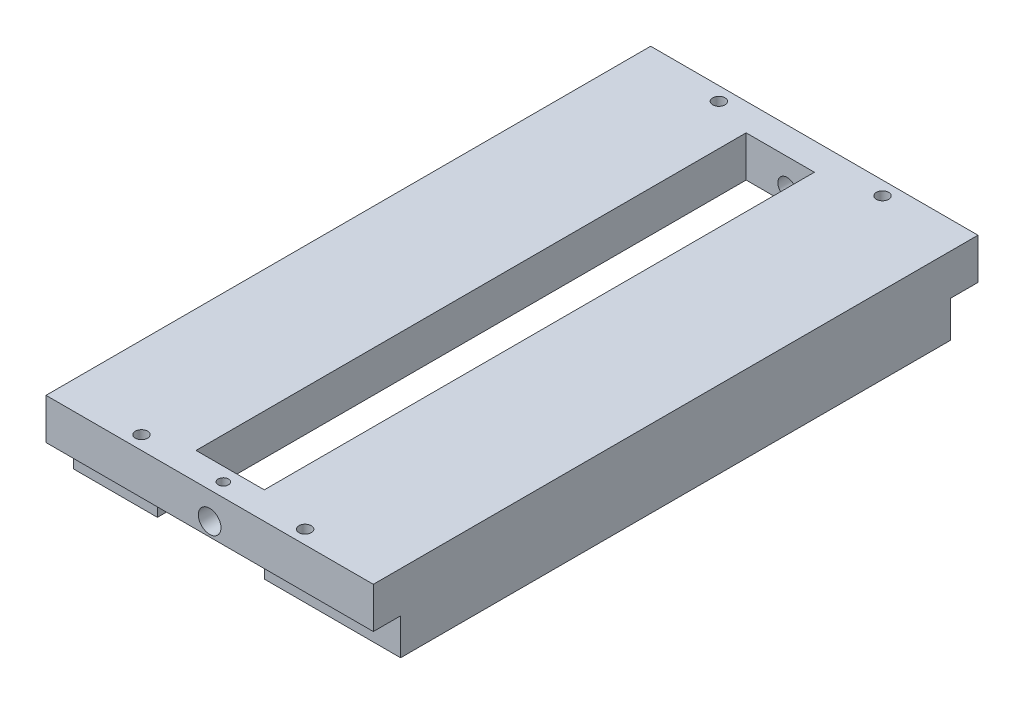
SolidWorks part; units mm, degrees
material "6061 Alloy"
ref_plane "Front Plane" through (0, 0, 0) normal (0, 0, 1) x (1, 0, 0)
ref_plane "Top Plane" through (0, 0, 0) normal (0, 1, 0) x (1, 0, 0)
ref_plane "Right Plane" through (0, 0, 0) normal (1, 0, 0) x (0, 0, -1)
sketch "Sketch1" plane through (0, 0, 0) normal (0, 1, 0) x (1, 0, 0)
  line L0 (45.5, -66.5) -> (45.5, 66.5)
  line L1 (45.5, 66.5) -> (-45.5, 66.5)
  line L2 (-45.5, 66.5) -> (-45.5, -66.5)
  line L3 (-45.5, -66.5) -> (45.5, -66.5)
  point P6 (0, 66.5)
  point P7 (45.5, 0)
  dimension "D1" = 91
  dimension "D2" = 133
extrude "Boss-Extrude1" add sketch "Sketch1" against normal blind 9
sketch "Outline of Hamilton Stand" plane through (0, 0, 0) normal (0, 1, 0) x (1, 0, 0)
  line L0 (-42.865, -30) -> (-42.865, -56.005)
  line L1 (-42.865, -56.005) -> (-47, -56.005)
  line L2 (-47, -56.005) -> (-47, -64.005)
  line L3 (-47, -64.005) -> (-24, -64.005)
  line L4 (-24, -64.005) -> (-24, -67)
  line L5 (-24, -67) -> (24, -67)
  line L6 (24, -67) -> (24, -64.005)
  line L7 (24, -64.005) -> (47, -64.005)
  line L8 (47, -64.005) -> (47, -56.005)
  line L9 (47, -56.005) -> (42.865, -56.005)
  line L10 (42.865, -56.005) -> (42.865, -30)
  line L11 (42.865, -30) -> (47, -30)
  line L12 (47, -30) -> (47, -20)
  line L13 (47, -20) -> (42.5, -20)
  line L14 (38.5, -16) -> (38.5, 16)
  line L15 (42.5, 20) -> (47, 20)
  line L16 (47, 20) -> (47, 30)
  line L17 (47, 30) -> (42.865, 30)
  line L18 (42.865, 30) -> (42.865, 56.005)
  line L19 (42.865, 56.005) -> (47, 56.005)
  line L20 (47, 56.005) -> (47, 64.005)
  line L21 (47, 64.005) -> (24, 64.005)
  line L22 (24, 64.005) -> (24, 67)
  line L23 (24, 67) -> (-24, 67)
  line L24 (-24, 67) -> (-24, 64.005)
  line L25 (-24, 64.005) -> (-47, 64.005)
  line L26 (-47, 64.005) -> (-47, 56.005)
  line L27 (-47, 56.005) -> (-42.865, 56.005)
  line L28 (-42.865, 56.005) -> (-42.865, 30)
  line L29 (-42.865, 30) -> (-47, 30)
  line L30 (-47, 30) -> (-47, 20)
  line L31 (-47, 20) -> (-42.5, 20)
  line L32 (-38.5, 16) -> (-38.5, -16)
  line L33 (-42.5, -20) -> (-47, -20)
  line L34 (-47, -20) -> (-47, -30)
  line L35 (-47, -30) -> (-42.865, -30)
  arc A0 (38.5, -16) -> (42.5, -20) centre (42.5, -16) ccw
  arc A1 (42.5, 20) -> (38.5, 16) centre (42.5, 16) ccw
  arc A2 (-38.5, 16) -> (-42.5, 20) centre (-42.5, 16) ccw
  arc A3 (-42.5, -20) -> (-38.5, -16) centre (-42.5, -16) ccw
sketch "60mm LFA Outline" plane through (0, 0, 0) normal (0, 1, 0) x (1, 0, 0)
  line L0 (-31.25, 64) -> (-27.25, 64)
  line L1 (-35.75, 64) -> (-31.75, 64)
  line L2 (-35.75, 64) -> (-35.75, 4)
  line L3 (-35.75, 4) -> (-31.75, 4)
  line L4 (-31.75, 64) -> (-31.75, 4)
  line L5 (-35.75, 64) -> (-31.75, 4) construction
  line L6 (-35.75, 4) -> (-31.75, 64) construction
  line L7 (-27.25, 64) -> (-27.25, 4)
  line L8 (-31.25, 4) -> (-27.25, 4)
  line L9 (-31.25, 64) -> (-31.25, 4)
  line L10 (-26.75, 64) -> (-22.75, 64)
  line L11 (-22.75, 64) -> (-22.75, 4)
  line L12 (-26.75, 4) -> (-22.75, 4)
  line L13 (-26.75, 64) -> (-26.75, 4)
  line L14 (-22.25, 64) -> (-18.25, 64)
  line L15 (-18.25, 64) -> (-18.25, 4)
  line L16 (-22.25, 4) -> (-18.25, 4)
  line L17 (-22.25, 64) -> (-22.25, 4)
  line L18 (-17.75, 64) -> (-13.75, 64)
  line L19 (-13.75, 64) -> (-13.75, 4)
  line L20 (-17.75, 4) -> (-13.75, 4)
  line L21 (-17.75, 64) -> (-17.75, 4)
  line L22 (-13.25, 64) -> (-9.25, 64)
  line L23 (-9.25, 64) -> (-9.25, 4)
  line L24 (-13.25, 4) -> (-9.25, 4)
  line L25 (-13.25, 64) -> (-13.25, 4)
  line L26 (-8.75, 64) -> (-4.75, 64)
  line L27 (-4.75, 64) -> (-4.75, 4)
  line L28 (-8.75, 4) -> (-4.75, 4)
  line L29 (-8.75, 64) -> (-8.75, 4)
  line L30 (-4.25, 64) -> (-0.25, 64)
  line L31 (-0.25, 64) -> (-0.25, 4)
  line L32 (-4.25, 4) -> (-0.25, 4)
  line L33 (-4.25, 64) -> (-4.25, 4)
  line L34 (0.25, 64) -> (4.25, 64)
  line L35 (4.25, 64) -> (4.25, 4)
  line L36 (0.25, 4) -> (4.25, 4)
  line L37 (0.25, 64) -> (0.25, 4)
  line L38 (4.75, 64) -> (8.75, 64)
  line L39 (8.75, 64) -> (8.75, 4)
  line L40 (4.75, 4) -> (8.75, 4)
  line L41 (4.75, 64) -> (4.75, 4)
  line L42 (9.25, 64) -> (13.25, 64)
  line L43 (13.25, 64) -> (13.25, 4)
  line L44 (9.25, 4) -> (13.25, 4)
  line L45 (9.25, 64) -> (9.25, 4)
  line L46 (13.75, 64) -> (17.75, 64)
  line L47 (17.75, 64) -> (17.75, 4)
  line L48 (13.75, 4) -> (17.75, 4)
  line L49 (13.75, 64) -> (13.75, 4)
  line L50 (18.25, 64) -> (22.25, 64)
  line L51 (22.25, 64) -> (22.25, 4)
  line L52 (18.25, 4) -> (22.25, 4)
  line L53 (18.25, 64) -> (18.25, 4)
  line L54 (22.75, 64) -> (26.75, 64)
  line L55 (26.75, 64) -> (26.75, 4)
  line L56 (22.75, 4) -> (26.75, 4)
  line L57 (22.75, 64) -> (22.75, 4)
  line L58 (27.25, 64) -> (31.25, 64)
  line L59 (31.25, 64) -> (31.25, 4)
  line L60 (27.25, 4) -> (31.25, 4)
  line L61 (27.25, 64) -> (27.25, 4)
  line L62 (31.75, 64) -> (35.75, 64)
  line L63 (35.75, 64) -> (35.75, 4)
  line L64 (31.75, 4) -> (35.75, 4)
  line L65 (31.75, 64) -> (31.75, 4)
  line L66 (-31.25, -1) -> (-27.25, -1)
  line L67 (-27.25, -1) -> (-27.25, -61)
  line L68 (-31.25, -61) -> (-27.25, -61)
  line L69 (-31.25, -1) -> (-31.25, -61)
  line L70 (-26.75, -1) -> (-22.75, -1)
  line L71 (-22.75, -1) -> (-22.75, -61)
  line L72 (-26.75, -61) -> (-22.75, -61)
  line L73 (-26.75, -1) -> (-26.75, -61)
  line L74 (-22.25, -1) -> (-18.25, -1)
  line L75 (-18.25, -1) -> (-18.25, -61)
  line L76 (-22.25, -61) -> (-18.25, -61)
  line L77 (-22.25, -1) -> (-22.25, -61)
  line L78 (-17.75, -1) -> (-13.75, -1)
  line L79 (-13.75, -1) -> (-13.75, -61)
  line L80 (-17.75, -61) -> (-13.75, -61)
  line L81 (-17.75, -1) -> (-17.75, -61)
  line L82 (-13.25, -1) -> (-9.25, -1)
  line L83 (-9.25, -1) -> (-9.25, -61)
  line L84 (-13.25, -61) -> (-9.25, -61)
  line L85 (-13.25, -1) -> (-13.25, -61)
  line L86 (-8.75, -1) -> (-4.75, -1)
  line L87 (-4.75, -1) -> (-4.75, -61)
  line L88 (-8.75, -61) -> (-4.75, -61)
  line L89 (-8.75, -1) -> (-8.75, -61)
  line L90 (-4.25, -1) -> (-0.25, -1)
  line L91 (-0.25, -1) -> (-0.25, -61)
  line L92 (-4.25, -61) -> (-0.25, -61)
  line L93 (-4.25, -1) -> (-4.25, -61)
  line L94 (0.25, -1) -> (4.25, -1)
  line L95 (4.25, -1) -> (4.25, -61)
  line L96 (0.25, -61) -> (4.25, -61)
  line L97 (0.25, -1) -> (0.25, -61)
  line L98 (4.75, -1) -> (8.75, -1)
  line L99 (8.75, -1) -> (8.75, -61)
  line L100 (4.75, -61) -> (8.75, -61)
  line L101 (4.75, -1) -> (4.75, -61)
  line L102 (9.25, -1) -> (13.25, -1)
  line L103 (13.25, -1) -> (13.25, -61)
  line L104 (9.25, -61) -> (13.25, -61)
  line L105 (9.25, -1) -> (9.25, -61)
  line L106 (13.75, -1) -> (17.75, -1)
  line L107 (17.75, -1) -> (17.75, -61)
  line L108 (13.75, -61) -> (17.75, -61)
  line L109 (13.75, -1) -> (13.75, -61)
  line L110 (18.25, -1) -> (22.25, -1)
  line L111 (22.25, -1) -> (22.25, -61)
  line L112 (18.25, -61) -> (22.25, -61)
  line L113 (18.25, -1) -> (18.25, -61)
  line L114 (22.75, -1) -> (26.75, -1)
  line L115 (26.75, -1) -> (26.75, -61)
  line L116 (22.75, -61) -> (26.75, -61)
  line L117 (22.75, -1) -> (22.75, -61)
  line L118 (27.25, -1) -> (31.25, -1)
  line L119 (31.25, -1) -> (31.25, -61)
  line L120 (27.25, -61) -> (31.25, -61)
  line L121 (27.25, -1) -> (27.25, -61)
  line L122 (31.75, -1) -> (35.75, -1)
  line L123 (35.75, -1) -> (35.75, -61)
  line L124 (31.75, -61) -> (35.75, -61)
  line L125 (31.75, -1) -> (31.75, -61)
  line L126 (-35.75, -1) -> (-31.75, -1)
  line L127 (-31.75, -1) -> (-31.75, -61)
  line L128 (-35.75, -61) -> (-31.75, -61)
  line L129 (-35.75, -1) -> (-35.75, -61)
  line L130 (-35.75, 64) -> (35.75, -61) construction
  line L136 (-45.5, -66.5) -> (45.5, -66.5) construction
  point P0 (-33.75, 34)
  point P6 (0, 1.5)
  dimension "D1" = 4
  dimension "D2" = 60
  dimension "D5" = 0.5
  dimension "D6" = 5
  dimension "D7" = 71.5
  dimension "D8" = 125
  dimension "D9" = 5.5
  dimension "D3" = 16
  dimension "D4" = 2
sketch "Sketch8" plane through (0, -9, 0) normal (0, -1, 0) x (1, 0, 0)
  line L1 (-42.875, 60.5) -> (42.875, 60.5)
  line L2 (-42.875, 60.5) -> (-42.875, -60.5)
  line L3 (-42.875, -60.5) -> (42.875, -60.5)
  line L4 (42.875, 60.5) -> (42.875, -60.5)
  line L5 (-42.875, 60.5) -> (42.875, -60.5) construction
  line L6 (-42.875, -60.5) -> (42.875, 60.5) construction
  line L11 (0, 70.056) -> (0, 88.5956) construction
  line L14 (-15.2687, 0) -> (-67.6323, 0) construction
  point P0 (0, 0)
  dimension "D1" = 85.75
  dimension "D2" = 121
extrude "Boss-Extrude2" add sketch "Sketch8" along normal blind 8
hole_wizard "1/8 (0.125) Diameter Hole1" positions "Sketch6" profile "Sketch7" hole size "1/8" standard "ANSI Inch"
sketch "Sketch6" plane through (0, -17, 0) normal (0, -1, 0) x (-1, 0, 0)
  line L0 (45.5, -66.5) -> (-45.5, 66.5) construction
  line L4 (10.7992, 0) -> (-24.6959, 0) construction
  line L6 (0, 8.8738) -> (0, 28.9653) construction
  point P0 (-12.7, -38.1)
  point P2 (-12.7, 38.1)
  point P24 (0, 0)
  dimension "D1" = 12.7
  dimension "D2" = 38.1
sketch "Sketch7" plane through (12.7, -17, 38.1) normal (1, 0, 0) x (0, 0, -1)
  line L0 (0, 0) -> (0, 16.3929)
  line L1 (0, 16.3929) -> (1.5875, 15.439)
  line L2 (1.5875, 15.439) -> (1.5875, 0)
  line L5 (1.5875, 0) -> (0, 0)
  line L10 (0, 16.3929) -> (-1.5875, 15.439) construction
  line L11 (0, -6.35) -> (0, 107.95) construction
  dimension "Hole Dia." = 3.175
  dimension "Hole Depth" = 15.439
  dimension "Drill Angle" = 118
sketch "Sketch9" plane through (0, 0, 0) normal (0, 0, 1) x (1, 0, 0)
  line L1 (4.7244, -8.7276) -> (4.7244, -3.2724) construction
  line L2 (4.7244, -3.2724) -> (0, -0.5447) construction
  line L3 (0, -0.5447) -> (-4.7244, -3.2724) construction
  line L4 (-4.7244, -3.2724) -> (-4.7244, -8.7276) construction
  line L5 (-4.7244, -8.7276) -> (0, -11.4553) construction
  line L6 (0, -11.4553) -> (4.7244, -8.7276) construction
  line L7 (42.875, -17) -> (-42.875, -17) construction
  line L8 (-17.5, -9) -> (17.5, -9)
  line L9 (0, 5.2906) -> (0, 7.973) construction
  line L10 (17.5, -9) -> (17.5, -17)
  line L11 (17.5, -17) -> (-17.5, -17)
  line L12 (-17.5, -17) -> (-17.5, -9)
  line L14 (-45.5, 0) -> (45.5, 0) construction
  line L15 (21, 0) -> (29, 0) construction
  line L16 (21, 0) -> (21, -3) construction
  line L17 (21, -3) -> (29, -3) construction
  line L18 (29, 0) -> (29, -3) construction
  line L19 (-29, 0) -> (-29, -3) construction
  line L20 (-21, -3) -> (-29, -3) construction
  line L21 (-21, 0) -> (-21, -3) construction
  line L22 (-21, 0) -> (-29, 0) construction
  circle A0 centre (0, -6) radius 2.413 construction
  circle A1 centre (0, -6) radius 4.7244 construction
  point P15 (0, -9)
  point P29 (25, 0)
  dimension "D1" = 4.826
  dimension "D2" = 9.4488
  dimension "D3" = 11
  dimension "D4" = 8
  dimension "D5" = 35
  dimension "D6" = 8
  dimension "D7" = 3
  dimension "D8" = 50
extrude "Cut-Extrude1" cut sketch "Sketch9" against normal through all both and the other way through all
sketch "Sketch10" plane through (0, 0, 0) normal (0, 1, 0) x (1, 0, 0)
  line L0 (45.5, -66.5) -> (-45.5, -66.5) construction
  line L1 (-6, 60.5) -> (6, 60.5)
  line L2 (-6, 60.5) -> (-6, -60.5) construction
  line L3 (-6, -60.5) -> (6, -60.5)
  line L4 (6, 60.5) -> (6, -60.5) construction
  line L5 (-6, 60.5) -> (6, -60.5) construction
  line L6 (-6, -60.5) -> (6, 60.5) construction
  line L7 (-6, -60.5) -> (-9, -60.5)
  line L8 (-9, -60.5) -> (-9, 60.5)
  line L9 (-9, 60.5) -> (-6, 60.5)
  line L10 (6, 60.5) -> (6.0127, 60.5)
  line L11 (6.0127, 60.5) -> (6.0127, -60.5)
  line L12 (6.0127, -60.5) -> (6, -60.5)
  point P0 (0, 0)
  dimension "D1" = 12
  dimension "D2" = 6
  dimension "D3" = 3
  dimension "D4" = 0.0254
extrude "Cut-Extrude2" cut sketch "Sketch10" against normal through all
hole_wizard "Tap Drill for #10-32 Tap1" positions "Sketch13" profile "Sketch14" hole size "#10-32" standard "ANSI Inch" end condition up to next
sketch "Sketch13" plane through (0, 0, -60.5) normal (0, 0, 1) x (1, 0, 0)
  circle A0 centre (0, -6) radius 2.413 construction
  point P0 (0, -6)
sketch "Sketch14" plane through (0, -6, -60.5) normal (1, 0, 0) x (0, -1, 0)
  line L0 (0, 0) -> (0, 6)
  line L1 (0, 6) -> (2.0193, 6)
  line L2 (2.0193, 6) -> (2.0193, 0)
  line L5 (2.0193, 0) -> (0, 0)
  line L11 (0, -6.35) -> (0, 107.95) construction
  dimension "Thru Hole Dia." = 4.0386
  dimension "Thru Hole Depth" = 6
hole_wizard "#10 Clearance Hole1" positions "Sketch15" profile "Sketch16" hole size "#10" standard "ANSI Inch" end condition up to next
sketch "Sketch15" plane through (0, 0, 66.5) normal (0, 0, 1) x (1, 0, 0)
  circle A0 centre (0, -6) radius 2.413 construction
  point P0 (0, -6)
sketch "Sketch16" plane through (0, -6, 66.5) normal (1, 0, 0) x (0, -1, 0)
  line L0 (0, 0) -> (0, 6)
  line L1 (0, 6) -> (2.4892, 6)
  line L2 (2.4892, 6) -> (2.4892, 0)
  line L3 (3, 0) -> (-6, 0) construction
  line L5 (2.4892, 0) -> (0, 0)
  line L11 (0, -6.35) -> (0, 107.95) construction
  dimension "Thru Hole Dia." = 4.9784
  dimension "Thru Hole Depth" = 6
hole_wizard "Tap Drill for #4-40 Tap1" positions "Sketch11" profile "Sketch12" hole size "#4-40" standard "ANSI Inch" end condition up to next
sketch "Sketch11" plane through (0, 0, 0) normal (0, 1, 0) x (1, 0, 0)
  line L0 (-4.0565, 0) -> (-13.2278, 0) construction
  line L1 (0, -60.5) -> (0, -66.5) construction
  line L2 (-9, -60.5) -> (6.0127, -60.5) construction
  line L3 (-45.5, -66.5) -> (45.5, -66.5) construction
  point P0 (0, -63.5)
sketch "Sketch12" plane through (0, 0, 63.5) normal (1, 0, 0) x (0, 0, 1)
  line L0 (0, 0) -> (0, 3.5108)
  line L1 (0, 3.5108) -> (1.1303, 3.5108)
  line L2 (1.1303, 3.5108) -> (1.1303, 0)
  line L5 (1.1303, 0) -> (0, 0)
  line L11 (0, -6.35) -> (0, 107.95) construction
  dimension "Thru Hole Dia." = 2.2606
  dimension "Thru Hole Depth" = 3.5108
sketch "Sketch17" plane through (0, 0, 66.5) normal (0, 0, 1) x (1, 0, 0)
  line L0 (-17.5, -17) -> (-42.875, -17) construction
  line L1 (-45.5, 0) -> (-36, 0)
  line L2 (-45.5, 0) -> (-45.5, -17)
  line L3 (-45.5, -17) -> (-36, -17)
  line L4 (-36, 0) -> (-36, -17)
  line L6 (0, 0) -> (0, 50000) construction
  line L7 (-45.5, 0) -> (45.5, 0) construction
  line L8 (45.5, -17) -> (36, -17)
  line L9 (36, 0) -> (36, -17)
  line L10 (45.5, 0) -> (36, 0)
  line L11 (45.5, 0) -> (45.5, -17)
  point P12 (0, 0)
  dimension "D1" = 17
  dimension "D2" = 9.5
extrude "Cut-Extrude3" [suppressed] cut sketch "Sketch17" against normal up to next
hole_wizard "Tap Drill for #6-32 Tap1" positions "Sketch18" profile "Sketch19" hole size "#6-32" standard "ANSI Inch" end condition through all
sketch "Sketch18" plane through (0, 0, 0) normal (0, 1, 0) x (1, 0, 0)
  line L0 (-4.0615, 0) -> (-18.012, 0) construction
  line L1 (0, 12.1846) -> (0, 31.0796) construction
  line L2 (-45.5, -66.5) -> (45.5, -66.5) construction
  point P0 (-18, -63.5)
  point P2 (18, -63.5)
  point P16 (18, 63.5)
  point P17 (-18, 63.5)
  dimension "D1" = 36
  dimension "D2" = 3
sketch "Sketch19" plane through (-18, 0, 63.5) normal (1, 0, 0) x (0, 0, 1)
  line L0 (0, 0) -> (0, 17)
  line L1 (0, 17) -> (1.3525, 17)
  line L2 (1.3525, 17) -> (1.3525, 0)
  line L5 (1.3525, 0) -> (0, 0)
  line L11 (0, -6.35) -> (0, 107.95) construction
  dimension "Thru Hole Dia." = 2.7051
  dimension "Thru Hole Depth" = 17
sketch "Sketch20" plane through (0, 0, 66.5) normal (0, 0, 1) x (1, 0, 0)
  line L1 (45.5, -9) -> (36, -9)
  line L2 (45.5, -9) -> (45.5, 0)
  line L3 (45.5, 0) -> (36, 0)
  line L4 (36, -9) -> (36, 0)
  line L5 (-45.5, 0) -> (45.5, 0) construction
  line L6 (0, 0) -> (0, 50000) construction
  line L7 (-45.5, 0) -> (-36, 0)
  line L8 (-36, -9) -> (-36, 0)
  line L9 (-45.5, -9) -> (-36, -9)
  line L10 (-45.5, -9) -> (-45.5, 0)
  point P10 (0, 0)
  dimension "D1" = 9
  dimension "D2" = 9.5
extrude "Cut-Extrude4" cut sketch "Sketch20" against normal up to next
sketch "Sketch21" plane through (0, 0, 0) normal (0, 1, 0) x (1, 0, 0)
  line L1 (-36, 66.5) -> (36, 66.5)
  line L2 (-36, 66.5) -> (-36, -66.5)
  line L3 (-36, -66.5) -> (36, -66.5)
  line L4 (36, 66.5) -> (36, -66.5)
extrude "Cut-Extrude5" cut sketch "Sketch21" against normal through all both and the other way through all flip side to cut
sketch "Sketch22" plane through (0, -9, 0) normal (0, -1, 0) x (1, 0, 0)
  line L1 (17.5, 60.5) -> (6.0127, 60.5)
  line L2 (17.5, 60.5) -> (17.5, -60.5)
  line L3 (17.5, -60.5) -> (6.0127, -60.5)
  line L4 (6.0127, 60.5) -> (6.0127, -60.5)
  circle A0 centre (12.7, 38.1) radius 1.5875 construction
  circle A1 centre (12.7, 38.1) radius 1.5875
  circle A2 centre (12.7, -38.1) radius 1.5875 construction
  circle A3 centre (12.7, -38.1) radius 1.5875
extrude "Boss-Extrude3" add sketch "Sketch22" along normal up to surface (8 mm away) up to face at (26.75, -17, 0)
sketch "Sketch23" plane through (0, 0, 0) normal (0, 1, 0) x (1, 0, 0)
  line L1 (16.5, 60) -> (10.1667, 60)
  line L6 (16.5, 60.5) -> (23.5, 60.5)
  line L7 (16.5, 59.5) -> (22.1667, 59.5)
  line L8 (16.5, 59) -> (11.5, 59)
  line L9 (16.5, 58.5) -> (20.8333, 58.5)
  line L10 (16.5, 58) -> (12.8333, 58)
  line L11 (16.5, 57.5) -> (19.5, 57.5)
  line L12 (16.5, 57) -> (14.1667, 57)
  line L13 (16.5, 56.5) -> (18.1667, 56.5)
  line L14 (16.5, 52) -> (14.1667, 52)
  line L15 (16.5, 53) -> (12.8333, 53)
  line L16 (16.5, 54) -> (11.5, 54)
  line L17 (16.5, 55) -> (10.1667, 55)
  line L18 (16.5, 55.5) -> (23.5, 55.5)
  line L19 (16.5, 54.5) -> (22.1667, 54.5)
  line L20 (16.5, 53.5) -> (20.8333, 53.5)
  line L21 (16.5, 52.5) -> (19.5, 52.5)
  line L22 (16.5, 51.5) -> (18.1667, 51.5)
  line L23 (16.5, 51) -> (15.5, 51)
  line L24 (16.5, 47) -> (14.1667, 47)
  line L25 (16.5, 48) -> (12.8333, 48)
  line L26 (16.5, 49) -> (11.5, 49)
  line L27 (16.5, 50) -> (10.1667, 50)
  line L28 (16.5, 50.5) -> (23.5, 50.5)
  line L29 (16.5, 49.5) -> (22.1667, 49.5)
  line L30 (16.5, 48.5) -> (20.8333, 48.5)
  line L31 (16.5, 47.5) -> (19.5, 47.5)
  line L32 (16.5, 46.5) -> (18.1667, 46.5)
  line L33 (16.5, 46) -> (15.5, 46)
  line L34 (16.5, 42) -> (14.1667, 42)
  line L35 (16.5, 43) -> (12.8333, 43)
  line L36 (16.5, 44) -> (11.5, 44)
  line L37 (16.5, 45) -> (10.1667, 45)
  line L38 (16.5, 45.5) -> (23.5, 45.5)
  line L39 (16.5, 44.5) -> (22.1667, 44.5)
  line L40 (16.5, 43.5) -> (20.8333, 43.5)
  line L41 (16.5, 42.5) -> (19.5, 42.5)
  line L42 (16.5, 41.5) -> (18.1667, 41.5)
  line L43 (16.5, 41) -> (15.5, 41)
  line L44 (16.5, 37) -> (14.1667, 37)
  line L45 (16.5, 38) -> (12.8333, 38)
  line L46 (16.5, 39) -> (11.5, 39)
  line L47 (16.5, 40) -> (10.1667, 40)
  line L48 (16.5, 40.5) -> (23.5, 40.5)
  line L49 (16.5, 39.5) -> (22.1667, 39.5)
  line L50 (16.5, 38.5) -> (20.8333, 38.5)
  line L51 (16.5, 37.5) -> (19.5, 37.5)
  line L52 (16.5, 36.5) -> (18.1667, 36.5)
  line L53 (16.5, 36) -> (15.5, 36)
  line L54 (16.5, 32) -> (14.1667, 32)
  line L55 (16.5, 33) -> (12.8333, 33)
  line L56 (16.5, 34) -> (11.5, 34)
  line L57 (16.5, 35) -> (10.1667, 35)
  line L58 (16.5, 35.5) -> (23.5, 35.5)
  line L59 (16.5, 34.5) -> (22.1667, 34.5)
  line L60 (16.5, 33.5) -> (20.8333, 33.5)
  line L61 (16.5, 32.5) -> (19.5, 32.5)
  line L62 (16.5, 31.5) -> (18.1667, 31.5)
  line L63 (16.5, 31) -> (15.5, 31)
  line L64 (16.5, 27) -> (14.1667, 27)
  line L65 (16.5, 28) -> (12.8333, 28)
  line L66 (16.5, 29) -> (11.5, 29)
  line L67 (16.5, 30) -> (10.1667, 30)
  line L68 (16.5, 30.5) -> (23.5, 30.5)
  line L69 (16.5, 29.5) -> (22.1667, 29.5)
  line L70 (16.5, 28.5) -> (20.8333, 28.5)
  line L71 (16.5, 27.5) -> (19.5, 27.5)
  line L72 (16.5, 26.5) -> (18.1667, 26.5)
  line L73 (16.5, 26) -> (15.5, 26)
  line L74 (16.5, 22) -> (14.1667, 22)
  line L75 (16.5, 23) -> (12.8333, 23)
  line L76 (16.5, 24) -> (11.5, 24)
  line L77 (16.5, 25) -> (10.1667, 25)
  line L78 (16.5, 25.5) -> (23.5, 25.5)
  line L79 (16.5, 24.5) -> (22.1667, 24.5)
  line L80 (16.5, 23.5) -> (20.8333, 23.5)
  line L81 (16.5, 22.5) -> (19.5, 22.5)
  line L82 (16.5, 21.5) -> (18.1667, 21.5)
  line L83 (16.5, 21) -> (15.5, 21)
  line L84 (16.5, 17) -> (14.1667, 17)
  line L85 (16.5, 18) -> (12.8333, 18)
  line L86 (16.5, 19) -> (11.5, 19)
  line L87 (16.5, 20) -> (10.1667, 20)
  line L88 (16.5, 20.5) -> (23.5, 20.5)
  line L89 (16.5, 19.5) -> (22.1667, 19.5)
  line L90 (16.5, 18.5) -> (20.8333, 18.5)
  line L91 (16.5, 17.5) -> (19.5, 17.5)
  line L92 (16.5, 16.5) -> (18.1667, 16.5)
  line L93 (16.5, 16) -> (15.5, 16)
  line L94 (16.5, 12) -> (14.1667, 12)
  line L95 (16.5, 13) -> (12.8333, 13)
  line L96 (16.5, 14) -> (11.5, 14)
  line L97 (16.5, 15) -> (10.1667, 15)
  line L98 (16.5, 15.5) -> (23.5, 15.5)
  line L99 (16.5, 14.5) -> (22.1667, 14.5)
  line L100 (16.5, 13.5) -> (20.8333, 13.5)
  line L101 (16.5, 12.5) -> (19.5, 12.5)
  line L102 (16.5, 11.5) -> (18.1667, 11.5)
  line L103 (16.5, 11) -> (15.5, 11)
  line L104 (16.5, 7) -> (14.1667, 7)
  line L105 (16.5, 8) -> (12.8333, 8)
  line L106 (16.5, 9) -> (11.5, 9)
  line L107 (16.5, 10) -> (10.1667, 10)
  line L108 (16.5, 10.5) -> (23.5, 10.5)
  line L109 (16.5, 9.5) -> (22.1667, 9.5)
  line L110 (16.5, 8.5) -> (20.8333, 8.5)
  line L111 (16.5, 7.5) -> (19.5, 7.5)
  line L112 (16.5, 6.5) -> (18.1667, 6.5)
  line L113 (16.5, 6) -> (15.5, 6)
  line L114 (16.5, 2) -> (14.1667, 2)
  line L115 (16.5, 3) -> (12.8333, 3)
  line L116 (16.5, 4) -> (11.5, 4)
  line L117 (16.5, 5) -> (10.1667, 5)
  line L118 (16.5, 5.5) -> (23.5, 5.5)
  line L119 (16.5, 4.5) -> (22.1667, 4.5)
  line L120 (16.5, 3.5) -> (20.8333, 3.5)
  line L121 (16.5, 2.5) -> (19.5, 2.5)
  line L122 (16.5, 1.5) -> (18.1667, 1.5)
  line L123 (16.5, 1) -> (15.5, 1)
  line L124 (16.5, -3) -> (14.1667, -3)
  line L125 (16.5, -2) -> (12.8333, -2)
  line L126 (16.5, -1) -> (11.5, -1)
  line L127 (16.5, 0) -> (10.1667, 0)
  line L128 (16.5, 0.5) -> (23.5, 0.5)
  line L129 (16.5, -0.5) -> (22.1667, -0.5)
  line L130 (16.5, -1.5) -> (20.8333, -1.5)
  line L131 (16.5, -2.5) -> (19.5, -2.5)
  line L132 (16.5, -3.5) -> (18.1667, -3.5)
  line L133 (16.5, -4) -> (15.5, -4)
  line L134 (16.5, -8) -> (14.1667, -8)
  line L135 (16.5, -7) -> (12.8333, -7)
  line L136 (16.5, -6) -> (11.5, -6)
  line L137 (16.5, -5) -> (10.1667, -5)
  line L138 (16.5, -4.5) -> (23.5, -4.5)
  line L139 (16.5, -5.5) -> (22.1667, -5.5)
  line L140 (16.5, -6.5) -> (20.8333, -6.5)
  line L141 (16.5, -7.5) -> (19.5, -7.5)
  line L142 (16.5, -8.5) -> (18.1667, -8.5)
  line L143 (16.5, -9) -> (15.5, -9)
  line L144 (16.5, -13) -> (14.1667, -13)
  line L145 (16.5, -12) -> (12.8333, -12)
  line L146 (16.5, -11) -> (11.5, -11)
  line L147 (16.5, -10) -> (10.1667, -10)
  line L148 (16.5, -9.5) -> (23.5, -9.5)
  line L149 (16.5, -10.5) -> (22.1667, -10.5)
  line L150 (16.5, -11.5) -> (20.8333, -11.5)
  line L151 (16.5, -12.5) -> (19.5, -12.5)
  line L152 (16.5, -13.5) -> (18.1667, -13.5)
  line L153 (16.5, -14) -> (15.5, -14)
  line L154 (16.5, -18) -> (14.1667, -18)
  line L155 (16.5, -17) -> (12.8333, -17)
  line L156 (16.5, -16) -> (11.5, -16)
  line L157 (16.5, -15) -> (10.1667, -15)
  line L158 (16.5, -14.5) -> (23.5, -14.5)
  line L159 (16.5, -15.5) -> (22.1667, -15.5)
  line L160 (16.5, -16.5) -> (20.8333, -16.5)
  line L161 (16.5, -17.5) -> (19.5, -17.5)
  line L162 (16.5, -18.5) -> (18.1667, -18.5)
  line L163 (16.5, -19) -> (15.5, -19)
  line L164 (16.5, -23) -> (14.1667, -23)
  line L165 (16.5, -22) -> (12.8333, -22)
  line L166 (16.5, -21) -> (11.5, -21)
  line L167 (16.5, -20) -> (10.1667, -20)
  line L168 (16.5, -19.5) -> (23.5, -19.5)
  line L169 (16.5, -20.5) -> (22.1667, -20.5)
  line L170 (16.5, -21.5) -> (20.8333, -21.5)
  line L171 (16.5, -22.5) -> (19.5, -22.5)
  line L172 (16.5, -23.5) -> (18.1667, -23.5)
  line L173 (16.5, -24) -> (15.5, -24)
  line L174 (16.5, -28) -> (14.1667, -28)
  line L175 (16.5, -27) -> (12.8333, -27)
  line L176 (16.5, -26) -> (11.5, -26)
  line L177 (16.5, -25) -> (10.1667, -25)
  line L178 (16.5, -24.5) -> (23.5, -24.5)
  line L179 (16.5, -25.5) -> (22.1667, -25.5)
  line L180 (16.5, -26.5) -> (20.8333, -26.5)
  line L181 (16.5, -27.5) -> (19.5, -27.5)
  line L182 (16.5, -28.5) -> (18.1667, -28.5)
  line L183 (16.5, -29) -> (15.5, -29)
  line L184 (16.5, -33) -> (14.1667, -33)
  line L185 (16.5, -32) -> (12.8333, -32)
  line L186 (16.5, -31) -> (11.5, -31)
  line L187 (16.5, -30) -> (10.1667, -30)
  line L188 (16.5, -29.5) -> (23.5, -29.5)
  line L189 (16.5, -30.5) -> (22.1667, -30.5)
  line L190 (16.5, -31.5) -> (20.8333, -31.5)
  line L191 (16.5, -32.5) -> (19.5, -32.5)
  line L192 (16.5, -33.5) -> (18.1667, -33.5)
  line L193 (16.5, -34) -> (15.5, -34)
  line L194 (16.5, -38) -> (14.1667, -38)
  line L195 (16.5, -37) -> (12.8333, -37)
  line L196 (16.5, -36) -> (11.5, -36)
  line L197 (16.5, -35) -> (10.1667, -35)
  line L198 (16.5, -34.5) -> (23.5, -34.5)
  line L199 (16.5, -35.5) -> (22.1667, -35.5)
  line L200 (16.5, -36.5) -> (20.8333, -36.5)
  line L201 (16.5, -37.5) -> (19.5, -37.5)
  line L202 (16.5, -38.5) -> (18.1667, -38.5)
  line L203 (16.5, -39) -> (15.5, -39)
  line L204 (16.5, -43) -> (14.1667, -43)
  line L205 (16.5, -42) -> (12.8333, -42)
  line L206 (16.5, -41) -> (11.5, -41)
  line L207 (16.5, -40) -> (10.1667, -40)
  line L208 (16.5, -39.5) -> (23.5, -39.5)
  line L209 (16.5, -40.5) -> (22.1667, -40.5)
  line L210 (16.5, -41.5) -> (20.8333, -41.5)
  line L211 (16.5, -42.5) -> (19.5, -42.5)
  line L212 (16.5, -43.5) -> (18.1667, -43.5)
  line L213 (16.5, -44) -> (15.5, -44)
  line L214 (16.5, -48) -> (14.1667, -48)
  line L215 (16.5, -47) -> (12.8333, -47)
  line L216 (16.5, -46) -> (11.5, -46)
  line L217 (16.5, -45) -> (10.1667, -45)
  line L218 (16.5, -44.5) -> (23.5, -44.5)
  line L219 (16.5, -45.5) -> (22.1667, -45.5)
  line L220 (16.5, -46.5) -> (20.8333, -46.5)
  line L221 (16.5, -47.5) -> (19.5, -47.5)
  line L222 (16.5, -48.5) -> (18.1667, -48.5)
  line L223 (16.5, -49) -> (15.5, -49)
  line L224 (16.5, -53) -> (14.1667, -53)
  line L225 (16.5, -52) -> (12.8333, -52)
  line L226 (16.5, -51) -> (11.5, -51)
  line L227 (16.5, -50) -> (10.1667, -50)
  line L228 (16.5, -49.5) -> (23.5, -49.5)
  line L229 (16.5, -50.5) -> (22.1667, -50.5)
  line L230 (16.5, -51.5) -> (20.8333, -51.5)
  line L231 (16.5, -52.5) -> (19.5, -52.5)
  line L232 (16.5, -53.5) -> (18.1667, -53.5)
  line L233 (16.5, -54) -> (15.5, -54)
  line L234 (16.5, -58) -> (14.1667, -58)
  line L235 (16.5, -57) -> (12.8333, -57)
  line L236 (16.5, -56) -> (11.5, -56)
  line L237 (16.5, -55) -> (10.1667, -55)
  line L238 (16.5, -54.5) -> (23.5, -54.5)
  line L239 (16.5, -55.5) -> (22.1667, -55.5)
  line L240 (16.5, -56.5) -> (20.8333, -56.5)
  line L241 (16.5, -57.5) -> (19.5, -57.5)
  line L242 (16.5, -58.5) -> (18.1667, -58.5)
  line L243 (16.5, -59) -> (15.5, -59)
  line L248 (16.5, -59.5) -> (23.5, -59.5)
  line L262 (-16.5, 56) -> (-15.5, 56)
  line L269 (-16.5, -59.5) -> (-23.5, -59.5)
  line L274 (-16.5, -59) -> (-15.5, -59)
  line L275 (-16.5, -58.5) -> (-18.1667, -58.5)
  line L276 (-16.5, -57.5) -> (-19.5, -57.5)
  line L277 (-16.5, -56.5) -> (-20.8333, -56.5)
  line L278 (-16.5, -55.5) -> (-22.1667, -55.5)
  line L279 (-16.5, -54.5) -> (-23.5, -54.5)
  line L280 (-16.5, -55) -> (-10.1667, -55)
  line L281 (-16.5, -56) -> (-11.5, -56)
  line L282 (-16.5, -57) -> (-12.8333, -57)
  line L283 (-16.5, -58) -> (-14.1667, -58)
  line L284 (-16.5, -54) -> (-15.5, -54)
  line L285 (-16.5, -53.5) -> (-18.1667, -53.5)
  line L286 (-16.5, -52.5) -> (-19.5, -52.5)
  line L287 (-16.5, -51.5) -> (-20.8333, -51.5)
  line L288 (-16.5, -50.5) -> (-22.1667, -50.5)
  line L289 (-16.5, -49.5) -> (-23.5, -49.5)
  line L290 (-16.5, -50) -> (-10.1667, -50)
  line L291 (-16.5, -51) -> (-11.5, -51)
  line L292 (-16.5, -52) -> (-12.8333, -52)
  line L293 (-16.5, -53) -> (-14.1667, -53)
  line L294 (-16.5, -49) -> (-15.5, -49)
  line L295 (-16.5, -48.5) -> (-18.1667, -48.5)
  line L296 (-16.5, -47.5) -> (-19.5, -47.5)
  line L297 (-16.5, -46.5) -> (-20.8333, -46.5)
  line L298 (-16.5, -45.5) -> (-22.1667, -45.5)
  line L299 (-16.5, -44.5) -> (-23.5, -44.5)
  line L300 (-16.5, -45) -> (-10.1667, -45)
  line L301 (-16.5, -46) -> (-11.5, -46)
  line L302 (-16.5, -47) -> (-12.8333, -47)
  line L303 (-16.5, -48) -> (-14.1667, -48)
  line L304 (-16.5, -44) -> (-15.5, -44)
  line L305 (-16.5, -43.5) -> (-18.1667, -43.5)
  line L306 (-16.5, -42.5) -> (-19.5, -42.5)
  line L307 (-16.5, -41.5) -> (-20.8333, -41.5)
  line L308 (-16.5, -40.5) -> (-22.1667, -40.5)
  line L309 (-16.5, -39.5) -> (-23.5, -39.5)
  line L310 (-16.5, -40) -> (-10.1667, -40)
  line L311 (-16.5, -41) -> (-11.5, -41)
  line L312 (-16.5, -42) -> (-12.8333, -42)
  line L313 (-16.5, -43) -> (-14.1667, -43)
  line L314 (-16.5, -39) -> (-15.5, -39)
  line L315 (-16.5, -38.5) -> (-18.1667, -38.5)
  line L316 (-16.5, -37.5) -> (-19.5, -37.5)
  line L317 (-16.5, -36.5) -> (-20.8333, -36.5)
  line L318 (-16.5, -35.5) -> (-22.1667, -35.5)
  line L319 (-16.5, -34.5) -> (-23.5, -34.5)
  line L320 (-16.5, -35) -> (-10.1667, -35)
  line L321 (-16.5, -36) -> (-11.5, -36)
  line L322 (-16.5, -37) -> (-12.8333, -37)
  line L323 (-16.5, -38) -> (-14.1667, -38)
  line L324 (-16.5, -34) -> (-15.5, -34)
  line L325 (-16.5, -33.5) -> (-18.1667, -33.5)
  line L326 (-16.5, -32.5) -> (-19.5, -32.5)
  line L328 (16.5, 56) -> (15.5, 56)
  line L329 (-16.5, -31.5) -> (-20.8333, -31.5)
  line L330 (-16.5, -30.5) -> (-22.1667, -30.5)
  line L331 (-16.5, -29.5) -> (-23.5, -29.5)
  line L332 (-16.5, -30) -> (-10.1667, -30)
  line L333 (-16.5, -31) -> (-11.5, -31)
  line L334 (-16.5, -32) -> (-12.8333, -32)
  line L335 (-16.5, -33) -> (-14.1667, -33)
  line L336 (-16.5, -29) -> (-15.5, -29)
  line L337 (-16.5, -28.5) -> (-18.1667, -28.5)
  line L338 (-16.5, -27.5) -> (-19.5, -27.5)
  line L339 (-16.5, -26.5) -> (-20.8333, -26.5)
  line L340 (-16.5, -25.5) -> (-22.1667, -25.5)
  line L341 (-16.5, -24.5) -> (-23.5, -24.5)
  line L342 (-16.5, -25) -> (-10.1667, -25)
  line L343 (-16.5, -26) -> (-11.5, -26)
  line L344 (-16.5, -27) -> (-12.8333, -27)
  line L345 (-16.5, -28) -> (-14.1667, -28)
  line L346 (-16.5, -24) -> (-15.5, -24)
  line L347 (-16.5, -23.5) -> (-18.1667, -23.5)
  line L348 (-16.5, -22.5) -> (-19.5, -22.5)
  line L349 (-16.5, -21.5) -> (-20.8333, -21.5)
  line L350 (-16.5, -20.5) -> (-22.1667, -20.5)
  line L351 (-16.5, -19.5) -> (-23.5, -19.5)
  line L352 (-16.5, -20) -> (-10.1667, -20)
  line L353 (-16.5, -21) -> (-11.5, -21)
  line L354 (-16.5, -22) -> (-12.8333, -22)
  line L355 (-16.5, -23) -> (-14.1667, -23)
  line L356 (-16.5, -19) -> (-15.5, -19)
  line L357 (-16.5, -18.5) -> (-18.1667, -18.5)
  line L358 (-16.5, -17.5) -> (-19.5, -17.5)
  line L359 (-16.5, -16.5) -> (-20.8333, -16.5)
  line L360 (-16.5, -15.5) -> (-22.1667, -15.5)
  line L361 (-16.5, -14.5) -> (-23.5, -14.5)
  line L362 (-16.5, -15) -> (-10.1667, -15)
  line L363 (-16.5, -16) -> (-11.5, -16)
  line L364 (-16.5, -17) -> (-12.8333, -17)
  line L365 (-16.5, -18) -> (-14.1667, -18)
  line L366 (-16.5, -14) -> (-15.5, -14)
  line L367 (-16.5, -13.5) -> (-18.1667, -13.5)
  line L368 (-16.5, -12.5) -> (-19.5, -12.5)
  line L369 (-16.5, -11.5) -> (-20.8333, -11.5)
  line L370 (-16.5, -10.5) -> (-22.1667, -10.5)
  line L371 (-16.5, -9.5) -> (-23.5, -9.5)
  line L372 (-16.5, -10) -> (-10.1667, -10)
  line L373 (-16.5, -11) -> (-11.5, -11)
  line L374 (-16.5, -12) -> (-12.8333, -12)
  line L375 (-16.5, -13) -> (-14.1667, -13)
  line L376 (-16.5, -9) -> (-15.5, -9)
  line L377 (-16.5, -8.5) -> (-18.1667, -8.5)
  line L378 (-16.5, -7.5) -> (-19.5, -7.5)
  line L379 (-16.5, -6.5) -> (-20.8333, -6.5)
  line L380 (-16.5, -5.5) -> (-22.1667, -5.5)
  line L381 (-16.5, -4.5) -> (-23.5, -4.5)
  line L382 (-16.5, -5) -> (-10.1667, -5)
  line L383 (-16.5, -6) -> (-11.5, -6)
  line L384 (-16.5, -7) -> (-12.8333, -7)
  line L385 (-16.5, -8) -> (-14.1667, -8)
  line L386 (-16.5, -4) -> (-15.5, -4)
  line L387 (-16.5, -3.5) -> (-18.1667, -3.5)
  line L388 (-16.5, -2.5) -> (-19.5, -2.5)
  line L389 (-16.5, -1.5) -> (-20.8333, -1.5)
  line L390 (-16.5, -0.5) -> (-22.1667, -0.5)
  line L391 (-16.5, 0.5) -> (-23.5, 0.5)
  line L392 (-16.5, 0) -> (-10.1667, 0)
  line L393 (-16.5, -1) -> (-11.5, -1)
  line L394 (-16.5, -2) -> (-12.8333, -2)
  line L395 (-16.5, -3) -> (-14.1667, -3)
  line L396 (-16.5, 1) -> (-15.5, 1)
  line L397 (-16.5, 1.5) -> (-18.1667, 1.5)
  line L398 (-16.5, 2.5) -> (-19.5, 2.5)
  line L399 (-16.5, 3.5) -> (-20.8333, 3.5)
  line L400 (-16.5, 4.5) -> (-22.1667, 4.5)
  line L401 (-16.5, 5.5) -> (-23.5, 5.5)
  line L402 (-16.5, 5) -> (-10.1667, 5)
  line L403 (-16.5, 4) -> (-11.5, 4)
  line L404 (-16.5, 3) -> (-12.8333, 3)
  line L405 (-16.5, 2) -> (-14.1667, 2)
  line L406 (-16.5, 6) -> (-15.5, 6)
  line L407 (-16.5, 6.5) -> (-18.1667, 6.5)
  line L408 (-16.5, 7.5) -> (-19.5, 7.5)
  line L409 (-16.5, 8.5) -> (-20.8333, 8.5)
  line L410 (-16.5, 9.5) -> (-22.1667, 9.5)
  line L411 (-16.5, 10.5) -> (-23.5, 10.5)
  line L412 (-16.5, 10) -> (-10.1667, 10)
  line L413 (-16.5, 9) -> (-11.5, 9)
  line L414 (-16.5, 8) -> (-12.8333, 8)
  line L415 (-16.5, 7) -> (-14.1667, 7)
  line L416 (-16.5, 11) -> (-15.5, 11)
  line L417 (-16.5, 11.5) -> (-18.1667, 11.5)
  line L418 (-16.5, 12.5) -> (-19.5, 12.5)
  line L419 (-16.5, 13.5) -> (-20.8333, 13.5)
  line L420 (-16.5, 14.5) -> (-22.1667, 14.5)
  line L421 (-16.5, 15.5) -> (-23.5, 15.5)
  line L422 (-16.5, 15) -> (-10.1667, 15)
  line L423 (-16.5, 14) -> (-11.5, 14)
  line L424 (-16.5, 13) -> (-12.8333, 13)
  line L425 (-16.5, 12) -> (-14.1667, 12)
  line L426 (-16.5, 16) -> (-15.5, 16)
  line L427 (-16.5, 16.5) -> (-18.1667, 16.5)
  line L428 (-16.5, 17.5) -> (-19.5, 17.5)
  line L429 (-16.5, 18.5) -> (-20.8333, 18.5)
  line L430 (-16.5, 19.5) -> (-22.1667, 19.5)
  line L431 (-16.5, 20.5) -> (-23.5, 20.5)
  line L432 (-16.5, 20) -> (-10.1667, 20)
  line L433 (-16.5, 19) -> (-11.5, 19)
  line L434 (-16.5, 18) -> (-12.8333, 18)
  line L435 (-16.5, 17) -> (-14.1667, 17)
  line L436 (-16.5, 21) -> (-15.5, 21)
  line L437 (-16.5, 21.5) -> (-18.1667, 21.5)
  line L438 (-16.5, 22.5) -> (-19.5, 22.5)
  line L439 (-16.5, 23.5) -> (-20.8333, 23.5)
  line L440 (-16.5, 24.5) -> (-22.1667, 24.5)
  line L441 (-16.5, 25.5) -> (-23.5, 25.5)
  line L442 (-16.5, 25) -> (-10.1667, 25)
  line L443 (-16.5, 24) -> (-11.5, 24)
  line L444 (-16.5, 23) -> (-12.8333, 23)
  line L445 (-16.5, 22) -> (-14.1667, 22)
  line L446 (-16.5, 26) -> (-15.5, 26)
  line L447 (-16.5, 26.5) -> (-18.1667, 26.5)
  line L448 (-16.5, 27.5) -> (-19.5, 27.5)
  line L449 (-16.5, 28.5) -> (-20.8333, 28.5)
  line L450 (-16.5, 29.5) -> (-22.1667, 29.5)
  line L451 (-16.5, 30.5) -> (-23.5, 30.5)
  line L452 (-16.5, 30) -> (-10.1667, 30)
  line L453 (-16.5, 29) -> (-11.5, 29)
  line L454 (-16.5, 28) -> (-12.8333, 28)
  line L455 (-16.5, 27) -> (-14.1667, 27)
  line L456 (-16.5, 31) -> (-15.5, 31)
  line L457 (-16.5, 31.5) -> (-18.1667, 31.5)
  line L458 (-16.5, 32.5) -> (-19.5, 32.5)
  line L459 (-16.5, 33.5) -> (-20.8333, 33.5)
  line L460 (-16.5, 34.5) -> (-22.1667, 34.5)
  line L461 (-16.5, 35.5) -> (-23.5, 35.5)
  line L462 (-16.5, 35) -> (-10.1667, 35)
  line L463 (-16.5, 34) -> (-11.5, 34)
  line L464 (-16.5, 33) -> (-12.8333, 33)
  line L465 (-16.5, 32) -> (-14.1667, 32)
  line L466 (-16.5, 36) -> (-15.5, 36)
  line L467 (-16.5, 36.5) -> (-18.1667, 36.5)
  line L468 (-16.5, 37.5) -> (-19.5, 37.5)
  line L469 (-16.5, 38.5) -> (-20.8333, 38.5)
  line L470 (-16.5, 39.5) -> (-22.1667, 39.5)
  line L471 (-16.5, 40.5) -> (-23.5, 40.5)
  line L472 (-16.5, 40) -> (-10.1667, 40)
  line L473 (-16.5, 39) -> (-11.5, 39)
  line L474 (-16.5, 38) -> (-12.8333, 38)
  line L475 (-16.5, 37) -> (-14.1667, 37)
  line L476 (-16.5, 41) -> (-15.5, 41)
  line L477 (-16.5, 41.5) -> (-18.1667, 41.5)
  line L478 (-16.5, 42.5) -> (-19.5, 42.5)
  line L479 (-16.5, 43.5) -> (-20.8333, 43.5)
  line L480 (-16.5, 44.5) -> (-22.1667, 44.5)
  line L481 (-16.5, 45.5) -> (-23.5, 45.5)
  line L482 (-16.5, 45) -> (-10.1667, 45)
  line L483 (-16.5, 44) -> (-11.5, 44)
  line L484 (-16.5, 43) -> (-12.8333, 43)
  line L485 (-16.5, 42) -> (-14.1667, 42)
  line L486 (-16.5, 46) -> (-15.5, 46)
  line L487 (-16.5, 46.5) -> (-18.1667, 46.5)
  line L488 (-16.5, 47.5) -> (-19.5, 47.5)
  line L489 (-16.5, 48.5) -> (-20.8333, 48.5)
  line L490 (-16.5, 49.5) -> (-22.1667, 49.5)
  line L491 (-16.5, 50.5) -> (-23.5, 50.5)
  line L492 (-16.5, 50) -> (-10.1667, 50)
  line L493 (-16.5, 49) -> (-11.5, 49)
  line L494 (-16.5, 48) -> (-12.8333, 48)
  line L495 (-16.5, 47) -> (-14.1667, 47)
  line L496 (-16.5, 51) -> (-15.5, 51)
  line L497 (-16.5, 51.5) -> (-18.1667, 51.5)
  line L498 (-16.5, 52.5) -> (-19.5, 52.5)
  line L499 (-16.5, 53.5) -> (-20.8333, 53.5)
  line L500 (-16.5, 54.5) -> (-22.1667, 54.5)
  line L501 (-16.5, 55.5) -> (-23.5, 55.5)
  line L502 (-16.5, 55) -> (-10.1667, 55)
  line L503 (-16.5, 54) -> (-11.5, 54)
  line L504 (-16.5, 53) -> (-12.8333, 53)
  line L505 (-16.5, 52) -> (-14.1667, 52)
  line L506 (-16.5, 56.5) -> (-18.1667, 56.5)
  line L507 (-16.5, 57) -> (-14.1667, 57)
  line L508 (-16.5, 57.5) -> (-19.5, 57.5)
  line L509 (-16.5, 58) -> (-12.8333, 58)
  line L510 (-16.5, 58.5) -> (-20.8333, 58.5)
  line L511 (-16.5, 59) -> (-11.5, 59)
  line L512 (-16.5, 59.5) -> (-22.1667, 59.5)
  line L513 (-16.5, 60.5) -> (-23.5, 60.5)
  line L514 (-16.5, 60) -> (-10.1667, 60)
  line L515 (16.5, -63) -> (14.1667, -63) [skipped]
  line L516 (16.5, -62) -> (12.8333, -62) [skipped]
  line L517 (16.5, -61) -> (11.5, -61) [skipped]
  line L518 (16.5, -61.5) -> (20.8333, -61.5) [skipped]
  line L519 (16.5, -62.5) -> (19.5, -62.5) [skipped]
  line L520 (16.5, -63.5) -> (18.1667, -63.5) [skipped]
  line L521 (16.5, -64) -> (15.5, -64) [skipped]
  line L522 (16.5, -60.5) -> (22.1667, -60.5) [skipped]
  line L523 (16.5, -60) -> (10.1667, -60) [skipped]
  text T0 "0 mm" font "OLF SimpleSansOC" height 2
  text T1 "10 mm"
  text T2 "20 mm"
  text T3 "30 mm"
  text T4 "40mm"
  text T5 "50 mm"
  text T6 "60 mm"
  text T7 "70 mm"
  text T8 "80 mm"
  text T9 "90 mm"
  text T10 "100 mm"
  text T11 "110 mm"
  text T12 "120 mm"
  text T13 "0 mm" font "OLF SimpleSansOC" height 2
  text T14 "10 mm"
  text T15 "20 mm"
  text T16 "30 mm"
  text T17 "40mm"
  text T18 "50 mm"
  text T19 "60 mm"
  text T20 "70 mm"
  text T21 "80 mm"
  text T22 "90 mm"
  text T23 "100 mm"
  text T24 "110 mm"
  text T25 "120 mm"
  point P5 (16.5, 60)
  point P6 (16.5, 59.5)
  point P8 (16.5, 59)
  point P9 (16.5, 58.5)
  point P10 (16.5, 58)
  point P11 (16.5, 57.5)
  point P12 (16.5, 57)
  point P13 (16.5, 56.5)
  point P14 (16.5, 56)
  point P18 (16.5, 56)
  dimension "D5" = 10
  dimension "D8" = 1
  dimension "D9" = 1.5
  dimension "D10" = 10
  dimension "D12" = 10
  dimension "D13" = 10
  dimension "D14" = 10
  dimension "D15" = 10
  dimension "D16" = 10
  dimension "D17" = 10
  dimension "D18" = 10
  dimension "D19" = 10
  dimension "D20" = 10
  dimension "D21" = 10
  dimension "D22" = 10
  dimension "D23" = 10
  dimension "D24" = 10
  dimension "D25" = 10
  dimension "D26" = 10
  dimension "D27" = 10
  dimension "D28" = 10
  dimension "D29" = 10
  dimension "D30" = 10
  dimension "D31" = 10
  dimension "D32" = 10
  dimension "D33" = 10
  dimension "D34" = 11
  dimension "D4" = 25
sketch "Sketch24" plane through (-36, 0, 0) normal (-1, 0, 0) x (0, 0, 1)
  line L1 (-66.5, -9) -> (-66.5, 0) construction
  line L8 (-60.5, 0) -> (-60.5, -13) construction
  line L9 (-60, -6.5) -> (-60, -0.6111)
  line L10 (-60.5, -6.5) -> (-55.5, -6.5) construction
  line L11 (-56, -5.5) -> (-56, -7.5) construction
  line L12 (-56, -7.5) -> (-60.5, -13) construction
  line L13 (-56, -5.5) -> (-60.5, 0) construction
  line L14 (-60.5, -6.5) -> (-60.5, -13)
  line L15 (-59.5, -6.5) -> (-59.5, -11.7778)
  line L16 (-59, -6.5) -> (-59, -1.8333)
  line L17 (-58.5, -6.5) -> (-58.5, -10.5556)
  line L18 (-58, -6.5) -> (-58, -3.0556)
  line L19 (-57.5, -6.5) -> (-57.5, -9.3333)
  line L20 (-57, -6.5) -> (-57, -4.2778)
  line L21 (-56.5, -6.5) -> (-56.5, -8.1111)
  line L22 (-51.5, -6.5) -> (-51.5, -8.1111)
  line L23 (-52.5, -6.5) -> (-52.5, -9.3333)
  line L24 (-53.5, -6.5) -> (-53.5, -10.5556)
  line L25 (-54.5, -6.5) -> (-54.5, -11.7778)
  line L26 (-55.5, -6.5) -> (-55.5, -13)
  line L27 (-55, -6.5) -> (-55, -0.6111)
  line L28 (-54, -6.5) -> (-54, -1.8333)
  line L29 (-53, -6.5) -> (-53, -3.0556)
  line L30 (-52, -6.5) -> (-52, -4.2778)
  line L31 (-51, -6.5) -> (-51, -5.5)
  line L32 (-46.5, -6.5) -> (-46.5, -8.1111)
  line L33 (-47.5, -6.5) -> (-47.5, -9.3333)
  line L34 (-48.5, -6.5) -> (-48.5, -10.5556)
  line L35 (-49.5, -6.5) -> (-49.5, -11.7778)
  line L36 (-50.5, -6.5) -> (-50.5, -13)
  line L37 (-50, -6.5) -> (-50, -0.6111)
  line L38 (-49, -6.5) -> (-49, -1.8333)
  line L39 (-48, -6.5) -> (-48, -3.0556)
  line L40 (-47, -6.5) -> (-47, -4.2778)
  line L41 (-46, -6.5) -> (-46, -5.5)
  line L42 (-41.5, -6.5) -> (-41.5, -8.1111)
  line L43 (-42.5, -6.5) -> (-42.5, -9.3333)
  line L44 (-43.5, -6.5) -> (-43.5, -10.5556)
  line L45 (-44.5, -6.5) -> (-44.5, -11.7778)
  line L46 (-45.5, -6.5) -> (-45.5, -13)
  line L47 (-45, -6.5) -> (-45, -0.6111)
  line L48 (-44, -6.5) -> (-44, -1.8333)
  line L49 (-43, -6.5) -> (-43, -3.0556)
  line L50 (-42, -6.5) -> (-42, -4.2778)
  line L51 (-41, -6.5) -> (-41, -5.5)
  line L52 (-36.5, -6.5) -> (-36.5, -8.1111)
  line L53 (-37.5, -6.5) -> (-37.5, -9.3333)
  line L54 (-38.5, -6.5) -> (-38.5, -10.5556)
  line L55 (-39.5, -6.5) -> (-39.5, -11.7778)
  line L56 (-40.5, -6.5) -> (-40.5, -13)
  line L57 (-40, -6.5) -> (-40, -0.6111)
  line L58 (-39, -6.5) -> (-39, -1.8333)
  line L59 (-38, -6.5) -> (-38, -3.0556)
  line L60 (-37, -6.5) -> (-37, -4.2778)
  line L61 (-36, -6.5) -> (-36, -5.5)
  line L62 (-31.5, -6.5) -> (-31.5, -8.1111)
  line L63 (-32.5, -6.5) -> (-32.5, -9.3333)
  line L64 (-33.5, -6.5) -> (-33.5, -10.5556)
  line L65 (-34.5, -6.5) -> (-34.5, -11.7778)
  line L66 (-35.5, -6.5) -> (-35.5, -13)
  line L67 (-35, -6.5) -> (-35, -0.6111)
  line L68 (-34, -6.5) -> (-34, -1.8333)
  line L69 (-33, -6.5) -> (-33, -3.0556)
  line L70 (-32, -6.5) -> (-32, -4.2778)
  line L71 (-31, -6.5) -> (-31, -5.5)
  line L72 (-26.5, -6.5) -> (-26.5, -8.1111)
  line L73 (-27.5, -6.5) -> (-27.5, -9.3333)
  line L74 (-28.5, -6.5) -> (-28.5, -10.5556)
  line L75 (-29.5, -6.5) -> (-29.5, -11.7778)
  line L76 (-30.5, -6.5) -> (-30.5, -13)
  line L77 (-30, -6.5) -> (-30, -0.6111)
  line L78 (-29, -6.5) -> (-29, -1.8333)
  line L79 (-28, -6.5) -> (-28, -3.0556)
  line L80 (-27, -6.5) -> (-27, -4.2778)
  line L81 (-26, -6.5) -> (-26, -5.5)
  line L82 (-21.5, -6.5) -> (-21.5, -8.1111)
  line L83 (-22.5, -6.5) -> (-22.5, -9.3333)
  line L84 (-23.5, -6.5) -> (-23.5, -10.5556)
  line L85 (-24.5, -6.5) -> (-24.5, -11.7778)
  line L86 (-25.5, -6.5) -> (-25.5, -13)
  line L87 (-25, -6.5) -> (-25, -0.6111)
  line L88 (-24, -6.5) -> (-24, -1.8333)
  line L89 (-23, -6.5) -> (-23, -3.0556)
  line L90 (-22, -6.5) -> (-22, -4.2778)
  line L91 (-21, -6.5) -> (-21, -5.5)
  line L92 (-16.5, -6.5) -> (-16.5, -8.1111)
  line L93 (-17.5, -6.5) -> (-17.5, -9.3333)
  line L94 (-18.5, -6.5) -> (-18.5, -10.5556)
  line L95 (-19.5, -6.5) -> (-19.5, -11.7778)
  line L96 (-20.5, -6.5) -> (-20.5, -13)
  line L97 (-20, -6.5) -> (-20, -0.6111)
  line L98 (-19, -6.5) -> (-19, -1.8333)
  line L99 (-18, -6.5) -> (-18, -3.0556)
  line L100 (-17, -6.5) -> (-17, -4.2778)
  line L101 (-16, -6.5) -> (-16, -5.5)
  line L102 (-11.5, -6.5) -> (-11.5, -8.1111)
  line L103 (-12.5, -6.5) -> (-12.5, -9.3333)
  line L104 (-13.5, -6.5) -> (-13.5, -10.5556)
  line L105 (-14.5, -6.5) -> (-14.5, -11.7778)
  line L106 (-15.5, -6.5) -> (-15.5, -13)
  line L107 (-15, -6.5) -> (-15, -0.6111)
  line L108 (-14, -6.5) -> (-14, -1.8333)
  line L109 (-13, -6.5) -> (-13, -3.0556)
  line L110 (-12, -6.5) -> (-12, -4.2778)
  line L111 (-11, -6.5) -> (-11, -5.5)
  line L112 (-6.5, -6.5) -> (-6.5, -8.1111)
  line L113 (-7.5, -6.5) -> (-7.5, -9.3333)
  line L114 (-8.5, -6.5) -> (-8.5, -10.5556)
  line L115 (-9.5, -6.5) -> (-9.5, -11.7778)
  line L116 (-10.5, -6.5) -> (-10.5, -13)
  line L117 (-10, -6.5) -> (-10, -0.6111)
  line L118 (-9, -6.5) -> (-9, -1.8333)
  line L119 (-8, -6.5) -> (-8, -3.0556)
  line L120 (-7, -6.5) -> (-7, -4.2778)
  line L121 (-6, -6.5) -> (-6, -5.5)
  line L122 (-1.5, -6.5) -> (-1.5, -8.1111)
  line L123 (-2.5, -6.5) -> (-2.5, -9.3333)
  line L124 (-3.5, -6.5) -> (-3.5, -10.5556)
  line L125 (-4.5, -6.5) -> (-4.5, -11.7778)
  line L126 (-5.5, -6.5) -> (-5.5, -13)
  line L127 (-5, -6.5) -> (-5, -0.6111)
  line L128 (-4, -6.5) -> (-4, -1.8333)
  line L129 (-3, -6.5) -> (-3, -3.0556)
  line L130 (-2, -6.5) -> (-2, -4.2778)
  line L131 (-1, -6.5) -> (-1, -5.5)
  line L132 (3.5, -6.5) -> (3.5, -8.1111)
  line L133 (2.5, -6.5) -> (2.5, -9.3333)
  line L134 (1.5, -6.5) -> (1.5, -10.5556)
  line L135 (0.5, -6.5) -> (0.5, -11.7778)
  line L136 (-0.5, -6.5) -> (-0.5, -13)
  line L137 (0, -6.5) -> (0, -0.6111)
  line L138 (1, -6.5) -> (1, -1.8333)
  line L139 (2, -6.5) -> (2, -3.0556)
  line L140 (3, -6.5) -> (3, -4.2778)
  line L141 (4, -6.5) -> (4, -5.5)
  line L142 (8.5, -6.5) -> (8.5, -8.1111)
  line L143 (7.5, -6.5) -> (7.5, -9.3333)
  line L144 (6.5, -6.5) -> (6.5, -10.5556)
  line L145 (5.5, -6.5) -> (5.5, -11.7778)
  line L146 (4.5, -6.5) -> (4.5, -13)
  line L147 (5, -6.5) -> (5, -0.6111)
  line L148 (6, -6.5) -> (6, -1.8333)
  line L149 (7, -6.5) -> (7, -3.0556)
  line L150 (8, -6.5) -> (8, -4.2778)
  line L151 (9, -6.5) -> (9, -5.5)
  line L152 (13.5, -6.5) -> (13.5, -8.1111)
  line L153 (12.5, -6.5) -> (12.5, -9.3333)
  line L154 (11.5, -6.5) -> (11.5, -10.5556)
  line L155 (10.5, -6.5) -> (10.5, -11.7778)
  line L156 (9.5, -6.5) -> (9.5, -13)
  line L157 (10, -6.5) -> (10, -0.6111)
  line L158 (11, -6.5) -> (11, -1.8333)
  line L159 (12, -6.5) -> (12, -3.0556)
  line L160 (13, -6.5) -> (13, -4.2778)
  line L161 (14, -6.5) -> (14, -5.5)
  line L162 (18.5, -6.5) -> (18.5, -8.1111)
  line L163 (17.5, -6.5) -> (17.5, -9.3333)
  line L164 (16.5, -6.5) -> (16.5, -10.5556)
  line L165 (15.5, -6.5) -> (15.5, -11.7778)
  line L166 (14.5, -6.5) -> (14.5, -13)
  line L167 (15, -6.5) -> (15, -0.6111)
  line L168 (16, -6.5) -> (16, -1.8333)
  line L169 (17, -6.5) -> (17, -3.0556)
  line L170 (18, -6.5) -> (18, -4.2778)
  line L171 (19, -6.5) -> (19, -5.5)
  line L172 (23.5, -6.5) -> (23.5, -8.1111)
  line L173 (22.5, -6.5) -> (22.5, -9.3333)
  line L174 (21.5, -6.5) -> (21.5, -10.5556)
  line L175 (20.5, -6.5) -> (20.5, -11.7778)
  line L176 (19.5, -6.5) -> (19.5, -13)
  line L177 (20, -6.5) -> (20, -0.6111)
  line L178 (21, -6.5) -> (21, -1.8333)
  line L179 (22, -6.5) -> (22, -3.0556)
  line L180 (23, -6.5) -> (23, -4.2778)
  line L181 (24, -6.5) -> (24, -5.5)
  line L182 (28.5, -6.5) -> (28.5, -8.1111)
  line L183 (27.5, -6.5) -> (27.5, -9.3333)
  line L184 (26.5, -6.5) -> (26.5, -10.5556)
  line L185 (25.5, -6.5) -> (25.5, -11.7778)
  line L186 (24.5, -6.5) -> (24.5, -13)
  line L187 (25, -6.5) -> (25, -0.6111)
  line L188 (26, -6.5) -> (26, -1.8333)
  line L189 (27, -6.5) -> (27, -3.0556)
  line L190 (28, -6.5) -> (28, -4.2778)
  line L191 (29, -6.5) -> (29, -5.5)
  line L192 (33.5, -6.5) -> (33.5, -8.1111)
  line L193 (32.5, -6.5) -> (32.5, -9.3333)
  line L194 (31.5, -6.5) -> (31.5, -10.5556)
  line L195 (30.5, -6.5) -> (30.5, -11.7778)
  line L196 (29.5, -6.5) -> (29.5, -13)
  line L197 (30, -6.5) -> (30, -0.6111)
  line L198 (31, -6.5) -> (31, -1.8333)
  line L199 (32, -6.5) -> (32, -3.0556)
  line L200 (33, -6.5) -> (33, -4.2778)
  line L201 (34, -6.5) -> (34, -5.5)
  line L202 (38.5, -6.5) -> (38.5, -8.1111)
  line L203 (37.5, -6.5) -> (37.5, -9.3333)
  line L204 (36.5, -6.5) -> (36.5, -10.5556)
  line L205 (35.5, -6.5) -> (35.5, -11.7778)
  line L206 (34.5, -6.5) -> (34.5, -13)
  line L207 (35, -6.5) -> (35, -0.6111)
  line L208 (36, -6.5) -> (36, -1.8333)
  line L209 (37, -6.5) -> (37, -3.0556)
  line L210 (38, -6.5) -> (38, -4.2778)
  line L211 (39, -6.5) -> (39, -5.5)
  line L212 (43.5, -6.5) -> (43.5, -8.1111)
  line L213 (42.5, -6.5) -> (42.5, -9.3333)
  line L214 (41.5, -6.5) -> (41.5, -10.5556)
  line L215 (40.5, -6.5) -> (40.5, -11.7778)
  line L216 (39.5, -6.5) -> (39.5, -13)
  line L217 (40, -6.5) -> (40, -0.6111)
  line L218 (41, -6.5) -> (41, -1.8333)
  line L219 (42, -6.5) -> (42, -3.0556)
  line L220 (43, -6.5) -> (43, -4.2778)
  line L221 (44, -6.5) -> (44, -5.5)
  line L222 (48.5, -6.5) -> (48.5, -8.1111)
  line L223 (47.5, -6.5) -> (47.5, -9.3333)
  line L224 (46.5, -6.5) -> (46.5, -10.5556)
  line L225 (45.5, -6.5) -> (45.5, -11.7778)
  line L226 (44.5, -6.5) -> (44.5, -13)
  line L227 (45, -6.5) -> (45, -0.6111)
  line L228 (46, -6.5) -> (46, -1.8333)
  line L229 (47, -6.5) -> (47, -3.0556)
  line L230 (48, -6.5) -> (48, -4.2778)
  line L231 (49, -6.5) -> (49, -5.5)
  line L232 (53.5, -6.5) -> (53.5, -8.1111)
  line L233 (52.5, -6.5) -> (52.5, -9.3333)
  line L234 (51.5, -6.5) -> (51.5, -10.5556)
  line L235 (50.5, -6.5) -> (50.5, -11.7778)
  line L236 (49.5, -6.5) -> (49.5, -13)
  line L237 (50, -6.5) -> (50, -0.6111)
  line L238 (51, -6.5) -> (51, -1.8333)
  line L239 (52, -6.5) -> (52, -3.0556)
  line L240 (53, -6.5) -> (53, -4.2778)
  line L241 (54, -6.5) -> (54, -5.5)
  line L242 (58.5, -6.5) -> (58.5, -8.1111)
  line L243 (57.5, -6.5) -> (57.5, -9.3333)
  line L244 (56.5, -6.5) -> (56.5, -10.5556)
  line L245 (55.5, -6.5) -> (55.5, -11.7778)
  line L246 (54.5, -6.5) -> (54.5, -13)
  line L247 (55, -6.5) -> (55, -0.6111)
  line L248 (56, -6.5) -> (56, -1.8333)
  line L249 (57, -6.5) -> (57, -3.0556)
  line L250 (58, -6.5) -> (58, -4.2778)
  line L251 (59, -6.5) -> (59, -5.5)
  line L254 (-56, -6.5) -> (-56, -5.5)
  line L256 (-60.5, -17) -> (60.5, -17) construction
  text T0 "0"
  text T1 "10"
  text T2 "20"
  text T3 "60"
  text T4 "30"
  text T5 "40"
  text T6 "50"
  text T7 "70"
  text T8 "80"
  text T9 "90"
  text T10 "100\r\n"
  text T11 "110"
  dimension "D1" = 6
  dimension "D2" = 5
  dimension "D3" = 1
  dimension "D5" = 1
  dimension "D6" = 1
  dimension "D7" = 1
  dimension "D8" = 1
  dimension "D9" = 1
  dimension "D10" = 1
  dimension "D11" = 1
  dimension "D12" = 2
  dimension "D13" = 10.5
  dimension "D14" = 0.75
  dimension "D15" = 24
  dimension "D16" = 5
  dimension "D4" = 13
sketch "Sketch25" plane through (36, 0, 0) normal (1, 0, 0) x (0, 0, -1)
  line L8 (-9, -6.5) -> (-9, -5.5) construction
  line L9 (-8, -6.5) -> (-8, -4.2778) construction
  line L10 (-7, -6.5) -> (-7, -3.0556) construction
  line L11 (-6, -6.5) -> (-6, -1.8333) construction
  line L12 (-5, -6.5) -> (-5, -0.6111) construction
  line L13 (-5.5, -6.5) -> (-5.5, -11.7778) construction
  line L14 (-6.5, -6.5) -> (-6.5, -10.5556) construction
  line L15 (-7.5, -6.5) -> (-7.5, -9.3333) construction
  line L16 (-8.5, -6.5) -> (-8.5, -8.1111) construction
  line L17 (55, -6.5) -> (55, -0.6111) construction
  line L18 (55.5, -6.5) -> (55.5, -13) construction
  line L19 (60.5, -6.5) -> (60.5, -13) construction
  line L20 (60, -6.5) -> (60, -0.6111) construction
  line L21 (56, -6.5) -> (56, -5.5) construction
  line L22 (-14, -6.5) -> (-14, -5.5) construction
  line L23 (-12, -6.5) -> (-12, -3.0556) construction
  line L24 (-11, -6.5) -> (-11, -1.8333) construction
  line L25 (-10, -6.5) -> (-10, -0.6111) construction
  line L26 (-9.5, -6.5) -> (-9.5, -13) construction
  line L27 (-10.5, -6.5) -> (-10.5, -11.7778) construction
  line L28 (-11.5, -6.5) -> (-11.5, -10.5556) construction
  line L29 (-12.5, -6.5) -> (-12.5, -9.3333) construction
  line L30 (51, -6.5) -> (51, -5.5) construction
  line L31 (54, -6.5) -> (54, -1.8333) construction
  line L32 (54.5, -6.5) -> (54.5, -11.7778) construction
  line L33 (53.5, -6.5) -> (53.5, -10.5556) construction
  line L34 (58.5, -6.5) -> (58.5, -10.5556) construction
  line L35 (59, -6.5) -> (59, -1.8333) construction
  line L36 (59.5, -6.5) -> (59.5, -11.7778) construction
  line L37 (-19, -6.5) -> (-19, -5.5) construction
  line L38 (-16, -6.5) -> (-16, -1.8333) construction
  line L39 (-15, -6.5) -> (-15, -0.6111) construction
  line L40 (-14.5, -6.5) -> (-14.5, -13) construction
  line L41 (-15.5, -6.5) -> (-15.5, -11.7778) construction
  line L42 (-16.5, -6.5) -> (-16.5, -10.5556) construction
  line L43 (-13, -6.5) -> (-13, -4.2778) construction
  line L44 (-13.5, -6.5) -> (-13.5, -8.1111) construction
  line L45 (52, -6.5) -> (52, -4.2778) construction
  line L46 (53, -6.5) -> (53, -3.0556) construction
  line L47 (52.5, -6.5) -> (52.5, -9.3333) construction
  line L48 (51.5, -6.5) -> (51.5, -8.1111) construction
  line L49 (56.5, -6.5) -> (56.5, -8.1111) construction
  line L50 (57, -6.5) -> (57, -4.2778) construction
  line L51 (57.5, -6.5) -> (57.5, -9.3333) construction
  line L52 (58, -6.5) -> (58, -3.0556) construction
  line L53 (-24, -6.5) -> (-24, -5.5) construction
  line L54 (-20, -6.5) -> (-20, -0.6111) construction
  line L55 (-19.5, -6.5) -> (-19.5, -13) construction
  line L56 (-20.5, -6.5) -> (-20.5, -11.7778) construction
  line L57 (-18, -6.5) -> (-18, -4.2778) construction
  line L58 (-17, -6.5) -> (-17, -3.0556) construction
  line L59 (-17.5, -6.5) -> (-17.5, -9.3333) construction
  line L60 (-18.5, -6.5) -> (-18.5, -8.1111) construction
  line L61 (46, -6.5) -> (46, -5.5) construction
  line L62 (48, -6.5) -> (48, -3.0556) construction
  line L63 (49, -6.5) -> (49, -1.8333) construction
  line L64 (50, -6.5) -> (50, -0.6111) construction
  line L65 (50.5, -6.5) -> (50.5, -13) construction
  line L66 (49.5, -6.5) -> (49.5, -11.7778) construction
  line L67 (48.5, -6.5) -> (48.5, -10.5556) construction
  line L68 (47.5, -6.5) -> (47.5, -9.3333) construction
  line L69 (-24.5, -6.5) -> (-24.5, -13) construction
  line L70 (-23, -6.5) -> (-23, -4.2778) construction
  line L71 (-22, -6.5) -> (-22, -3.0556) construction
  line L72 (-21, -6.5) -> (-21, -1.8333) construction
  line L73 (-21.5, -6.5) -> (-21.5, -10.5556) construction
  line L74 (-22.5, -6.5) -> (-22.5, -9.3333) construction
  line L75 (-23.5, -6.5) -> (-23.5, -8.1111) construction
  line L76 (41, -6.5) -> (41, -5.5) construction
  line L77 (44, -6.5) -> (44, -1.8333) construction
  line L78 (45, -6.5) -> (45, -0.6111) construction
  line L79 (45.5, -6.5) -> (45.5, -13) construction
  line L80 (44.5, -6.5) -> (44.5, -11.7778) construction
  line L81 (43.5, -6.5) -> (43.5, -10.5556) construction
  line L82 (47, -6.5) -> (47, -4.2778) construction
  line L83 (46.5, -6.5) -> (46.5, -8.1111) construction
  line L84 (-29, -6.5) -> (-29, -5.5) construction
  line L85 (-28, -6.5) -> (-28, -4.2778) construction
  line L86 (-27, -6.5) -> (-27, -3.0556) construction
  line L87 (-26, -6.5) -> (-26, -1.8333) construction
  line L88 (-25, -6.5) -> (-25, -0.6111) construction
  line L89 (-25.5, -6.5) -> (-25.5, -11.7778) construction
  line L90 (-26.5, -6.5) -> (-26.5, -10.5556) construction
  line L91 (-27.5, -6.5) -> (-27.5, -9.3333) construction
  line L92 (-28.5, -6.5) -> (-28.5, -8.1111) construction
  line L93 (36, -6.5) -> (36, -5.5) construction
  line L94 (40, -6.5) -> (40, -0.6111) construction
  line L95 (40.5, -6.5) -> (40.5, -13) construction
  line L96 (39.5, -6.5) -> (39.5, -11.7778) construction
  line L97 (42, -6.5) -> (42, -4.2778) construction
  line L98 (43, -6.5) -> (43, -3.0556) construction
  line L99 (42.5, -6.5) -> (42.5, -9.3333) construction
  line L100 (41.5, -6.5) -> (41.5, -8.1111) construction
  line L101 (-34, -6.5) -> (-34, -5.5) construction
  line L102 (-32, -6.5) -> (-32, -3.0556) construction
  line L103 (-31, -6.5) -> (-31, -1.8333) construction
  line L104 (-30, -6.5) -> (-30, -0.6111) construction
  line L105 (-29.5, -6.5) -> (-29.5, -13) construction
  line L106 (-30.5, -6.5) -> (-30.5, -11.7778) construction
  line L107 (-31.5, -6.5) -> (-31.5, -10.5556) construction
  line L108 (-32.5, -6.5) -> (-32.5, -9.3333) construction
  line L109 (35.5, -6.5) -> (35.5, -13) construction
  line L110 (37, -6.5) -> (37, -4.2778) construction
  line L111 (38, -6.5) -> (38, -3.0556) construction
  line L112 (39, -6.5) -> (39, -1.8333) construction
  line L113 (38.5, -6.5) -> (38.5, -10.5556) construction
  line L114 (37.5, -6.5) -> (37.5, -9.3333) construction
  line L115 (36.5, -6.5) -> (36.5, -8.1111) construction
  line L116 (-39, -6.5) -> (-39, -5.5) construction
  line L117 (-36, -6.5) -> (-36, -1.8333) construction
  line L118 (-35, -6.5) -> (-35, -0.6111) construction
  line L119 (-34.5, -6.5) -> (-34.5, -13) construction
  line L120 (-35.5, -6.5) -> (-35.5, -11.7778) construction
  line L121 (-36.5, -6.5) -> (-36.5, -10.5556) construction
  line L122 (-33, -6.5) -> (-33, -4.2778) construction
  line L123 (-33.5, -6.5) -> (-33.5, -8.1111) construction
  line L124 (31, -6.5) -> (31, -5.5) construction
  line L125 (32, -6.5) -> (32, -4.2778) construction
  line L126 (33, -6.5) -> (33, -3.0556) construction
  line L127 (34, -6.5) -> (34, -1.8333) construction
  line L128 (35, -6.5) -> (35, -0.6111) construction
  line L129 (34.5, -6.5) -> (34.5, -11.7778) construction
  line L130 (33.5, -6.5) -> (33.5, -10.5556) construction
  line L131 (32.5, -6.5) -> (32.5, -9.3333) construction
  line L132 (31.5, -6.5) -> (31.5, -8.1111) construction
  line L133 (-44, -6.5) -> (-44, -5.5) construction
  line L134 (-40, -6.5) -> (-40, -0.6111) construction
  line L135 (-39.5, -6.5) -> (-39.5, -13) construction
  line L136 (-40.5, -6.5) -> (-40.5, -11.7778) construction
  line L137 (-38, -6.5) -> (-38, -4.2778) construction
  line L138 (-37, -6.5) -> (-37, -3.0556) construction
  line L139 (-37.5, -6.5) -> (-37.5, -9.3333) construction
  line L140 (-38.5, -6.5) -> (-38.5, -8.1111) construction
  line L141 (26, -6.5) -> (26, -5.5) construction
  line L142 (28, -6.5) -> (28, -3.0556) construction
  line L143 (29, -6.5) -> (29, -1.8333) construction
  line L144 (30, -6.5) -> (30, -0.6111) construction
  line L145 (30.5, -6.5) -> (30.5, -13) construction
  line L146 (29.5, -6.5) -> (29.5, -11.7778) construction
  line L147 (28.5, -6.5) -> (28.5, -10.5556) construction
  line L148 (27.5, -6.5) -> (27.5, -9.3333) construction
  line L149 (-44.5, -6.5) -> (-44.5, -13) construction
  line L150 (-43, -6.5) -> (-43, -4.2778) construction
  line L151 (-42, -6.5) -> (-42, -3.0556) construction
  line L152 (-41, -6.5) -> (-41, -1.8333) construction
  line L153 (-41.5, -6.5) -> (-41.5, -10.5556) construction
  line L154 (-42.5, -6.5) -> (-42.5, -9.3333) construction
  line L155 (-43.5, -6.5) -> (-43.5, -8.1111) construction
  line L156 (21, -6.5) -> (21, -5.5) construction
  line L157 (24, -6.5) -> (24, -1.8333) construction
  line L158 (25, -6.5) -> (25, -0.6111) construction
  line L159 (25.5, -6.5) -> (25.5, -13) construction
  line L160 (24.5, -6.5) -> (24.5, -11.7778) construction
  line L161 (23.5, -6.5) -> (23.5, -10.5556) construction
  line L162 (27, -6.5) -> (27, -4.2778) construction
  line L163 (26.5, -6.5) -> (26.5, -8.1111) construction
  line L164 (-49, -6.5) -> (-49, -5.5) construction
  line L165 (-48, -6.5) -> (-48, -4.2778) construction
  line L166 (-47, -6.5) -> (-47, -3.0556) construction
  line L167 (-46, -6.5) -> (-46, -1.8333) construction
  line L168 (-45, -6.5) -> (-45, -0.6111) construction
  line L169 (-45.5, -6.5) -> (-45.5, -11.7778) construction
  line L170 (-46.5, -6.5) -> (-46.5, -10.5556) construction
  line L171 (-47.5, -6.5) -> (-47.5, -9.3333) construction
  line L172 (-48.5, -6.5) -> (-48.5, -8.1111) construction
  line L173 (16, -6.5) -> (16, -5.5) construction
  line L174 (20, -6.5) -> (20, -0.6111) construction
  line L175 (20.5, -6.5) -> (20.5, -13) construction
  line L176 (19.5, -6.5) -> (19.5, -11.7778) construction
  line L177 (22, -6.5) -> (22, -4.2778) construction
  line L178 (23, -6.5) -> (23, -3.0556) construction
  line L179 (22.5, -6.5) -> (22.5, -9.3333) construction
  line L180 (21.5, -6.5) -> (21.5, -8.1111) construction
  line L181 (-54, -6.5) -> (-54, -5.5) construction
  line L182 (-52, -6.5) -> (-52, -3.0556) construction
  line L183 (-51, -6.5) -> (-51, -1.8333) construction
  line L184 (-50, -6.5) -> (-50, -0.6111) construction
  line L185 (-49.5, -6.5) -> (-49.5, -13) construction
  line L186 (-50.5, -6.5) -> (-50.5, -11.7778) construction
  line L187 (-51.5, -6.5) -> (-51.5, -10.5556) construction
  line L188 (-52.5, -6.5) -> (-52.5, -9.3333) construction
  line L189 (15.5, -6.5) -> (15.5, -13) construction
  line L190 (17, -6.5) -> (17, -4.2778) construction
  line L191 (18, -6.5) -> (18, -3.0556) construction
  line L192 (19, -6.5) -> (19, -1.8333) construction
  line L193 (18.5, -6.5) -> (18.5, -10.5556) construction
  line L194 (17.5, -6.5) -> (17.5, -9.3333) construction
  line L195 (16.5, -6.5) -> (16.5, -8.1111) construction
  line L196 (-59, -6.5) -> (-59, -5.5) construction
  line L197 (-56, -6.5) -> (-56, -1.8333) construction
  line L198 (-55, -6.5) -> (-55, -0.6111) construction
  line L199 (-54.5, -6.5) -> (-54.5, -13) construction
  line L200 (-55.5, -6.5) -> (-55.5, -11.7778) construction
  line L201 (-56.5, -6.5) -> (-56.5, -10.5556) construction
  line L202 (-53, -6.5) -> (-53, -4.2778) construction
  line L203 (-53.5, -6.5) -> (-53.5, -8.1111) construction
  line L204 (11, -6.5) -> (11, -5.5) construction
  line L205 (12, -6.5) -> (12, -4.2778) construction
  line L206 (13, -6.5) -> (13, -3.0556) construction
  line L207 (14, -6.5) -> (14, -1.8333) construction
  line L208 (15, -6.5) -> (15, -0.6111) construction
  line L209 (14.5, -6.5) -> (14.5, -11.7778) construction
  line L210 (13.5, -6.5) -> (13.5, -10.5556) construction
  line L211 (12.5, -6.5) -> (12.5, -9.3333) construction
  line L212 (11.5, -6.5) -> (11.5, -8.1111) construction
  line L213 (-58, -6.5) -> (-58, -4.2778) construction
  line L214 (-57, -6.5) -> (-57, -3.0556) construction
  line L215 (-57.5, -6.5) -> (-57.5, -9.3333) construction
  line L216 (-58.5, -6.5) -> (-58.5, -8.1111) construction
  line L217 (6, -6.5) -> (6, -5.5) construction
  line L218 (8, -6.5) -> (8, -3.0556) construction
  line L219 (9, -6.5) -> (9, -1.8333) construction
  line L220 (10, -6.5) -> (10, -0.6111) construction
  line L221 (10.5, -6.5) -> (10.5, -13) construction
  line L222 (9.5, -6.5) -> (9.5, -11.7778) construction
  line L223 (8.5, -6.5) -> (8.5, -10.5556) construction
  line L224 (7.5, -6.5) -> (7.5, -9.3333) construction
  line L225 (1, -6.5) -> (1, -5.5) construction
  line L226 (4, -6.5) -> (4, -1.8333) construction
  line L227 (5, -6.5) -> (5, -0.6111) construction
  line L228 (5.5, -6.5) -> (5.5, -13) construction
  line L229 (4.5, -6.5) -> (4.5, -11.7778) construction
  line L230 (3.5, -6.5) -> (3.5, -10.5556) construction
  line L231 (7, -6.5) -> (7, -4.2778) construction
  line L232 (6.5, -6.5) -> (6.5, -8.1111) construction
  line L233 (-4, -6.5) -> (-4, -5.5) construction
  line L234 (0, -6.5) -> (0, -0.6111) construction
  line L235 (0.5, -6.5) -> (0.5, -13) construction
  line L236 (-0.5, -6.5) -> (-0.5, -11.7778) construction
  line L237 (2, -6.5) -> (2, -4.2778) construction
  line L238 (3, -6.5) -> (3, -3.0556) construction
  line L239 (2.5, -6.5) -> (2.5, -9.3333) construction
  line L240 (1.5, -6.5) -> (1.5, -8.1111) construction
  line L241 (-4.5, -6.5) -> (-4.5, -13) construction
  line L242 (-3, -6.5) -> (-3, -4.2778) construction
  line L243 (-2, -6.5) -> (-2, -3.0556) construction
  line L244 (-1, -6.5) -> (-1, -1.8333) construction
  line L245 (-1.5, -6.5) -> (-1.5, -10.5556) construction
  line L246 (-2.5, -6.5) -> (-2.5, -9.3333) construction
  line L247 (-3.5, -6.5) -> (-3.5, -8.1111) construction
  line L248 (-9, -6.5) -> (-9, -5.5)
  line L249 (-8, -6.5) -> (-8, -4.2778)
  line L250 (-7, -6.5) -> (-7, -3.0556)
  line L251 (-6, -6.5) -> (-6, -1.8333)
  line L252 (-5, -6.5) -> (-5, -0.6111)
  line L253 (-5.5, -6.5) -> (-5.5, -11.7778)
  line L254 (-6.5, -6.5) -> (-6.5, -10.5556)
  line L257 (-7.5, -6.5) -> (-7.5, -9.3333)
  line L258 (-8.5, -6.5) -> (-8.5, -8.1111)
  line L259 (55, -6.5) -> (55, -0.6111)
  line L260 (55.5, -6.5) -> (55.5, -13)
  line L261 (60.5, -6.5) -> (60.5, -13)
  line L262 (60, -6.5) -> (60, -0.6111)
  line L263 (56, -6.5) -> (56, -5.5)
  line L264 (-14, -6.5) -> (-14, -5.5)
  line L265 (-12, -6.5) -> (-12, -3.0556)
  line L266 (-11, -6.5) -> (-11, -1.8333)
  line L267 (-10, -6.5) -> (-10, -0.6111)
  line L268 (-9.5, -6.5) -> (-9.5, -13)
  line L269 (-10.5, -6.5) -> (-10.5, -11.7778)
  line L270 (-11.5, -6.5) -> (-11.5, -10.5556)
  line L271 (-12.5, -6.5) -> (-12.5, -9.3333)
  line L272 (51, -6.5) -> (51, -5.5)
  line L273 (54, -6.5) -> (54, -1.8333)
  line L274 (54.5, -6.5) -> (54.5, -11.7778)
  line L275 (53.5, -6.5) -> (53.5, -10.5556)
  line L276 (58.5, -6.5) -> (58.5, -10.5556)
  line L277 (59, -6.5) -> (59, -1.8333)
  line L278 (59.5, -6.5) -> (59.5, -11.7778)
  line L279 (-19, -6.5) -> (-19, -5.5)
  line L280 (-16, -6.5) -> (-16, -1.8333)
  line L281 (-15, -6.5) -> (-15, -0.6111)
  line L282 (-14.5, -6.5) -> (-14.5, -13)
  line L283 (-15.5, -6.5) -> (-15.5, -11.7778)
  line L284 (-16.5, -6.5) -> (-16.5, -10.5556)
  line L285 (-13, -6.5) -> (-13, -4.2778)
  line L286 (-13.5, -6.5) -> (-13.5, -8.1111)
  line L287 (52, -6.5) -> (52, -4.2778)
  line L288 (53, -6.5) -> (53, -3.0556)
  line L289 (52.5, -6.5) -> (52.5, -9.3333)
  line L290 (51.5, -6.5) -> (51.5, -8.1111)
  line L291 (56.5, -6.5) -> (56.5, -8.1111)
  line L292 (57, -6.5) -> (57, -4.2778)
  line L293 (57.5, -6.5) -> (57.5, -9.3333)
  line L294 (58, -6.5) -> (58, -3.0556)
  line L295 (-24, -6.5) -> (-24, -5.5)
  line L296 (-20, -6.5) -> (-20, -0.6111)
  line L297 (-19.5, -6.5) -> (-19.5, -13)
  line L298 (-20.5, -6.5) -> (-20.5, -11.7778)
  line L299 (-18, -6.5) -> (-18, -4.2778)
  line L300 (-17, -6.5) -> (-17, -3.0556)
  line L301 (-17.5, -6.5) -> (-17.5, -9.3333)
  line L302 (-18.5, -6.5) -> (-18.5, -8.1111)
  line L303 (46, -6.5) -> (46, -5.5)
  line L304 (48, -6.5) -> (48, -3.0556)
  line L305 (49, -6.5) -> (49, -1.8333)
  line L306 (50, -6.5) -> (50, -0.6111)
  line L307 (50.5, -6.5) -> (50.5, -13)
  line L308 (49.5, -6.5) -> (49.5, -11.7778)
  line L309 (48.5, -6.5) -> (48.5, -10.5556)
  line L310 (47.5, -6.5) -> (47.5, -9.3333)
  line L311 (-24.5, -6.5) -> (-24.5, -13)
  line L312 (-23, -6.5) -> (-23, -4.2778)
  line L313 (-22, -6.5) -> (-22, -3.0556)
  line L314 (-21, -6.5) -> (-21, -1.8333)
  line L315 (-21.5, -6.5) -> (-21.5, -10.5556)
  line L316 (-22.5, -6.5) -> (-22.5, -9.3333)
  line L317 (-23.5, -6.5) -> (-23.5, -8.1111)
  line L318 (41, -6.5) -> (41, -5.5)
  line L319 (44, -6.5) -> (44, -1.8333)
  line L320 (45, -6.5) -> (45, -0.6111)
  line L321 (45.5, -6.5) -> (45.5, -13)
  line L322 (44.5, -6.5) -> (44.5, -11.7778)
  line L323 (43.5, -6.5) -> (43.5, -10.5556)
  line L324 (47, -6.5) -> (47, -4.2778)
  line L325 (46.5, -6.5) -> (46.5, -8.1111)
  line L326 (-29, -6.5) -> (-29, -5.5)
  line L327 (-28, -6.5) -> (-28, -4.2778)
  line L328 (-27, -6.5) -> (-27, -3.0556)
  line L329 (-26, -6.5) -> (-26, -1.8333)
  line L330 (-25, -6.5) -> (-25, -0.6111)
  line L331 (-25.5, -6.5) -> (-25.5, -11.7778)
  line L332 (-26.5, -6.5) -> (-26.5, -10.5556)
  line L333 (-27.5, -6.5) -> (-27.5, -9.3333)
  line L334 (-28.5, -6.5) -> (-28.5, -8.1111)
  line L335 (36, -6.5) -> (36, -5.5)
  line L336 (40, -6.5) -> (40, -0.6111)
  line L337 (40.5, -6.5) -> (40.5, -13)
  line L338 (39.5, -6.5) -> (39.5, -11.7778)
  line L339 (42, -6.5) -> (42, -4.2778)
  line L340 (43, -6.5) -> (43, -3.0556)
  line L341 (42.5, -6.5) -> (42.5, -9.3333)
  line L342 (41.5, -6.5) -> (41.5, -8.1111)
  line L343 (-34, -6.5) -> (-34, -5.5)
  line L344 (-32, -6.5) -> (-32, -3.0556)
  line L345 (-31, -6.5) -> (-31, -1.8333)
  line L346 (-30, -6.5) -> (-30, -0.6111)
  line L347 (-29.5, -6.5) -> (-29.5, -13)
  line L348 (-30.5, -6.5) -> (-30.5, -11.7778)
  line L349 (-31.5, -6.5) -> (-31.5, -10.5556)
  line L350 (-32.5, -6.5) -> (-32.5, -9.3333)
  line L351 (35.5, -6.5) -> (35.5, -13)
  line L352 (37, -6.5) -> (37, -4.2778)
  line L353 (38, -6.5) -> (38, -3.0556)
  line L354 (39, -6.5) -> (39, -1.8333)
  line L355 (38.5, -6.5) -> (38.5, -10.5556)
  line L356 (37.5, -6.5) -> (37.5, -9.3333)
  line L357 (36.5, -6.5) -> (36.5, -8.1111)
  line L358 (-39, -6.5) -> (-39, -5.5)
  line L359 (-36, -6.5) -> (-36, -1.8333)
  line L360 (-35, -6.5) -> (-35, -0.6111)
  line L361 (-34.5, -6.5) -> (-34.5, -13)
  line L362 (-35.5, -6.5) -> (-35.5, -11.7778)
  line L363 (-36.5, -6.5) -> (-36.5, -10.5556)
  line L364 (-33, -6.5) -> (-33, -4.2778)
  line L365 (-33.5, -6.5) -> (-33.5, -8.1111)
  line L366 (31, -6.5) -> (31, -5.5)
  line L367 (32, -6.5) -> (32, -4.2778)
  line L368 (33, -6.5) -> (33, -3.0556)
  line L369 (34, -6.5) -> (34, -1.8333)
  line L370 (35, -6.5) -> (35, -0.6111)
  line L371 (34.5, -6.5) -> (34.5, -11.7778)
  line L372 (33.5, -6.5) -> (33.5, -10.5556)
  line L373 (32.5, -6.5) -> (32.5, -9.3333)
  line L374 (31.5, -6.5) -> (31.5, -8.1111)
  line L375 (-44, -6.5) -> (-44, -5.5)
  line L376 (-40, -6.5) -> (-40, -0.6111)
  line L377 (-39.5, -6.5) -> (-39.5, -13)
  line L378 (-40.5, -6.5) -> (-40.5, -11.7778)
  line L379 (-38, -6.5) -> (-38, -4.2778)
  line L380 (-37, -6.5) -> (-37, -3.0556)
  line L381 (-37.5, -6.5) -> (-37.5, -9.3333)
  line L382 (-38.5, -6.5) -> (-38.5, -8.1111)
  line L383 (26, -6.5) -> (26, -5.5)
  line L384 (28, -6.5) -> (28, -3.0556)
  line L385 (29, -6.5) -> (29, -1.8333)
  line L386 (30, -6.5) -> (30, -0.6111)
  line L387 (30.5, -6.5) -> (30.5, -13)
  line L388 (29.5, -6.5) -> (29.5, -11.7778)
  line L389 (28.5, -6.5) -> (28.5, -10.5556)
  line L390 (27.5, -6.5) -> (27.5, -9.3333)
  line L391 (-44.5, -6.5) -> (-44.5, -13)
  line L392 (-43, -6.5) -> (-43, -4.2778)
  line L393 (-42, -6.5) -> (-42, -3.0556)
  line L394 (-41, -6.5) -> (-41, -1.8333)
  line L395 (-41.5, -6.5) -> (-41.5, -10.5556)
  line L396 (-42.5, -6.5) -> (-42.5, -9.3333)
  line L397 (-43.5, -6.5) -> (-43.5, -8.1111)
  line L398 (21, -6.5) -> (21, -5.5)
  line L399 (24, -6.5) -> (24, -1.8333)
  line L400 (25, -6.5) -> (25, -0.6111)
  line L401 (25.5, -6.5) -> (25.5, -13)
  line L402 (24.5, -6.5) -> (24.5, -11.7778)
  line L403 (23.5, -6.5) -> (23.5, -10.5556)
  line L404 (27, -6.5) -> (27, -4.2778)
  line L405 (26.5, -6.5) -> (26.5, -8.1111)
  line L406 (-49, -6.5) -> (-49, -5.5)
  line L407 (-48, -6.5) -> (-48, -4.2778)
  line L408 (-47, -6.5) -> (-47, -3.0556)
  line L409 (-46, -6.5) -> (-46, -1.8333)
  line L410 (-45, -6.5) -> (-45, -0.6111)
  line L411 (-45.5, -6.5) -> (-45.5, -11.7778)
  line L412 (-46.5, -6.5) -> (-46.5, -10.5556)
  line L413 (-47.5, -6.5) -> (-47.5, -9.3333)
  line L414 (-48.5, -6.5) -> (-48.5, -8.1111)
  line L415 (16, -6.5) -> (16, -5.5)
  line L416 (20, -6.5) -> (20, -0.6111)
  line L417 (20.5, -6.5) -> (20.5, -13)
  line L418 (19.5, -6.5) -> (19.5, -11.7778)
  line L419 (22, -6.5) -> (22, -4.2778)
  line L420 (23, -6.5) -> (23, -3.0556)
  line L421 (22.5, -6.5) -> (22.5, -9.3333)
  line L422 (21.5, -6.5) -> (21.5, -8.1111)
  line L423 (-54, -6.5) -> (-54, -5.5)
  line L424 (-52, -6.5) -> (-52, -3.0556)
  line L425 (-51, -6.5) -> (-51, -1.8333)
  line L426 (-50, -6.5) -> (-50, -0.6111)
  line L427 (-49.5, -6.5) -> (-49.5, -13)
  line L428 (-50.5, -6.5) -> (-50.5, -11.7778)
  line L429 (-51.5, -6.5) -> (-51.5, -10.5556)
  line L430 (-52.5, -6.5) -> (-52.5, -9.3333)
  line L431 (15.5, -6.5) -> (15.5, -13)
  line L432 (17, -6.5) -> (17, -4.2778)
  line L433 (18, -6.5) -> (18, -3.0556)
  line L434 (19, -6.5) -> (19, -1.8333)
  line L435 (18.5, -6.5) -> (18.5, -10.5556)
  line L436 (17.5, -6.5) -> (17.5, -9.3333)
  line L437 (16.5, -6.5) -> (16.5, -8.1111)
  line L438 (-59, -6.5) -> (-59, -5.5)
  line L439 (-56, -6.5) -> (-56, -1.8333)
  line L440 (-55, -6.5) -> (-55, -0.6111)
  line L441 (-54.5, -6.5) -> (-54.5, -13)
  line L442 (-55.5, -6.5) -> (-55.5, -11.7778)
  line L443 (-56.5, -6.5) -> (-56.5, -10.5556)
  line L444 (-53, -6.5) -> (-53, -4.2778)
  line L445 (-53.5, -6.5) -> (-53.5, -8.1111)
  line L446 (11, -6.5) -> (11, -5.5)
  line L447 (12, -6.5) -> (12, -4.2778)
  line L448 (13, -6.5) -> (13, -3.0556)
  line L449 (14, -6.5) -> (14, -1.8333)
  line L450 (15, -6.5) -> (15, -0.6111)
  line L451 (14.5, -6.5) -> (14.5, -11.7778)
  line L452 (13.5, -6.5) -> (13.5, -10.5556)
  line L453 (12.5, -6.5) -> (12.5, -9.3333)
  line L454 (11.5, -6.5) -> (11.5, -8.1111)
  line L455 (-58, -6.5) -> (-58, -4.2778)
  line L456 (-57, -6.5) -> (-57, -3.0556)
  line L457 (-57.5, -6.5) -> (-57.5, -9.3333)
  line L458 (-58.5, -6.5) -> (-58.5, -8.1111)
  line L459 (6, -6.5) -> (6, -5.5)
  line L460 (8, -6.5) -> (8, -3.0556)
  line L461 (9, -6.5) -> (9, -1.8333)
  line L462 (10, -6.5) -> (10, -0.6111)
  line L463 (10.5, -6.5) -> (10.5, -13)
  line L464 (9.5, -6.5) -> (9.5, -11.7778)
  line L465 (8.5, -6.5) -> (8.5, -10.5556)
  line L466 (7.5, -6.5) -> (7.5, -9.3333)
  line L467 (1, -6.5) -> (1, -5.5)
  line L468 (4, -6.5) -> (4, -1.8333)
  line L469 (5, -6.5) -> (5, -0.6111)
  line L470 (5.5, -6.5) -> (5.5, -13)
  line L471 (4.5, -6.5) -> (4.5, -11.7778)
  line L472 (3.5, -6.5) -> (3.5, -10.5556)
  line L473 (7, -6.5) -> (7, -4.2778)
  line L474 (6.5, -6.5) -> (6.5, -8.1111)
  line L475 (-4, -6.5) -> (-4, -5.5)
  line L476 (0, -6.5) -> (0, -0.6111)
  line L477 (0.5, -6.5) -> (0.5, -13)
  line L478 (-0.5, -6.5) -> (-0.5, -11.7778)
  line L479 (2, -6.5) -> (2, -4.2778)
  line L480 (3, -6.5) -> (3, -3.0556)
  line L481 (2.5, -6.5) -> (2.5, -9.3333)
  line L482 (1.5, -6.5) -> (1.5, -8.1111)
  line L483 (-4.5, -6.5) -> (-4.5, -13)
  line L484 (-3, -6.5) -> (-3, -4.2778)
  line L485 (-2, -6.5) -> (-2, -3.0556)
  line L486 (-1, -6.5) -> (-1, -1.8333)
  line L487 (-1.5, -6.5) -> (-1.5, -10.5556)
  line L488 (-2.5, -6.5) -> (-2.5, -9.3333)
  line L489 (-3.5, -6.5) -> (-3.5, -8.1111)
  line L490 (-60.5, -17) -> (60.5, -17) construction
  text T0 "0"
  text T1 "10"
  text T2 "20"
  text T3 "60"
  text T4 "30"
  text T5 "40"
  text T6 "50"
  text T7 "70"
  text T8 "80"
  text T9 "90"
  text T10 "100\r\n"
  text T11 "110"
  dimension "D1" = 0.75
sketch "Sketch26" plane through (0, 0, 0) normal (0, 1, 0) x (1, 0, 0)
  line L0 (-16.5, 9.5) -> (-22.1667, 9.5) construction
  line L1 (-16.5, 8.5) -> (-20.8333, 8.5) construction
  line L2 (-16.5, 7.5) -> (-19.5, 7.5) construction
  line L3 (-16.5, 6.5) -> (-18.1667, 6.5) construction
  line L4 (-16.5, 6) -> (-15.5, 6) construction
  line L5 (-16.5, 2) -> (-14.1667, 2) construction
  line L6 (-16.5, 3) -> (-12.8333, 3) construction
  line L7 (-16.5, 4) -> (-11.5, 4) construction
  line L8 (16.5, 56) -> (15.5, 56) construction
  line L9 (-16.5, -59.5) -> (-23.5, -59.5) construction
  line L10 (16.5, -9) -> (15.5, -9) construction
  line L11 (16.5, -6.5) -> (20.8333, -6.5) construction
  line L12 (16.5, -5.5) -> (22.1667, -5.5) construction
  line L13 (16.5, -4.5) -> (23.5, -4.5) construction
  line L14 (16.5, -5) -> (10.1667, -5) construction
  line L15 (16.5, -6) -> (11.5, -6) construction
  line L16 (16.5, -4) -> (15.5, -4) construction
  line L17 (16.5, -3.5) -> (18.1667, -3.5) construction
  line L18 (16.5, -3) -> (14.1667, -3) construction
  line L19 (16.5, 60.5) -> (23.5, 60.5) construction
  line L20 (16.5, 60) -> (10.1667, 60) construction
  line L21 (-16.5, 12.5) -> (-19.5, 12.5) construction
  line L22 (-16.5, 11.5) -> (-18.1667, 11.5) construction
  line L23 (-16.5, 11) -> (-15.5, 11) construction
  line L24 (-16.5, 7) -> (-14.1667, 7) construction
  line L25 (-16.5, 8) -> (-12.8333, 8) construction
  line L26 (-16.5, 9) -> (-11.5, 9) construction
  line L27 (-16.5, 10) -> (-10.1667, 10) construction
  line L28 (-16.5, 10.5) -> (-23.5, 10.5) construction
  line L29 (-16.5, -55) -> (-10.1667, -55) construction
  line L30 (-16.5, -54.5) -> (-23.5, -54.5) construction
  line L31 (-16.5, -55.5) -> (-22.1667, -55.5) construction
  line L32 (-16.5, -56.5) -> (-20.8333, -56.5) construction
  line L33 (-16.5, -57.5) -> (-19.5, -57.5) construction
  line L34 (-16.5, -58.5) -> (-18.1667, -58.5) construction
  line L35 (-16.5, -59) -> (-15.5, -59) construction
  line L36 (16.5, -14) -> (15.5, -14) construction
  line L37 (16.5, -10.5) -> (22.1667, -10.5) construction
  line L38 (16.5, -9.5) -> (23.5, -9.5) construction
  line L39 (16.5, -10) -> (10.1667, -10) construction
  line L40 (16.5, -8.5) -> (18.1667, -8.5) construction
  line L41 (16.5, -7.5) -> (19.5, -7.5) construction
  line L42 (16.5, -7) -> (12.8333, -7) construction
  line L43 (16.5, -8) -> (14.1667, -8) construction
  line L44 (16.5, 56.5) -> (18.1667, 56.5) construction
  line L45 (16.5, 57) -> (14.1667, 57) construction
  line L46 (16.5, 57.5) -> (19.5, 57.5) construction
  line L47 (16.5, 58) -> (12.8333, 58) construction
  line L48 (16.5, 58.5) -> (20.8333, 58.5) construction
  line L49 (16.5, 59) -> (11.5, 59) construction
  line L50 (16.5, 59.5) -> (22.1667, 59.5) construction
  line L51 (-16.5, 16) -> (-15.5, 16) construction
  line L52 (-16.5, 12) -> (-14.1667, 12) construction
  line L53 (-16.5, 13) -> (-12.8333, 13) construction
  line L54 (-16.5, 14) -> (-11.5, 14) construction
  line L55 (-16.5, 15) -> (-10.1667, 15) construction
  line L56 (-16.5, 15.5) -> (-23.5, 15.5) construction
  line L57 (-16.5, 14.5) -> (-22.1667, 14.5) construction
  line L58 (-16.5, 13.5) -> (-20.8333, 13.5) construction
  line L59 (-16.5, -50.5) -> (-22.1667, -50.5) construction
  line L60 (-16.5, -51.5) -> (-20.8333, -51.5) construction
  line L61 (-16.5, -52.5) -> (-19.5, -52.5) construction
  line L62 (-16.5, -53.5) -> (-18.1667, -53.5) construction
  line L63 (-16.5, -54) -> (-15.5, -54) construction
  line L64 (-16.5, -58) -> (-14.1667, -58) construction
  line L65 (-16.5, -57) -> (-12.8333, -57) construction
  line L66 (-16.5, -56) -> (-11.5, -56) construction
  line L67 (16.5, -14.5) -> (23.5, -14.5) construction
  line L68 (16.5, -15) -> (10.1667, -15) construction
  line L69 (16.5, -13.5) -> (18.1667, -13.5) construction
  line L70 (16.5, -12.5) -> (19.5, -12.5) construction
  line L71 (16.5, -11.5) -> (20.8333, -11.5) construction
  line L72 (16.5, -11) -> (11.5, -11) construction
  line L73 (16.5, -12) -> (12.8333, -12) construction
  line L74 (16.5, -13) -> (14.1667, -13) construction
  line L75 (16.5, 51) -> (15.5, 51) construction
  line L76 (16.5, 53.5) -> (20.8333, 53.5) construction
  line L77 (16.5, 54.5) -> (22.1667, 54.5) construction
  line L78 (16.5, 55.5) -> (23.5, 55.5) construction
  line L79 (16.5, 55) -> (10.1667, 55) construction
  line L80 (16.5, 54) -> (11.5, 54) construction
  line L81 (16.5, 53) -> (12.8333, 53) construction
  line L82 (-16.5, 18) -> (-12.8333, 18) construction
  line L83 (-16.5, 19) -> (-11.5, 19) construction
  line L84 (-16.5, 20) -> (-10.1667, 20) construction
  line L85 (-16.5, 20.5) -> (-23.5, 20.5) construction
  line L86 (-16.5, 19.5) -> (-22.1667, 19.5) construction
  line L87 (-16.5, 18.5) -> (-20.8333, 18.5) construction
  line L88 (-16.5, 17.5) -> (-19.5, 17.5) construction
  line L89 (-16.5, 16.5) -> (-18.1667, 16.5) construction
  line L90 (-16.5, -47.5) -> (-19.5, -47.5) construction
  line L91 (-16.5, -48.5) -> (-18.1667, -48.5) construction
  line L92 (-16.5, -49) -> (-15.5, -49) construction
  line L93 (-16.5, -53) -> (-14.1667, -53) construction
  line L94 (-16.5, -52) -> (-12.8333, -52) construction
  line L95 (-16.5, -51) -> (-11.5, -51) construction
  line L96 (-16.5, -50) -> (-10.1667, -50) construction
  line L97 (-16.5, -49.5) -> (-23.5, -49.5) construction
  line L98 (16.5, -19) -> (15.5, -19) construction
  line L99 (16.5, -18.5) -> (18.1667, -18.5) construction
  line L100 (16.5, -17.5) -> (19.5, -17.5) construction
  line L101 (16.5, -16.5) -> (20.8333, -16.5) construction
  line L102 (16.5, -15.5) -> (22.1667, -15.5) construction
  line L103 (16.5, -16) -> (11.5, -16) construction
  line L104 (16.5, -17) -> (12.8333, -17) construction
  line L105 (16.5, -18) -> (14.1667, -18) construction
  line L106 (16.5, 46) -> (15.5, 46) construction
  line L107 (16.5, 49.5) -> (22.1667, 49.5) construction
  line L108 (16.5, 50.5) -> (23.5, 50.5) construction
  line L109 (16.5, 50) -> (10.1667, 50) construction
  line L110 (16.5, 49) -> (11.5, 49) construction
  line L111 (16.5, 51.5) -> (18.1667, 51.5) construction
  line L112 (16.5, 52.5) -> (19.5, 52.5) construction
  line L113 (16.5, 52) -> (14.1667, 52) construction
  line L114 (-16.5, 25) -> (-10.1667, 25) construction
  line L115 (-16.5, 25.5) -> (-23.5, 25.5) construction
  line L116 (-16.5, 24.5) -> (-22.1667, 24.5) construction
  line L117 (-16.5, 23.5) -> (-20.8333, 23.5) construction
  line L118 (-16.5, 22.5) -> (-19.5, 22.5) construction
  line L119 (-16.5, 21.5) -> (-18.1667, 21.5) construction
  line L120 (-16.5, 21) -> (-15.5, 21) construction
  line L121 (-16.5, 17) -> (-14.1667, 17) construction
  line L122 (-16.5, -44) -> (-15.5, -44) construction
  line L123 (-16.5, -48) -> (-14.1667, -48) construction
  line L124 (-16.5, -47) -> (-12.8333, -47) construction
  line L125 (-16.5, -46) -> (-11.5, -46) construction
  line L126 (-16.5, -45) -> (-10.1667, -45) construction
  line L127 (-16.5, -44.5) -> (-23.5, -44.5) construction
  line L128 (-16.5, -45.5) -> (-22.1667, -45.5) construction
  line L129 (-16.5, -46.5) -> (-20.8333, -46.5) construction
  line L130 (16.5, -24) -> (15.5, -24) construction
  line L131 (16.5, -22.5) -> (19.5, -22.5) construction
  line L132 (16.5, -21.5) -> (20.8333, -21.5) construction
  line L133 (16.5, -20.5) -> (22.1667, -20.5) construction
  line L134 (16.5, -19.5) -> (23.5, -19.5) construction
  line L135 (16.5, -20) -> (10.1667, -20) construction
  line L136 (16.5, -21) -> (11.5, -21) construction
  line L137 (16.5, -22) -> (12.8333, -22) construction
  line L138 (16.5, 45.5) -> (23.5, 45.5) construction
  line L139 (16.5, 45) -> (10.1667, 45) construction
  line L140 (16.5, 46.5) -> (18.1667, 46.5) construction
  line L141 (16.5, 47.5) -> (19.5, 47.5) construction
  line L142 (16.5, 48.5) -> (20.8333, 48.5) construction
  line L143 (16.5, 48) -> (12.8333, 48) construction
  line L144 (16.5, 47) -> (14.1667, 47) construction
  line L145 (-16.5, 29.5) -> (-22.1667, 29.5) construction
  line L146 (-16.5, 28.5) -> (-20.8333, 28.5) construction
  line L147 (-16.5, 27.5) -> (-19.5, 27.5) construction
  line L148 (-16.5, 26.5) -> (-18.1667, 26.5) construction
  line L149 (-16.5, 26) -> (-15.5, 26) construction
  line L150 (-16.5, 22) -> (-14.1667, 22) construction
  line L151 (-16.5, 23) -> (-12.8333, 23) construction
  line L152 (-16.5, 24) -> (-11.5, 24) construction
  line L153 (-16.5, -42) -> (-12.8333, -42) construction
  line L154 (-16.5, -41) -> (-11.5, -41) construction
  line L155 (-16.5, -40) -> (-10.1667, -40) construction
  line L156 (-16.5, -39.5) -> (-23.5, -39.5) construction
  line L157 (-16.5, -40.5) -> (-22.1667, -40.5) construction
  line L158 (-16.5, -41.5) -> (-20.8333, -41.5) construction
  line L159 (-16.5, -42.5) -> (-19.5, -42.5) construction
  line L160 (-16.5, -43.5) -> (-18.1667, -43.5) construction
  line L161 (16.5, -29) -> (15.5, -29) construction
  line L162 (16.5, -26.5) -> (20.8333, -26.5) construction
  line L163 (16.5, -25.5) -> (22.1667, -25.5) construction
  line L164 (16.5, -24.5) -> (23.5, -24.5) construction
  line L165 (16.5, -25) -> (10.1667, -25) construction
  line L166 (16.5, -26) -> (11.5, -26) construction
  line L167 (16.5, -23.5) -> (18.1667, -23.5) construction
  line L168 (16.5, -23) -> (14.1667, -23) construction
  line L169 (16.5, 41) -> (15.5, 41) construction
  line L170 (16.5, 41.5) -> (18.1667, 41.5) construction
  line L171 (16.5, 42.5) -> (19.5, 42.5) construction
  line L172 (16.5, 43.5) -> (20.8333, 43.5) construction
  line L173 (16.5, 44.5) -> (22.1667, 44.5) construction
  line L174 (16.5, 44) -> (11.5, 44) construction
  line L175 (16.5, 43) -> (12.8333, 43) construction
  line L176 (16.5, 42) -> (14.1667, 42) construction
  line L177 (-16.5, 32.5) -> (-19.5, 32.5) construction
  line L178 (-16.5, 31.5) -> (-18.1667, 31.5) construction
  line L179 (-16.5, 31) -> (-15.5, 31) construction
  line L180 (-16.5, 27) -> (-14.1667, 27) construction
  line L181 (-16.5, 28) -> (-12.8333, 28) construction
  line L182 (-16.5, 29) -> (-11.5, 29) construction
  line L183 (-16.5, 30) -> (-10.1667, 30) construction
  line L184 (-16.5, 30.5) -> (-23.5, 30.5) construction
  line L185 (-16.5, -35) -> (-10.1667, -35) construction
  line L186 (-16.5, -34.5) -> (-23.5, -34.5) construction
  line L187 (-16.5, -35.5) -> (-22.1667, -35.5) construction
  line L188 (-16.5, -36.5) -> (-20.8333, -36.5) construction
  line L189 (-16.5, -37.5) -> (-19.5, -37.5) construction
  line L190 (-16.5, -38.5) -> (-18.1667, -38.5) construction
  line L191 (-16.5, -39) -> (-15.5, -39) construction
  line L192 (-16.5, -43) -> (-14.1667, -43) construction
  line L193 (16.5, -34) -> (15.5, -34) construction
  line L194 (16.5, -30.5) -> (22.1667, -30.5) construction
  line L195 (16.5, -29.5) -> (23.5, -29.5) construction
  line L196 (16.5, -30) -> (10.1667, -30) construction
  line L197 (16.5, -28.5) -> (18.1667, -28.5) construction
  line L198 (16.5, -27.5) -> (19.5, -27.5) construction
  line L199 (16.5, -27) -> (12.8333, -27) construction
  line L200 (16.5, -28) -> (14.1667, -28) construction
  line L201 (16.5, 36) -> (15.5, 36) construction
  line L202 (16.5, 37.5) -> (19.5, 37.5) construction
  line L203 (16.5, 38.5) -> (20.8333, 38.5) construction
  line L204 (16.5, 39.5) -> (22.1667, 39.5) construction
  line L205 (16.5, 40.5) -> (23.5, 40.5) construction
  line L206 (16.5, 40) -> (10.1667, 40) construction
  line L207 (16.5, 39) -> (11.5, 39) construction
  line L208 (16.5, 38) -> (12.8333, 38) construction
  line L209 (-16.5, 36) -> (-15.5, 36) construction
  line L210 (-16.5, 32) -> (-14.1667, 32) construction
  line L211 (-16.5, 33) -> (-12.8333, 33) construction
  line L212 (-16.5, 34) -> (-11.5, 34) construction
  line L213 (-16.5, 35) -> (-10.1667, 35) construction
  line L214 (-16.5, 35.5) -> (-23.5, 35.5) construction
  line L215 (-16.5, 34.5) -> (-22.1667, 34.5) construction
  line L216 (-16.5, 33.5) -> (-20.8333, 33.5) construction
  line L217 (-16.5, -30.5) -> (-22.1667, -30.5) construction
  line L218 (-16.5, -31.5) -> (-20.8333, -31.5) construction
  line L219 (-16.5, -32.5) -> (-19.5, -32.5) construction
  line L220 (-16.5, -33.5) -> (-18.1667, -33.5) construction
  line L221 (-16.5, -34) -> (-15.5, -34) construction
  line L222 (-16.5, -38) -> (-14.1667, -38) construction
  line L223 (-16.5, -37) -> (-12.8333, -37) construction
  line L224 (-16.5, -36) -> (-11.5, -36) construction
  line L225 (16.5, -34.5) -> (23.5, -34.5) construction
  line L226 (16.5, -35) -> (10.1667, -35) construction
  line L227 (16.5, -33.5) -> (18.1667, -33.5) construction
  line L228 (16.5, -32.5) -> (19.5, -32.5) construction
  line L229 (16.5, -31.5) -> (20.8333, -31.5) construction
  line L230 (16.5, -31) -> (11.5, -31) construction
  line L231 (16.5, -32) -> (12.8333, -32) construction
  line L232 (16.5, -33) -> (14.1667, -33) construction
  line L233 (16.5, 31) -> (15.5, 31) construction
  line L234 (16.5, 33.5) -> (20.8333, 33.5) construction
  line L235 (16.5, 34.5) -> (22.1667, 34.5) construction
  line L236 (16.5, 35.5) -> (23.5, 35.5) construction
  line L237 (16.5, 35) -> (10.1667, 35) construction
  line L238 (16.5, 34) -> (11.5, 34) construction
  line L239 (16.5, 36.5) -> (18.1667, 36.5) construction
  line L240 (16.5, 37) -> (14.1667, 37) construction
  line L241 (-16.5, 38) -> (-12.8333, 38) construction
  line L242 (-16.5, 39) -> (-11.5, 39) construction
  line L243 (-16.5, 40) -> (-10.1667, 40) construction
  line L244 (-16.5, 40.5) -> (-23.5, 40.5) construction
  line L245 (-16.5, 39.5) -> (-22.1667, 39.5) construction
  line L246 (-16.5, 38.5) -> (-20.8333, 38.5) construction
  line L247 (-16.5, 37.5) -> (-19.5, 37.5) construction
  line L248 (-16.5, 36.5) -> (-18.1667, 36.5) construction
  line L249 (-16.5, -27.5) -> (-19.5, -27.5) construction
  line L250 (-16.5, -28.5) -> (-18.1667, -28.5) construction
  line L251 (-16.5, -29) -> (-15.5, -29) construction
  line L252 (-16.5, -33) -> (-14.1667, -33) construction
  line L253 (-16.5, -32) -> (-12.8333, -32) construction
  line L254 (-16.5, -31) -> (-11.5, -31) construction
  line L255 (-16.5, -30) -> (-10.1667, -30) construction
  line L256 (-16.5, -29.5) -> (-23.5, -29.5) construction
  line L257 (16.5, -39) -> (15.5, -39) construction
  line L258 (16.5, -38.5) -> (18.1667, -38.5) construction
  line L259 (16.5, -37.5) -> (19.5, -37.5) construction
  line L260 (16.5, -36.5) -> (20.8333, -36.5) construction
  line L261 (16.5, -35.5) -> (22.1667, -35.5) construction
  line L262 (16.5, -36) -> (11.5, -36) construction
  line L263 (16.5, -37) -> (12.8333, -37) construction
  line L264 (16.5, -38) -> (14.1667, -38) construction
  line L265 (16.5, 26) -> (15.5, 26) construction
  line L266 (16.5, 29.5) -> (22.1667, 29.5) construction
  line L267 (16.5, 30.5) -> (23.5, 30.5) construction
  line L268 (16.5, 30) -> (10.1667, 30) construction
  line L269 (16.5, 31.5) -> (18.1667, 31.5) construction
  line L270 (16.5, 32.5) -> (19.5, 32.5) construction
  line L271 (16.5, 33) -> (12.8333, 33) construction
  line L272 (16.5, 32) -> (14.1667, 32) construction
  line L273 (-16.5, 45) -> (-10.1667, 45) construction
  line L274 (-16.5, 45.5) -> (-23.5, 45.5) construction
  line L275 (-16.5, 44.5) -> (-22.1667, 44.5) construction
  line L276 (-16.5, 43.5) -> (-20.8333, 43.5) construction
  line L277 (-16.5, 42.5) -> (-19.5, 42.5) construction
  line L278 (-16.5, 41.5) -> (-18.1667, 41.5) construction
  line L279 (-16.5, 41) -> (-15.5, 41) construction
  line L280 (-16.5, 37) -> (-14.1667, 37) construction
  line L281 (-16.5, -24) -> (-15.5, -24) construction
  line L282 (-16.5, -28) -> (-14.1667, -28) construction
  line L283 (-16.5, -27) -> (-12.8333, -27) construction
  line L284 (-16.5, -26) -> (-11.5, -26) construction
  line L285 (-16.5, -25) -> (-10.1667, -25) construction
  line L286 (-16.5, -24.5) -> (-23.5, -24.5) construction
  line L287 (-16.5, -25.5) -> (-22.1667, -25.5) construction
  line L288 (-16.5, -26.5) -> (-20.8333, -26.5) construction
  line L289 (16.5, -44) -> (15.5, -44) construction
  line L290 (16.5, -42.5) -> (19.5, -42.5) construction
  line L291 (16.5, -41.5) -> (20.8333, -41.5) construction
  line L292 (16.5, -40.5) -> (22.1667, -40.5) construction
  line L293 (16.5, -39.5) -> (23.5, -39.5) construction
  line L294 (16.5, -40) -> (10.1667, -40) construction
  line L295 (16.5, -41) -> (11.5, -41) construction
  line L296 (16.5, -42) -> (12.8333, -42) construction
  line L297 (16.5, 25.5) -> (23.5, 25.5) construction
  line L298 (16.5, 25) -> (10.1667, 25) construction
  line L299 (16.5, 26.5) -> (18.1667, 26.5) construction
  line L300 (16.5, 27.5) -> (19.5, 27.5) construction
  line L301 (16.5, 28.5) -> (20.8333, 28.5) construction
  line L302 (16.5, 29) -> (11.5, 29) construction
  line L303 (16.5, 28) -> (12.8333, 28) construction
  line L304 (16.5, 27) -> (14.1667, 27) construction
  line L305 (-16.5, 49.5) -> (-22.1667, 49.5) construction
  line L306 (-16.5, 48.5) -> (-20.8333, 48.5) construction
  line L307 (-16.5, 47.5) -> (-19.5, 47.5) construction
  line L308 (-16.5, 46.5) -> (-18.1667, 46.5) construction
  line L309 (-16.5, 46) -> (-15.5, 46) construction
  line L310 (-16.5, 42) -> (-14.1667, 42) construction
  line L311 (-16.5, 43) -> (-12.8333, 43) construction
  line L312 (-16.5, 44) -> (-11.5, 44) construction
  line L313 (-16.5, -22) -> (-12.8333, -22) construction
  line L314 (-16.5, -21) -> (-11.5, -21) construction
  line L315 (-16.5, -20) -> (-10.1667, -20) construction
  line L316 (-16.5, -19.5) -> (-23.5, -19.5) construction
  line L317 (-16.5, -20.5) -> (-22.1667, -20.5) construction
  line L318 (-16.5, -21.5) -> (-20.8333, -21.5) construction
  line L319 (-16.5, -22.5) -> (-19.5, -22.5) construction
  line L320 (-16.5, -23.5) -> (-18.1667, -23.5) construction
  line L321 (16.5, -49) -> (15.5, -49) construction
  line L322 (16.5, -46.5) -> (20.8333, -46.5) construction
  line L323 (16.5, -45.5) -> (22.1667, -45.5) construction
  line L324 (16.5, -44.5) -> (23.5, -44.5) construction
  line L325 (16.5, -45) -> (10.1667, -45) construction
  line L326 (16.5, -46) -> (11.5, -46) construction
  line L327 (16.5, -43.5) -> (18.1667, -43.5) construction
  line L328 (16.5, -43) -> (14.1667, -43) construction
  line L329 (16.5, 21) -> (15.5, 21) construction
  line L330 (16.5, 21.5) -> (18.1667, 21.5) construction
  line L331 (16.5, 22.5) -> (19.5, 22.5) construction
  line L332 (16.5, 23.5) -> (20.8333, 23.5) construction
  line L333 (16.5, 24.5) -> (22.1667, 24.5) construction
  line L334 (16.5, 24) -> (11.5, 24) construction
  line L335 (16.5, 23) -> (12.8333, 23) construction
  line L336 (16.5, 22) -> (14.1667, 22) construction
  line L337 (-16.5, 52.5) -> (-19.5, 52.5) construction
  line L338 (-16.5, 51.5) -> (-18.1667, 51.5) construction
  line L339 (-16.5, 51) -> (-15.5, 51) construction
  line L340 (-16.5, 47) -> (-14.1667, 47) construction
  line L341 (-16.5, 48) -> (-12.8333, 48) construction
  line L342 (-16.5, 49) -> (-11.5, 49) construction
  line L343 (-16.5, 50) -> (-10.1667, 50) construction
  line L344 (-16.5, 50.5) -> (-23.5, 50.5) construction
  line L345 (-16.5, -15) -> (-10.1667, -15) construction
  line L346 (-16.5, -14.5) -> (-23.5, -14.5) construction
  line L347 (-16.5, -15.5) -> (-22.1667, -15.5) construction
  line L348 (-16.5, -16.5) -> (-20.8333, -16.5) construction
  line L349 (-16.5, -17.5) -> (-19.5, -17.5) construction
  line L350 (-16.5, -18.5) -> (-18.1667, -18.5) construction
  line L351 (-16.5, -19) -> (-15.5, -19) construction
  line L352 (-16.5, -23) -> (-14.1667, -23) construction
  line L353 (16.5, -54) -> (15.5, -54) construction
  line L354 (16.5, -50.5) -> (22.1667, -50.5) construction
  line L355 (16.5, -49.5) -> (23.5, -49.5) construction
  line L356 (16.5, -50) -> (10.1667, -50) construction
  line L357 (16.5, -48.5) -> (18.1667, -48.5) construction
  line L358 (16.5, -47.5) -> (19.5, -47.5) construction
  line L359 (16.5, -47) -> (12.8333, -47) construction
  line L360 (16.5, -48) -> (14.1667, -48) construction
  line L361 (16.5, 16) -> (15.5, 16) construction
  line L362 (16.5, 17.5) -> (19.5, 17.5) construction
  line L363 (16.5, 18.5) -> (20.8333, 18.5) construction
  line L364 (16.5, 19.5) -> (22.1667, 19.5) construction
  line L365 (16.5, 20.5) -> (23.5, 20.5) construction
  line L366 (16.5, 20) -> (10.1667, 20) construction
  line L367 (16.5, 19) -> (11.5, 19) construction
  line L368 (16.5, 18) -> (12.8333, 18) construction
  line L369 (-16.5, 57.5) -> (-19.5, 57.5) construction
  line L370 (-16.5, 57) -> (-14.1667, 57) construction
  line L371 (-16.5, 56.5) -> (-18.1667, 56.5) construction
  line L372 (-16.5, 52) -> (-14.1667, 52) construction
  line L373 (-16.5, 53) -> (-12.8333, 53) construction
  line L374 (-16.5, 54) -> (-11.5, 54) construction
  line L375 (-16.5, 55) -> (-10.1667, 55) construction
  line L376 (-16.5, 55.5) -> (-23.5, 55.5) construction
  line L377 (-16.5, 54.5) -> (-22.1667, 54.5) construction
  line L378 (-16.5, 53.5) -> (-20.8333, 53.5) construction
  line L379 (-16.5, -10.5) -> (-22.1667, -10.5) construction
  line L380 (-16.5, -11.5) -> (-20.8333, -11.5) construction
  line L381 (-16.5, -12.5) -> (-19.5, -12.5) construction
  line L382 (-16.5, -13.5) -> (-18.1667, -13.5) construction
  line L383 (-16.5, -14) -> (-15.5, -14) construction
  line L384 (-16.5, -18) -> (-14.1667, -18) construction
  line L385 (-16.5, -17) -> (-12.8333, -17) construction
  line L386 (-16.5, -16) -> (-11.5, -16) construction
  line L387 (16.5, -54.5) -> (23.5, -54.5) construction
  line L388 (16.5, -55) -> (10.1667, -55) construction
  line L389 (16.5, -53.5) -> (18.1667, -53.5) construction
  line L390 (16.5, -52.5) -> (19.5, -52.5) construction
  line L391 (16.5, -51.5) -> (20.8333, -51.5) construction
  line L392 (16.5, -51) -> (11.5, -51) construction
  line L393 (16.5, -52) -> (12.8333, -52) construction
  line L394 (16.5, -53) -> (14.1667, -53) construction
  line L395 (16.5, 11) -> (15.5, 11) construction
  line L396 (16.5, 13.5) -> (20.8333, 13.5) construction
  line L397 (16.5, 14.5) -> (22.1667, 14.5) construction
  line L398 (16.5, 15.5) -> (23.5, 15.5) construction
  line L399 (16.5, 15) -> (10.1667, 15) construction
  line L400 (16.5, 14) -> (11.5, 14) construction
  line L401 (16.5, 16.5) -> (18.1667, 16.5) construction
  line L402 (16.5, 17) -> (14.1667, 17) construction
  line L403 (-16.5, 60) -> (-10.1667, 60) construction
  line L404 (-16.5, 59.5) -> (-22.1667, 59.5) construction
  line L405 (-16.5, 59) -> (-11.5, 59) construction
  line L406 (-16.5, 58.5) -> (-20.8333, 58.5) construction
  line L407 (-16.5, 58) -> (-12.8333, 58) construction
  line L408 (-16.5, -7.5) -> (-19.5, -7.5) construction
  line L409 (-16.5, -8.5) -> (-18.1667, -8.5) construction
  line L410 (-16.5, -9) -> (-15.5, -9) construction
  line L411 (-16.5, -13) -> (-14.1667, -13) construction
  line L412 (-16.5, -12) -> (-12.8333, -12) construction
  line L413 (-16.5, -11) -> (-11.5, -11) construction
  line L414 (-16.5, -10) -> (-10.1667, -10) construction
  line L415 (-16.5, -9.5) -> (-23.5, -9.5) construction
  line L416 (16.5, -59) -> (15.5, -59) construction
  line L417 (16.5, -58.5) -> (18.1667, -58.5) construction
  line L418 (16.5, -57.5) -> (19.5, -57.5) construction
  line L419 (16.5, -56.5) -> (20.8333, -56.5) construction
  line L420 (16.5, -55.5) -> (22.1667, -55.5) construction
  line L421 (16.5, -56) -> (11.5, -56) construction
  line L422 (16.5, -57) -> (12.8333, -57) construction
  line L423 (16.5, -58) -> (14.1667, -58) construction
  line L424 (16.5, 6) -> (15.5, 6) construction
  line L425 (16.5, 9.5) -> (22.1667, 9.5) construction
  line L426 (16.5, 10.5) -> (23.5, 10.5) construction
  line L427 (16.5, 10) -> (10.1667, 10) construction
  line L428 (16.5, 11.5) -> (18.1667, 11.5) construction
  line L429 (16.5, 12.5) -> (19.5, 12.5) construction
  line L430 (16.5, 13) -> (12.8333, 13) construction
  line L431 (16.5, 12) -> (14.1667, 12) construction
  line L432 (-16.5, -4) -> (-15.5, -4) construction
  line L433 (-16.5, -8) -> (-14.1667, -8) construction
  line L434 (-16.5, -7) -> (-12.8333, -7) construction
  line L435 (-16.5, -6) -> (-11.5, -6) construction
  line L436 (-16.5, -5) -> (-10.1667, -5) construction
  line L437 (-16.5, -4.5) -> (-23.5, -4.5) construction
  line L438 (-16.5, -5.5) -> (-22.1667, -5.5) construction
  line L439 (-16.5, -6.5) -> (-20.8333, -6.5) construction
  line L440 (16.5, -59.5) -> (23.5, -59.5) construction
  line L441 (16.5, 5.5) -> (23.5, 5.5) construction
  line L442 (16.5, 5) -> (10.1667, 5) construction
  line L443 (16.5, 6.5) -> (18.1667, 6.5) construction
  line L444 (16.5, 7.5) -> (19.5, 7.5) construction
  line L445 (16.5, 8.5) -> (20.8333, 8.5) construction
  line L446 (16.5, 9) -> (11.5, 9) construction
  line L447 (16.5, 8) -> (12.8333, 8) construction
  line L448 (16.5, 7) -> (14.1667, 7) construction
  line L449 (-16.5, -2) -> (-12.8333, -2) construction
  line L450 (-16.5, -1) -> (-11.5, -1) construction
  line L451 (-16.5, 0) -> (-10.1667, 0) construction
  line L452 (-16.5, 0.5) -> (-23.5, 0.5) construction
  line L453 (-16.5, -0.5) -> (-22.1667, -0.5) construction
  line L454 (-16.5, -1.5) -> (-20.8333, -1.5) construction
  line L455 (-16.5, -2.5) -> (-19.5, -2.5) construction
  line L456 (-16.5, -3.5) -> (-18.1667, -3.5) construction
  line L457 (16.5, 1) -> (15.5, 1) construction
  line L458 (16.5, 1.5) -> (18.1667, 1.5) construction
  line L459 (16.5, 2.5) -> (19.5, 2.5) construction
  line L460 (16.5, 3.5) -> (20.8333, 3.5) construction
  line L461 (16.5, 4.5) -> (22.1667, 4.5) construction
  line L462 (16.5, 4) -> (11.5, 4) construction
  line L463 (16.5, 3) -> (12.8333, 3) construction
  line L464 (16.5, 2) -> (14.1667, 2) construction
  line L465 (-16.5, 60.5) -> (-23.5, 60.5) construction
  line L466 (-16.5, 5) -> (-10.1667, 5) construction
  line L467 (-16.5, 5.5) -> (-23.5, 5.5) construction
  line L468 (-16.5, 4.5) -> (-22.1667, 4.5) construction
  line L469 (-16.5, 3.5) -> (-20.8333, 3.5) construction
  line L470 (-16.5, 2.5) -> (-19.5, 2.5) construction
  line L471 (-16.5, 1.5) -> (-18.1667, 1.5) construction
  line L472 (-16.5, 1) -> (-15.5, 1) construction
  line L473 (-16.5, -3) -> (-14.1667, -3) construction
  line L474 (-16.5, 56) -> (-15.5, 56) construction
  line L475 (16.5, -2.5) -> (19.5, -2.5) construction
  line L476 (16.5, -1.5) -> (20.8333, -1.5) construction
  line L477 (16.5, -0.5) -> (22.1667, -0.5) construction
  line L478 (16.5, 0.5) -> (23.5, 0.5) construction
  line L479 (16.5, 0) -> (10.1667, 0) construction
  line L480 (16.5, -1) -> (11.5, -1) construction
  line L481 (16.5, -2) -> (12.8333, -2) construction
  line L482 (-16.5, 9.5) -> (-22.1667, 9.5)
  line L483 (-16.5, 8.5) -> (-20.8333, 8.5)
  line L484 (-16.5, 7.5) -> (-19.5, 7.5)
  line L485 (-16.5, 6.5) -> (-18.1667, 6.5)
  line L486 (-16.5, 6) -> (-15.5, 6)
  line L487 (-16.5, 2) -> (-14.1667, 2)
  line L488 (-16.5, 3) -> (-12.8333, 3)
  line L489 (-16.5, 4) -> (-11.5, 4)
  line L490 (16.5, 56) -> (15.5, 56)
  line L491 (-16.5, -59.5) -> (-23.5, -59.5)
  line L492 (16.5, -9) -> (15.5, -9)
  line L493 (16.5, -6.5) -> (20.8333, -6.5)
  line L494 (16.5, -5.5) -> (22.1667, -5.5)
  line L495 (16.5, -4.5) -> (23.5, -4.5)
  line L496 (16.5, -5) -> (10.1667, -5)
  line L497 (16.5, -6) -> (11.5, -6)
  line L498 (16.5, -4) -> (15.5, -4)
  line L499 (16.5, -3.5) -> (18.1667, -3.5)
  line L500 (16.5, -3) -> (14.1667, -3)
  line L501 (16.5, 60.5) -> (23.5, 60.5)
  line L502 (16.5, 60) -> (10.1667, 60)
  line L503 (-16.5, 12.5) -> (-19.5, 12.5)
  line L504 (-16.5, 11.5) -> (-18.1667, 11.5)
  line L505 (-16.5, 11) -> (-15.5, 11)
  line L506 (-16.5, 7) -> (-14.1667, 7)
  line L507 (-16.5, 8) -> (-12.8333, 8)
  line L508 (-16.5, 9) -> (-11.5, 9)
  line L509 (-16.5, 10) -> (-10.1667, 10)
  line L510 (-16.5, 10.5) -> (-23.5, 10.5)
  line L511 (-16.5, -55) -> (-10.1667, -55)
  line L512 (-16.5, -54.5) -> (-23.5, -54.5)
  line L513 (-16.5, -55.5) -> (-22.1667, -55.5)
  line L514 (-16.5, -56.5) -> (-20.8333, -56.5)
  line L515 (-16.5, -57.5) -> (-19.5, -57.5)
  line L516 (-16.5, -58.5) -> (-18.1667, -58.5)
  line L517 (-16.5, -59) -> (-15.5, -59)
  line L518 (16.5, -14) -> (15.5, -14)
  line L519 (16.5, -10.5) -> (22.1667, -10.5)
  line L520 (16.5, -9.5) -> (23.5, -9.5)
  line L521 (16.5, -10) -> (10.1667, -10)
  line L522 (16.5, -8.5) -> (18.1667, -8.5)
  line L523 (16.5, -7.5) -> (19.5, -7.5)
  line L524 (16.5, -7) -> (12.8333, -7)
  line L525 (16.5, -8) -> (14.1667, -8)
  line L526 (16.5, 56.5) -> (18.1667, 56.5)
  line L527 (16.5, 57) -> (14.1667, 57)
  line L528 (16.5, 57.5) -> (19.5, 57.5)
  line L529 (16.5, 58) -> (12.8333, 58)
  line L530 (16.5, 58.5) -> (20.8333, 58.5)
  line L531 (16.5, 59) -> (11.5, 59)
  line L532 (16.5, 59.5) -> (22.1667, 59.5)
  line L533 (-16.5, 16) -> (-15.5, 16)
  line L534 (-16.5, 12) -> (-14.1667, 12)
  line L535 (-16.5, 13) -> (-12.8333, 13)
  line L536 (-16.5, 14) -> (-11.5, 14)
  line L537 (-16.5, 15) -> (-10.1667, 15)
  line L538 (-16.5, 15.5) -> (-23.5, 15.5)
  line L539 (-16.5, 14.5) -> (-22.1667, 14.5)
  line L540 (-16.5, 13.5) -> (-20.8333, 13.5)
  line L541 (-16.5, -50.5) -> (-22.1667, -50.5)
  line L542 (-16.5, -51.5) -> (-20.8333, -51.5)
  line L543 (-16.5, -52.5) -> (-19.5, -52.5)
  line L544 (-16.5, -53.5) -> (-18.1667, -53.5)
  line L545 (-16.5, -54) -> (-15.5, -54)
  line L546 (-16.5, -58) -> (-14.1667, -58)
  line L547 (-16.5, -57) -> (-12.8333, -57)
  line L548 (-16.5, -56) -> (-11.5, -56)
  line L549 (16.5, -14.5) -> (23.5, -14.5)
  line L550 (16.5, -15) -> (10.1667, -15)
  line L551 (16.5, -13.5) -> (18.1667, -13.5)
  line L552 (16.5, -12.5) -> (19.5, -12.5)
  line L553 (16.5, -11.5) -> (20.8333, -11.5)
  line L554 (16.5, -11) -> (11.5, -11)
  line L555 (16.5, -12) -> (12.8333, -12)
  line L556 (16.5, -13) -> (14.1667, -13)
  line L557 (16.5, 51) -> (15.5, 51)
  line L558 (16.5, 53.5) -> (20.8333, 53.5)
  line L559 (16.5, 54.5) -> (22.1667, 54.5)
  line L560 (16.5, 55.5) -> (23.5, 55.5)
  line L561 (16.5, 55) -> (10.1667, 55)
  line L562 (16.5, 54) -> (11.5, 54)
  line L563 (16.5, 53) -> (12.8333, 53)
  line L564 (-16.5, 18) -> (-12.8333, 18)
  line L565 (-16.5, 19) -> (-11.5, 19)
  line L566 (-16.5, 20) -> (-10.1667, 20)
  line L567 (-16.5, 20.5) -> (-23.5, 20.5)
  line L568 (-16.5, 19.5) -> (-22.1667, 19.5)
  line L569 (-16.5, 18.5) -> (-20.8333, 18.5)
  line L570 (-16.5, 17.5) -> (-19.5, 17.5)
  line L571 (-16.5, 16.5) -> (-18.1667, 16.5)
  line L572 (-16.5, -47.5) -> (-19.5, -47.5)
  line L573 (-16.5, -48.5) -> (-18.1667, -48.5)
  line L574 (-16.5, -49) -> (-15.5, -49)
  line L575 (-16.5, -53) -> (-14.1667, -53)
  line L576 (-16.5, -52) -> (-12.8333, -52)
  line L577 (-16.5, -51) -> (-11.5, -51)
  line L578 (-16.5, -50) -> (-10.1667, -50)
  line L579 (-16.5, -49.5) -> (-23.5, -49.5)
  line L580 (16.5, -19) -> (15.5, -19)
  line L581 (16.5, -18.5) -> (18.1667, -18.5)
  line L582 (16.5, -17.5) -> (19.5, -17.5)
  line L583 (16.5, -16.5) -> (20.8333, -16.5)
  line L584 (16.5, -15.5) -> (22.1667, -15.5)
  line L585 (16.5, -16) -> (11.5, -16)
  line L586 (16.5, -17) -> (12.8333, -17)
  line L587 (16.5, -18) -> (14.1667, -18)
  line L588 (16.5, 46) -> (15.5, 46)
  line L589 (16.5, 49.5) -> (22.1667, 49.5)
  line L590 (16.5, 50.5) -> (23.5, 50.5)
  line L591 (16.5, 50) -> (10.1667, 50)
  line L592 (16.5, 49) -> (11.5, 49)
  line L593 (16.5, 51.5) -> (18.1667, 51.5)
  line L594 (16.5, 52.5) -> (19.5, 52.5)
  line L595 (16.5, 52) -> (14.1667, 52)
  line L596 (-16.5, 25) -> (-10.1667, 25)
  line L597 (-16.5, 25.5) -> (-23.5, 25.5)
  line L598 (-16.5, 24.5) -> (-22.1667, 24.5)
  line L599 (-16.5, 23.5) -> (-20.8333, 23.5)
  line L600 (-16.5, 22.5) -> (-19.5, 22.5)
  line L601 (-16.5, 21.5) -> (-18.1667, 21.5)
  line L602 (-16.5, 21) -> (-15.5, 21)
  line L603 (-16.5, 17) -> (-14.1667, 17)
  line L604 (-16.5, -44) -> (-15.5, -44)
  line L605 (-16.5, -48) -> (-14.1667, -48)
  line L606 (-16.5, -47) -> (-12.8333, -47)
  line L607 (-16.5, -46) -> (-11.5, -46)
  line L608 (-16.5, -45) -> (-10.1667, -45)
  line L609 (-16.5, -44.5) -> (-23.5, -44.5)
  line L610 (-16.5, -45.5) -> (-22.1667, -45.5)
  line L611 (-16.5, -46.5) -> (-20.8333, -46.5)
  line L612 (16.5, -24) -> (15.5, -24)
  line L613 (16.5, -22.5) -> (19.5, -22.5)
  line L614 (16.5, -21.5) -> (20.8333, -21.5)
  line L615 (16.5, -20.5) -> (22.1667, -20.5)
  line L616 (16.5, -19.5) -> (23.5, -19.5)
  line L617 (16.5, -20) -> (10.1667, -20)
  line L618 (16.5, -21) -> (11.5, -21)
  line L619 (16.5, -22) -> (12.8333, -22)
  line L620 (16.5, 45.5) -> (23.5, 45.5)
  line L621 (16.5, 45) -> (10.1667, 45)
  line L622 (16.5, 46.5) -> (18.1667, 46.5)
  line L623 (16.5, 47.5) -> (19.5, 47.5)
  line L624 (16.5, 48.5) -> (20.8333, 48.5)
  line L625 (16.5, 48) -> (12.8333, 48)
  line L626 (16.5, 47) -> (14.1667, 47)
  line L627 (-16.5, 29.5) -> (-22.1667, 29.5)
  line L628 (-16.5, 28.5) -> (-20.8333, 28.5)
  line L629 (-16.5, 27.5) -> (-19.5, 27.5)
  line L630 (-16.5, 26.5) -> (-18.1667, 26.5)
  line L631 (-16.5, 26) -> (-15.5, 26)
  line L632 (-16.5, 22) -> (-14.1667, 22)
  line L633 (-16.5, 23) -> (-12.8333, 23)
  line L634 (-16.5, 24) -> (-11.5, 24)
  line L635 (-16.5, -42) -> (-12.8333, -42)
  line L636 (-16.5, -41) -> (-11.5, -41)
  line L637 (-16.5, -40) -> (-10.1667, -40)
  line L638 (-16.5, -39.5) -> (-23.5, -39.5)
  line L639 (-16.5, -40.5) -> (-22.1667, -40.5)
  line L640 (-16.5, -41.5) -> (-20.8333, -41.5)
  line L641 (-16.5, -42.5) -> (-19.5, -42.5)
  line L642 (-16.5, -43.5) -> (-18.1667, -43.5)
  line L643 (16.5, -29) -> (15.5, -29)
  line L644 (16.5, -26.5) -> (20.8333, -26.5)
  line L645 (16.5, -25.5) -> (22.1667, -25.5)
  line L646 (16.5, -24.5) -> (23.5, -24.5)
  line L647 (16.5, -25) -> (10.1667, -25)
  line L648 (16.5, -26) -> (11.5, -26)
  line L649 (16.5, -23.5) -> (18.1667, -23.5)
  line L650 (16.5, -23) -> (14.1667, -23)
  line L651 (16.5, 41) -> (15.5, 41)
  line L652 (16.5, 41.5) -> (18.1667, 41.5)
  line L653 (16.5, 42.5) -> (19.5, 42.5)
  line L654 (16.5, 43.5) -> (20.8333, 43.5)
  line L655 (16.5, 44.5) -> (22.1667, 44.5)
  line L656 (16.5, 44) -> (11.5, 44)
  line L657 (16.5, 43) -> (12.8333, 43)
  line L658 (16.5, 42) -> (14.1667, 42)
  line L659 (-16.5, 32.5) -> (-19.5, 32.5)
  line L660 (-16.5, 31.5) -> (-18.1667, 31.5)
  line L661 (-16.5, 31) -> (-15.5, 31)
  line L662 (-16.5, 27) -> (-14.1667, 27)
  line L663 (-16.5, 28) -> (-12.8333, 28)
  line L664 (-16.5, 29) -> (-11.5, 29)
  line L665 (-16.5, 30) -> (-10.1667, 30)
  line L666 (-16.5, 30.5) -> (-23.5, 30.5)
  line L667 (-16.5, -35) -> (-10.1667, -35)
  line L668 (-16.5, -34.5) -> (-23.5, -34.5)
  line L669 (-16.5, -35.5) -> (-22.1667, -35.5)
  line L670 (-16.5, -36.5) -> (-20.8333, -36.5)
  line L671 (-16.5, -37.5) -> (-19.5, -37.5)
  line L672 (-16.5, -38.5) -> (-18.1667, -38.5)
  line L673 (-16.5, -39) -> (-15.5, -39)
  line L674 (-16.5, -43) -> (-14.1667, -43)
  line L675 (16.5, -34) -> (15.5, -34)
  line L676 (16.5, -30.5) -> (22.1667, -30.5)
  line L677 (16.5, -29.5) -> (23.5, -29.5)
  line L678 (16.5, -30) -> (10.1667, -30)
  line L679 (16.5, -28.5) -> (18.1667, -28.5)
  line L680 (16.5, -27.5) -> (19.5, -27.5)
  line L681 (16.5, -27) -> (12.8333, -27)
  line L682 (16.5, -28) -> (14.1667, -28)
  line L683 (16.5, 36) -> (15.5, 36)
  line L684 (16.5, 37.5) -> (19.5, 37.5)
  line L685 (16.5, 38.5) -> (20.8333, 38.5)
  line L686 (16.5, 39.5) -> (22.1667, 39.5)
  line L687 (16.5, 40.5) -> (23.5, 40.5)
  line L688 (16.5, 40) -> (10.1667, 40)
  line L689 (16.5, 39) -> (11.5, 39)
  line L690 (16.5, 38) -> (12.8333, 38)
  line L691 (-16.5, 36) -> (-15.5, 36)
  line L692 (-16.5, 32) -> (-14.1667, 32)
  line L693 (-16.5, 33) -> (-12.8333, 33)
  line L694 (-16.5, 34) -> (-11.5, 34)
  line L695 (-16.5, 35) -> (-10.1667, 35)
  line L696 (-16.5, 35.5) -> (-23.5, 35.5)
  line L697 (-16.5, 34.5) -> (-22.1667, 34.5)
  line L698 (-16.5, 33.5) -> (-20.8333, 33.5)
  line L699 (-16.5, -30.5) -> (-22.1667, -30.5)
  line L700 (-16.5, -31.5) -> (-20.8333, -31.5)
  line L701 (-16.5, -32.5) -> (-19.5, -32.5)
  line L702 (-16.5, -33.5) -> (-18.1667, -33.5)
  line L703 (-16.5, -34) -> (-15.5, -34)
  line L704 (-16.5, -38) -> (-14.1667, -38)
  line L705 (-16.5, -37) -> (-12.8333, -37)
  line L706 (-16.5, -36) -> (-11.5, -36)
  line L707 (16.5, -34.5) -> (23.5, -34.5)
  line L708 (16.5, -35) -> (10.1667, -35)
  line L709 (16.5, -33.5) -> (18.1667, -33.5)
  line L710 (16.5, -32.5) -> (19.5, -32.5)
  line L711 (16.5, -31.5) -> (20.8333, -31.5)
  line L712 (16.5, -31) -> (11.5, -31)
  line L713 (16.5, -32) -> (12.8333, -32)
  line L714 (16.5, -33) -> (14.1667, -33)
  line L715 (16.5, 31) -> (15.5, 31)
  line L716 (16.5, 33.5) -> (20.8333, 33.5)
  line L717 (16.5, 34.5) -> (22.1667, 34.5)
  line L718 (16.5, 35.5) -> (23.5, 35.5)
  line L719 (16.5, 35) -> (10.1667, 35)
  line L720 (16.5, 34) -> (11.5, 34)
  line L721 (16.5, 36.5) -> (18.1667, 36.5)
  line L722 (16.5, 37) -> (14.1667, 37)
  line L723 (-16.5, 38) -> (-12.8333, 38)
  line L724 (-16.5, 39) -> (-11.5, 39)
  line L725 (-16.5, 40) -> (-10.1667, 40)
  line L726 (-16.5, 40.5) -> (-23.5, 40.5)
  line L727 (-16.5, 39.5) -> (-22.1667, 39.5)
  line L728 (-16.5, 38.5) -> (-20.8333, 38.5)
  line L729 (-16.5, 37.5) -> (-19.5, 37.5)
  line L730 (-16.5, 36.5) -> (-18.1667, 36.5)
  line L731 (-16.5, -27.5) -> (-19.5, -27.5)
  line L732 (-16.5, -28.5) -> (-18.1667, -28.5)
  line L733 (-16.5, -29) -> (-15.5, -29)
  line L734 (-16.5, -33) -> (-14.1667, -33)
  line L735 (-16.5, -32) -> (-12.8333, -32)
  line L736 (-16.5, -31) -> (-11.5, -31)
  line L737 (-16.5, -30) -> (-10.1667, -30)
  line L738 (-16.5, -29.5) -> (-23.5, -29.5)
  line L739 (16.5, -39) -> (15.5, -39)
  line L740 (16.5, -38.5) -> (18.1667, -38.5)
  line L741 (16.5, -37.5) -> (19.5, -37.5)
  line L742 (16.5, -36.5) -> (20.8333, -36.5)
  line L743 (16.5, -35.5) -> (22.1667, -35.5)
  line L744 (16.5, -36) -> (11.5, -36)
  line L745 (16.5, -37) -> (12.8333, -37)
  line L746 (16.5, -38) -> (14.1667, -38)
  line L747 (16.5, 26) -> (15.5, 26)
  line L748 (16.5, 29.5) -> (22.1667, 29.5)
  line L749 (16.5, 30.5) -> (23.5, 30.5)
  line L750 (16.5, 30) -> (10.1667, 30)
  line L751 (16.5, 31.5) -> (18.1667, 31.5)
  line L752 (16.5, 32.5) -> (19.5, 32.5)
  line L753 (16.5, 33) -> (12.8333, 33)
  line L754 (16.5, 32) -> (14.1667, 32)
  line L755 (-16.5, 45) -> (-10.1667, 45)
  line L756 (-16.5, 45.5) -> (-23.5, 45.5)
  line L757 (-16.5, 44.5) -> (-22.1667, 44.5)
  line L758 (-16.5, 43.5) -> (-20.8333, 43.5)
  line L759 (-16.5, 42.5) -> (-19.5, 42.5)
  line L760 (-16.5, 41.5) -> (-18.1667, 41.5)
  line L761 (-16.5, 41) -> (-15.5, 41)
  line L762 (-16.5, 37) -> (-14.1667, 37)
  line L763 (-16.5, -24) -> (-15.5, -24)
  line L764 (-16.5, -28) -> (-14.1667, -28)
  line L765 (-16.5, -27) -> (-12.8333, -27)
  line L766 (-16.5, -26) -> (-11.5, -26)
  line L767 (-16.5, -25) -> (-10.1667, -25)
  line L768 (-16.5, -24.5) -> (-23.5, -24.5)
  line L769 (-16.5, -25.5) -> (-22.1667, -25.5)
  line L770 (-16.5, -26.5) -> (-20.8333, -26.5)
  line L771 (16.5, -44) -> (15.5, -44)
  line L772 (16.5, -42.5) -> (19.5, -42.5)
  line L773 (16.5, -41.5) -> (20.8333, -41.5)
  line L774 (16.5, -40.5) -> (22.1667, -40.5)
  line L775 (16.5, -39.5) -> (23.5, -39.5)
  line L776 (16.5, -40) -> (10.1667, -40)
  line L777 (16.5, -41) -> (11.5, -41)
  line L778 (16.5, -42) -> (12.8333, -42)
  line L779 (16.5, 25.5) -> (23.5, 25.5)
  line L780 (16.5, 25) -> (10.1667, 25)
  line L781 (16.5, 26.5) -> (18.1667, 26.5)
  line L782 (16.5, 27.5) -> (19.5, 27.5)
  line L783 (16.5, 28.5) -> (20.8333, 28.5)
  line L784 (16.5, 29) -> (11.5, 29)
  line L785 (16.5, 28) -> (12.8333, 28)
  line L786 (16.5, 27) -> (14.1667, 27)
  line L787 (-16.5, 49.5) -> (-22.1667, 49.5)
  line L788 (-16.5, 48.5) -> (-20.8333, 48.5)
  line L789 (-16.5, 47.5) -> (-19.5, 47.5)
  line L790 (-16.5, 46.5) -> (-18.1667, 46.5)
  line L791 (-16.5, 46) -> (-15.5, 46)
  line L792 (-16.5, 42) -> (-14.1667, 42)
  line L793 (-16.5, 43) -> (-12.8333, 43)
  line L794 (-16.5, 44) -> (-11.5, 44)
  line L795 (-16.5, -22) -> (-12.8333, -22)
  line L796 (-16.5, -21) -> (-11.5, -21)
  line L797 (-16.5, -20) -> (-10.1667, -20)
  line L798 (-16.5, -19.5) -> (-23.5, -19.5)
  line L799 (-16.5, -20.5) -> (-22.1667, -20.5)
  line L800 (-16.5, -21.5) -> (-20.8333, -21.5)
  line L801 (-16.5, -22.5) -> (-19.5, -22.5)
  line L802 (-16.5, -23.5) -> (-18.1667, -23.5)
  line L803 (16.5, -49) -> (15.5, -49)
  line L804 (16.5, -46.5) -> (20.8333, -46.5)
  line L805 (16.5, -45.5) -> (22.1667, -45.5)
  line L806 (16.5, -44.5) -> (23.5, -44.5)
  line L807 (16.5, -45) -> (10.1667, -45)
  line L808 (16.5, -46) -> (11.5, -46)
  line L809 (16.5, -43.5) -> (18.1667, -43.5)
  line L810 (16.5, -43) -> (14.1667, -43)
  line L811 (16.5, 21) -> (15.5, 21)
  line L812 (16.5, 21.5) -> (18.1667, 21.5)
  line L813 (16.5, 22.5) -> (19.5, 22.5)
  line L814 (16.5, 23.5) -> (20.8333, 23.5)
  line L815 (16.5, 24.5) -> (22.1667, 24.5)
  line L816 (16.5, 24) -> (11.5, 24)
  line L817 (16.5, 23) -> (12.8333, 23)
  line L818 (16.5, 22) -> (14.1667, 22)
  line L819 (-16.5, 52.5) -> (-19.5, 52.5)
  line L820 (-16.5, 51.5) -> (-18.1667, 51.5)
  line L821 (-16.5, 51) -> (-15.5, 51)
  line L822 (-16.5, 47) -> (-14.1667, 47)
  line L823 (-16.5, 48) -> (-12.8333, 48)
  line L824 (-16.5, 49) -> (-11.5, 49)
  line L825 (-16.5, 50) -> (-10.1667, 50)
  line L826 (-16.5, 50.5) -> (-23.5, 50.5)
  line L827 (-16.5, -15) -> (-10.1667, -15)
  line L828 (-16.5, -14.5) -> (-23.5, -14.5)
  line L829 (-16.5, -15.5) -> (-22.1667, -15.5)
  line L830 (-16.5, -16.5) -> (-20.8333, -16.5)
  line L831 (-16.5, -17.5) -> (-19.5, -17.5)
  line L832 (-16.5, -18.5) -> (-18.1667, -18.5)
  line L833 (-16.5, -19) -> (-15.5, -19)
  line L834 (-16.5, -23) -> (-14.1667, -23)
  line L835 (16.5, -54) -> (15.5, -54)
  line L836 (16.5, -50.5) -> (22.1667, -50.5)
  line L837 (16.5, -49.5) -> (23.5, -49.5)
  line L838 (16.5, -50) -> (10.1667, -50)
  line L839 (16.5, -48.5) -> (18.1667, -48.5)
  line L840 (16.5, -47.5) -> (19.5, -47.5)
  line L841 (16.5, -47) -> (12.8333, -47)
  line L842 (16.5, -48) -> (14.1667, -48)
  line L843 (16.5, 16) -> (15.5, 16)
  line L844 (16.5, 17.5) -> (19.5, 17.5)
  line L845 (16.5, 18.5) -> (20.8333, 18.5)
  line L846 (16.5, 19.5) -> (22.1667, 19.5)
  line L847 (16.5, 20.5) -> (23.5, 20.5)
  line L848 (16.5, 20) -> (10.1667, 20)
  line L849 (16.5, 19) -> (11.5, 19)
  line L850 (16.5, 18) -> (12.8333, 18)
  line L851 (-16.5, 57.5) -> (-19.5, 57.5)
  line L852 (-16.5, 57) -> (-14.1667, 57)
  line L853 (-16.5, 56.5) -> (-18.1667, 56.5)
  line L854 (-16.5, 52) -> (-14.1667, 52)
  line L855 (-16.5, 53) -> (-12.8333, 53)
  line L856 (-16.5, 54) -> (-11.5, 54)
  line L857 (-16.5, 55) -> (-10.1667, 55)
  line L858 (-16.5, 55.5) -> (-23.5, 55.5)
  line L859 (-16.5, 54.5) -> (-22.1667, 54.5)
  line L860 (-16.5, 53.5) -> (-20.8333, 53.5)
  line L861 (-16.5, -10.5) -> (-22.1667, -10.5)
  line L862 (-16.5, -11.5) -> (-20.8333, -11.5)
  line L863 (-16.5, -12.5) -> (-19.5, -12.5)
  line L864 (-16.5, -13.5) -> (-18.1667, -13.5)
  line L865 (-16.5, -14) -> (-15.5, -14)
  line L866 (-16.5, -18) -> (-14.1667, -18)
  line L867 (-16.5, -17) -> (-12.8333, -17)
  line L868 (-16.5, -16) -> (-11.5, -16)
  line L869 (16.5, -54.5) -> (23.5, -54.5)
  line L870 (16.5, -55) -> (10.1667, -55)
  line L871 (16.5, -53.5) -> (18.1667, -53.5)
  line L872 (16.5, -52.5) -> (19.5, -52.5)
  line L873 (16.5, -51.5) -> (20.8333, -51.5)
  line L874 (16.5, -51) -> (11.5, -51)
  line L875 (16.5, -52) -> (12.8333, -52)
  line L876 (16.5, -53) -> (14.1667, -53)
  line L877 (16.5, 11) -> (15.5, 11)
  line L878 (16.5, 13.5) -> (20.8333, 13.5)
  line L879 (16.5, 14.5) -> (22.1667, 14.5)
  line L880 (16.5, 15.5) -> (23.5, 15.5)
  line L881 (16.5, 15) -> (10.1667, 15)
  line L882 (16.5, 14) -> (11.5, 14)
  line L883 (16.5, 16.5) -> (18.1667, 16.5)
  line L884 (16.5, 17) -> (14.1667, 17)
  line L885 (-16.5, 60) -> (-10.1667, 60)
  line L886 (-16.5, 59.5) -> (-22.1667, 59.5)
  line L887 (-16.5, 59) -> (-11.5, 59)
  line L888 (-16.5, 58.5) -> (-20.8333, 58.5)
  line L889 (-16.5, 58) -> (-12.8333, 58)
  line L890 (-16.5, -7.5) -> (-19.5, -7.5)
  line L891 (-16.5, -8.5) -> (-18.1667, -8.5)
  line L892 (-16.5, -9) -> (-15.5, -9)
  line L893 (-16.5, -13) -> (-14.1667, -13)
  line L894 (-16.5, -12) -> (-12.8333, -12)
  line L895 (-16.5, -11) -> (-11.5, -11)
  line L896 (-16.5, -10) -> (-10.1667, -10)
  line L897 (-16.5, -9.5) -> (-23.5, -9.5)
  line L898 (16.5, -59) -> (15.5, -59)
  line L899 (16.5, -58.5) -> (18.1667, -58.5)
  line L900 (16.5, -57.5) -> (19.5, -57.5)
  line L901 (16.5, -56.5) -> (20.8333, -56.5)
  line L902 (16.5, -55.5) -> (22.1667, -55.5)
  line L903 (16.5, -56) -> (11.5, -56)
  line L904 (16.5, -57) -> (12.8333, -57)
  line L905 (16.5, -58) -> (14.1667, -58)
  line L906 (16.5, 6) -> (15.5, 6)
  line L907 (16.5, 9.5) -> (22.1667, 9.5)
  line L908 (16.5, 10.5) -> (23.5, 10.5)
  line L909 (16.5, 10) -> (10.1667, 10)
  line L910 (16.5, 11.5) -> (18.1667, 11.5)
  line L911 (16.5, 12.5) -> (19.5, 12.5)
  line L912 (16.5, 13) -> (12.8333, 13)
  line L913 (16.5, 12) -> (14.1667, 12)
  line L914 (-16.5, -4) -> (-15.5, -4)
  line L915 (-16.5, -8) -> (-14.1667, -8)
  line L916 (-16.5, -7) -> (-12.8333, -7)
  line L917 (-16.5, -6) -> (-11.5, -6)
  line L918 (-16.5, -5) -> (-10.1667, -5)
  line L919 (-16.5, -4.5) -> (-23.5, -4.5)
  line L920 (-16.5, -5.5) -> (-22.1667, -5.5)
  line L921 (-16.5, -6.5) -> (-20.8333, -6.5)
  line L922 (16.5, -59.5) -> (23.5, -59.5)
  line L923 (16.5, 5.5) -> (23.5, 5.5)
  line L924 (16.5, 5) -> (10.1667, 5)
  line L925 (16.5, 6.5) -> (18.1667, 6.5)
  line L926 (16.5, 7.5) -> (19.5, 7.5)
  line L927 (16.5, 8.5) -> (20.8333, 8.5)
  line L928 (16.5, 9) -> (11.5, 9)
  line L929 (16.5, 8) -> (12.8333, 8)
  line L930 (16.5, 7) -> (14.1667, 7)
  line L931 (-16.5, -2) -> (-12.8333, -2)
  line L932 (-16.5, -1) -> (-11.5, -1)
  line L933 (-16.5, 0) -> (-10.1667, 0)
  line L934 (-16.5, 0.5) -> (-23.5, 0.5)
  line L935 (-16.5, -0.5) -> (-22.1667, -0.5)
  line L936 (-16.5, -1.5) -> (-20.8333, -1.5)
  line L937 (-16.5, -2.5) -> (-19.5, -2.5)
  line L938 (-16.5, -3.5) -> (-18.1667, -3.5)
  line L939 (16.5, 1) -> (15.5, 1)
  line L940 (16.5, 1.5) -> (18.1667, 1.5)
  line L941 (16.5, 2.5) -> (19.5, 2.5)
  line L942 (16.5, 3.5) -> (20.8333, 3.5)
  line L943 (16.5, 4.5) -> (22.1667, 4.5)
  line L944 (16.5, 4) -> (11.5, 4)
  line L945 (16.5, 3) -> (12.8333, 3)
  line L946 (16.5, 2) -> (14.1667, 2)
  line L947 (-16.5, 60.5) -> (-23.5, 60.5)
  line L948 (-16.5, 5) -> (-10.1667, 5)
  line L949 (-16.5, 5.5) -> (-23.5, 5.5)
  line L950 (-16.5, 4.5) -> (-22.1667, 4.5)
  line L951 (-16.5, 3.5) -> (-20.8333, 3.5)
  line L952 (-16.5, 2.5) -> (-19.5, 2.5)
  line L953 (-16.5, 1.5) -> (-18.1667, 1.5)
  line L954 (-16.5, 1) -> (-15.5, 1)
  line L955 (-16.5, -3) -> (-14.1667, -3)
  line L956 (-16.5, 56) -> (-15.5, 56)
  line L957 (16.5, -2.5) -> (19.5, -2.5)
  line L958 (16.5, -1.5) -> (20.8333, -1.5)
  line L959 (16.5, -0.5) -> (22.1667, -0.5)
  line L960 (16.5, 0.5) -> (23.5, 0.5)
  line L961 (16.5, 0) -> (10.1667, 0)
  line L962 (16.5, -1) -> (11.5, -1)
  line L963 (16.5, -2) -> (12.8333, -2)
sketch "Sketch28" plane through (-36, 0, 0) normal (-1, 0, 0) x (0, 0, 1)
  line L0 (9, -6.5) -> (9, -5.5) construction
  line L1 (8, -6.5) -> (8, -4.2778) construction
  line L2 (7, -6.5) -> (7, -3.0556) construction
  line L3 (6, -6.5) -> (6, -1.8333) construction
  line L4 (5, -6.5) -> (5, -0.6111) construction
  line L5 (5.5, -6.5) -> (5.5, -11.7778) construction
  line L6 (6.5, -6.5) -> (6.5, -10.5556) construction
  line L7 (7.5, -6.5) -> (7.5, -9.3333) construction
  line L8 (8.5, -6.5) -> (8.5, -8.1111) construction
  line L9 (-55, -6.5) -> (-55, -0.6111) construction
  line L10 (-55.5, -6.5) -> (-55.5, -13) construction
  line L11 (-60.5, -6.5) -> (-60.5, -13) construction
  line L12 (-60, -6.5) -> (-60, -0.6111) construction
  line L13 (-56, -6.5) -> (-56, -5.5) construction
  line L14 (14, -6.5) -> (14, -5.5) construction
  line L15 (12, -6.5) -> (12, -3.0556) construction
  line L16 (11, -6.5) -> (11, -1.8333) construction
  line L17 (10, -6.5) -> (10, -0.6111) construction
  line L18 (9.5, -6.5) -> (9.5, -13) construction
  line L19 (10.5, -6.5) -> (10.5, -11.7778) construction
  line L20 (11.5, -6.5) -> (11.5, -10.5556) construction
  line L21 (12.5, -6.5) -> (12.5, -9.3333) construction
  line L22 (-51, -6.5) -> (-51, -5.5) construction
  line L23 (-54, -6.5) -> (-54, -1.8333) construction
  line L24 (-54.5, -6.5) -> (-54.5, -11.7778) construction
  line L25 (-53.5, -6.5) -> (-53.5, -10.5556) construction
  line L26 (-58.5, -6.5) -> (-58.5, -10.5556) construction
  line L27 (-59, -6.5) -> (-59, -1.8333) construction
  line L28 (-59.5, -6.5) -> (-59.5, -11.7778) construction
  line L29 (19, -6.5) -> (19, -5.5) construction
  line L30 (16, -6.5) -> (16, -1.8333) construction
  line L31 (15, -6.5) -> (15, -0.6111) construction
  line L32 (14.5, -6.5) -> (14.5, -13) construction
  line L33 (15.5, -6.5) -> (15.5, -11.7778) construction
  line L34 (16.5, -6.5) -> (16.5, -10.5556) construction
  line L35 (13, -6.5) -> (13, -4.2778) construction
  line L36 (13.5, -6.5) -> (13.5, -8.1111) construction
  line L37 (-52, -6.5) -> (-52, -4.2778) construction
  line L38 (-53, -6.5) -> (-53, -3.0556) construction
  line L39 (-52.5, -6.5) -> (-52.5, -9.3333) construction
  line L40 (-51.5, -6.5) -> (-51.5, -8.1111) construction
  line L41 (-56.5, -6.5) -> (-56.5, -8.1111) construction
  line L42 (-57, -6.5) -> (-57, -4.2778) construction
  line L43 (-57.5, -6.5) -> (-57.5, -9.3333) construction
  line L44 (-58, -6.5) -> (-58, -3.0556) construction
  line L45 (24, -6.5) -> (24, -5.5) construction
  line L46 (20, -6.5) -> (20, -0.6111) construction
  line L47 (19.5, -6.5) -> (19.5, -13) construction
  line L48 (20.5, -6.5) -> (20.5, -11.7778) construction
  line L49 (18, -6.5) -> (18, -4.2778) construction
  line L50 (17, -6.5) -> (17, -3.0556) construction
  line L51 (17.5, -6.5) -> (17.5, -9.3333) construction
  line L52 (18.5, -6.5) -> (18.5, -8.1111) construction
  line L53 (-46, -6.5) -> (-46, -5.5) construction
  line L54 (-48, -6.5) -> (-48, -3.0556) construction
  line L55 (-49, -6.5) -> (-49, -1.8333) construction
  line L56 (-50, -6.5) -> (-50, -0.6111) construction
  line L57 (-50.5, -6.5) -> (-50.5, -13) construction
  line L58 (-49.5, -6.5) -> (-49.5, -11.7778) construction
  line L59 (-48.5, -6.5) -> (-48.5, -10.5556) construction
  line L60 (-47.5, -6.5) -> (-47.5, -9.3333) construction
  line L61 (24.5, -6.5) -> (24.5, -13) construction
  line L62 (23, -6.5) -> (23, -4.2778) construction
  line L63 (22, -6.5) -> (22, -3.0556) construction
  line L64 (21, -6.5) -> (21, -1.8333) construction
  line L65 (21.5, -6.5) -> (21.5, -10.5556) construction
  line L66 (22.5, -6.5) -> (22.5, -9.3333) construction
  line L67 (23.5, -6.5) -> (23.5, -8.1111) construction
  line L68 (-41, -6.5) -> (-41, -5.5) construction
  line L69 (-44, -6.5) -> (-44, -1.8333) construction
  line L70 (-45, -6.5) -> (-45, -0.6111) construction
  line L71 (-45.5, -6.5) -> (-45.5, -13) construction
  line L72 (-44.5, -6.5) -> (-44.5, -11.7778) construction
  line L73 (-43.5, -6.5) -> (-43.5, -10.5556) construction
  line L74 (-47, -6.5) -> (-47, -4.2778) construction
  line L75 (-46.5, -6.5) -> (-46.5, -8.1111) construction
  line L76 (29, -6.5) -> (29, -5.5) construction
  line L77 (28, -6.5) -> (28, -4.2778) construction
  line L78 (27, -6.5) -> (27, -3.0556) construction
  line L79 (26, -6.5) -> (26, -1.8333) construction
  line L80 (25, -6.5) -> (25, -0.6111) construction
  line L81 (25.5, -6.5) -> (25.5, -11.7778) construction
  line L82 (26.5, -6.5) -> (26.5, -10.5556) construction
  line L83 (27.5, -6.5) -> (27.5, -9.3333) construction
  line L84 (28.5, -6.5) -> (28.5, -8.1111) construction
  line L85 (-36, -6.5) -> (-36, -5.5) construction
  line L86 (-40, -6.5) -> (-40, -0.6111) construction
  line L87 (-40.5, -6.5) -> (-40.5, -13) construction
  line L88 (-39.5, -6.5) -> (-39.5, -11.7778) construction
  line L89 (-42, -6.5) -> (-42, -4.2778) construction
  line L90 (-43, -6.5) -> (-43, -3.0556) construction
  line L91 (-42.5, -6.5) -> (-42.5, -9.3333) construction
  line L92 (-41.5, -6.5) -> (-41.5, -8.1111) construction
  line L93 (34, -6.5) -> (34, -5.5) construction
  line L94 (32, -6.5) -> (32, -3.0556) construction
  line L95 (31, -6.5) -> (31, -1.8333) construction
  line L96 (30, -6.5) -> (30, -0.6111) construction
  line L97 (29.5, -6.5) -> (29.5, -13) construction
  line L98 (30.5, -6.5) -> (30.5, -11.7778) construction
  line L99 (31.5, -6.5) -> (31.5, -10.5556) construction
  line L100 (32.5, -6.5) -> (32.5, -9.3333) construction
  line L101 (-35.5, -6.5) -> (-35.5, -13) construction
  line L102 (-37, -6.5) -> (-37, -4.2778) construction
  line L103 (-38, -6.5) -> (-38, -3.0556) construction
  line L104 (-39, -6.5) -> (-39, -1.8333) construction
  line L105 (-38.5, -6.5) -> (-38.5, -10.5556) construction
  line L106 (-37.5, -6.5) -> (-37.5, -9.3333) construction
  line L107 (-36.5, -6.5) -> (-36.5, -8.1111) construction
  line L108 (39, -6.5) -> (39, -5.5) construction
  line L109 (36, -6.5) -> (36, -1.8333) construction
  line L110 (35, -6.5) -> (35, -0.6111) construction
  line L111 (34.5, -6.5) -> (34.5, -13) construction
  line L112 (35.5, -6.5) -> (35.5, -11.7778) construction
  line L113 (36.5, -6.5) -> (36.5, -10.5556) construction
  line L114 (33, -6.5) -> (33, -4.2778) construction
  line L115 (33.5, -6.5) -> (33.5, -8.1111) construction
  line L116 (-31, -6.5) -> (-31, -5.5) construction
  line L117 (-32, -6.5) -> (-32, -4.2778) construction
  line L118 (-33, -6.5) -> (-33, -3.0556) construction
  line L119 (-34, -6.5) -> (-34, -1.8333) construction
  line L120 (-35, -6.5) -> (-35, -0.6111) construction
  line L121 (-34.5, -6.5) -> (-34.5, -11.7778) construction
  line L122 (-33.5, -6.5) -> (-33.5, -10.5556) construction
  line L123 (-32.5, -6.5) -> (-32.5, -9.3333) construction
  line L124 (-31.5, -6.5) -> (-31.5, -8.1111) construction
  line L125 (44, -6.5) -> (44, -5.5) construction
  line L126 (40, -6.5) -> (40, -0.6111) construction
  line L127 (39.5, -6.5) -> (39.5, -13) construction
  line L128 (40.5, -6.5) -> (40.5, -11.7778) construction
  line L129 (38, -6.5) -> (38, -4.2778) construction
  line L130 (37, -6.5) -> (37, -3.0556) construction
  line L131 (37.5, -6.5) -> (37.5, -9.3333) construction
  line L132 (38.5, -6.5) -> (38.5, -8.1111) construction
  line L133 (-26, -6.5) -> (-26, -5.5) construction
  line L134 (-28, -6.5) -> (-28, -3.0556) construction
  line L135 (-29, -6.5) -> (-29, -1.8333) construction
  line L136 (-30, -6.5) -> (-30, -0.6111) construction
  line L137 (-30.5, -6.5) -> (-30.5, -13) construction
  line L138 (-29.5, -6.5) -> (-29.5, -11.7778) construction
  line L139 (-28.5, -6.5) -> (-28.5, -10.5556) construction
  line L140 (-27.5, -6.5) -> (-27.5, -9.3333) construction
  line L141 (44.5, -6.5) -> (44.5, -13) construction
  line L142 (43, -6.5) -> (43, -4.2778) construction
  line L143 (42, -6.5) -> (42, -3.0556) construction
  line L144 (41, -6.5) -> (41, -1.8333) construction
  line L145 (41.5, -6.5) -> (41.5, -10.5556) construction
  line L146 (42.5, -6.5) -> (42.5, -9.3333) construction
  line L147 (43.5, -6.5) -> (43.5, -8.1111) construction
  line L148 (-21, -6.5) -> (-21, -5.5) construction
  line L149 (-24, -6.5) -> (-24, -1.8333) construction
  line L150 (-25, -6.5) -> (-25, -0.6111) construction
  line L151 (-25.5, -6.5) -> (-25.5, -13) construction
  line L152 (-24.5, -6.5) -> (-24.5, -11.7778) construction
  line L153 (-23.5, -6.5) -> (-23.5, -10.5556) construction
  line L154 (-27, -6.5) -> (-27, -4.2778) construction
  line L155 (-26.5, -6.5) -> (-26.5, -8.1111) construction
  line L156 (49, -6.5) -> (49, -5.5) construction
  line L157 (48, -6.5) -> (48, -4.2778) construction
  line L158 (47, -6.5) -> (47, -3.0556) construction
  line L159 (46, -6.5) -> (46, -1.8333) construction
  line L160 (45, -6.5) -> (45, -0.6111) construction
  line L161 (45.5, -6.5) -> (45.5, -11.7778) construction
  line L162 (46.5, -6.5) -> (46.5, -10.5556) construction
  line L163 (47.5, -6.5) -> (47.5, -9.3333) construction
  line L164 (48.5, -6.5) -> (48.5, -8.1111) construction
  line L165 (-16, -6.5) -> (-16, -5.5) construction
  line L166 (-20, -6.5) -> (-20, -0.6111) construction
  line L167 (-20.5, -6.5) -> (-20.5, -13) construction
  line L168 (-19.5, -6.5) -> (-19.5, -11.7778) construction
  line L169 (-22, -6.5) -> (-22, -4.2778) construction
  line L170 (-23, -6.5) -> (-23, -3.0556) construction
  line L171 (-22.5, -6.5) -> (-22.5, -9.3333) construction
  line L172 (-21.5, -6.5) -> (-21.5, -8.1111) construction
  line L173 (54, -6.5) -> (54, -5.5) construction
  line L174 (52, -6.5) -> (52, -3.0556) construction
  line L175 (51, -6.5) -> (51, -1.8333) construction
  line L176 (50, -6.5) -> (50, -0.6111) construction
  line L177 (49.5, -6.5) -> (49.5, -13) construction
  line L178 (50.5, -6.5) -> (50.5, -11.7778) construction
  line L179 (51.5, -6.5) -> (51.5, -10.5556) construction
  line L180 (52.5, -6.5) -> (52.5, -9.3333) construction
  line L181 (-15.5, -6.5) -> (-15.5, -13) construction
  line L182 (-17, -6.5) -> (-17, -4.2778) construction
  line L183 (-18, -6.5) -> (-18, -3.0556) construction
  line L184 (-19, -6.5) -> (-19, -1.8333) construction
  line L185 (-18.5, -6.5) -> (-18.5, -10.5556) construction
  line L186 (-17.5, -6.5) -> (-17.5, -9.3333) construction
  line L187 (-16.5, -6.5) -> (-16.5, -8.1111) construction
  line L188 (59, -6.5) -> (59, -5.5) construction
  line L189 (56, -6.5) -> (56, -1.8333) construction
  line L190 (55, -6.5) -> (55, -0.6111) construction
  line L191 (54.5, -6.5) -> (54.5, -13) construction
  line L192 (55.5, -6.5) -> (55.5, -11.7778) construction
  line L193 (56.5, -6.5) -> (56.5, -10.5556) construction
  line L194 (53, -6.5) -> (53, -4.2778) construction
  line L195 (53.5, -6.5) -> (53.5, -8.1111) construction
  line L196 (-11, -6.5) -> (-11, -5.5) construction
  line L197 (-12, -6.5) -> (-12, -4.2778) construction
  line L198 (-13, -6.5) -> (-13, -3.0556) construction
  line L199 (-14, -6.5) -> (-14, -1.8333) construction
  line L200 (-15, -6.5) -> (-15, -0.6111) construction
  line L201 (-14.5, -6.5) -> (-14.5, -11.7778) construction
  line L202 (-13.5, -6.5) -> (-13.5, -10.5556) construction
  line L203 (-12.5, -6.5) -> (-12.5, -9.3333) construction
  line L204 (-11.5, -6.5) -> (-11.5, -8.1111) construction
  line L205 (58, -6.5) -> (58, -4.2778) construction
  line L206 (57, -6.5) -> (57, -3.0556) construction
  line L207 (57.5, -6.5) -> (57.5, -9.3333) construction
  line L208 (58.5, -6.5) -> (58.5, -8.1111) construction
  line L209 (-6, -6.5) -> (-6, -5.5) construction
  line L210 (-8, -6.5) -> (-8, -3.0556) construction
  line L211 (-9, -6.5) -> (-9, -1.8333) construction
  line L212 (-10, -6.5) -> (-10, -0.6111) construction
  line L213 (-10.5, -6.5) -> (-10.5, -13) construction
  line L214 (-9.5, -6.5) -> (-9.5, -11.7778) construction
  line L215 (-8.5, -6.5) -> (-8.5, -10.5556) construction
  line L216 (-7.5, -6.5) -> (-7.5, -9.3333) construction
  line L217 (-1, -6.5) -> (-1, -5.5) construction
  line L218 (-4, -6.5) -> (-4, -1.8333) construction
  line L219 (-5, -6.5) -> (-5, -0.6111) construction
  line L220 (-5.5, -6.5) -> (-5.5, -13) construction
  line L221 (-4.5, -6.5) -> (-4.5, -11.7778) construction
  line L222 (-3.5, -6.5) -> (-3.5, -10.5556) construction
  line L223 (-7, -6.5) -> (-7, -4.2778) construction
  line L224 (-6.5, -6.5) -> (-6.5, -8.1111) construction
  line L225 (4, -6.5) -> (4, -5.5) construction
  line L226 (0, -6.5) -> (0, -0.6111) construction
  line L227 (-0.5, -6.5) -> (-0.5, -13) construction
  line L228 (0.5, -6.5) -> (0.5, -11.7778) construction
  line L229 (-2, -6.5) -> (-2, -4.2778) construction
  line L230 (-3, -6.5) -> (-3, -3.0556) construction
  line L231 (-2.5, -6.5) -> (-2.5, -9.3333) construction
  line L232 (-1.5, -6.5) -> (-1.5, -8.1111) construction
  line L233 (4.5, -6.5) -> (4.5, -13) construction
  line L234 (3, -6.5) -> (3, -4.2778) construction
  line L235 (2, -6.5) -> (2, -3.0556) construction
  line L236 (1, -6.5) -> (1, -1.8333) construction
  line L237 (1.5, -6.5) -> (1.5, -10.5556) construction
  line L238 (2.5, -6.5) -> (2.5, -9.3333) construction
  line L239 (3.5, -6.5) -> (3.5, -8.1111) construction
  line L240 (9, -6.5) -> (9, -5.5)
  line L241 (8, -6.5) -> (8, -4.2778)
  line L242 (7, -6.5) -> (7, -3.0556)
  line L243 (6, -6.5) -> (6, -1.8333)
  line L244 (5, -6.5) -> (5, -0.6111)
  line L245 (5.5, -6.5) -> (5.5, -11.7778)
  line L246 (6.5, -6.5) -> (6.5, -10.5556)
  line L247 (7.5, -6.5) -> (7.5, -9.3333)
  line L248 (8.5, -6.5) -> (8.5, -8.1111)
  line L249 (-55, -6.5) -> (-55, -0.6111)
  line L250 (-55.5, -6.5) -> (-55.5, -13)
  line L251 (-60.5, -6.5) -> (-60.5, -13)
  line L252 (-60, -6.5) -> (-60, -0.6111)
  line L253 (-56, -6.5) -> (-56, -5.5)
  line L254 (14, -6.5) -> (14, -5.5)
  line L255 (12, -6.5) -> (12, -3.0556)
  line L256 (11, -6.5) -> (11, -1.8333)
  line L257 (10, -6.5) -> (10, -0.6111)
  line L258 (9.5, -6.5) -> (9.5, -13)
  line L259 (10.5, -6.5) -> (10.5, -11.7778)
  line L260 (11.5, -6.5) -> (11.5, -10.5556)
  line L261 (12.5, -6.5) -> (12.5, -9.3333)
  line L262 (-51, -6.5) -> (-51, -5.5)
  line L263 (-54, -6.5) -> (-54, -1.8333)
  line L264 (-54.5, -6.5) -> (-54.5, -11.7778)
  line L265 (-53.5, -6.5) -> (-53.5, -10.5556)
  line L266 (-58.5, -6.5) -> (-58.5, -10.5556)
  line L267 (-59, -6.5) -> (-59, -1.8333)
  line L268 (-59.5, -6.5) -> (-59.5, -11.7778)
  line L269 (19, -6.5) -> (19, -5.5)
  line L270 (16, -6.5) -> (16, -1.8333)
  line L271 (15, -6.5) -> (15, -0.6111)
  line L272 (14.5, -6.5) -> (14.5, -13)
  line L273 (15.5, -6.5) -> (15.5, -11.7778)
  line L274 (16.5, -6.5) -> (16.5, -10.5556)
  line L275 (13, -6.5) -> (13, -4.2778)
  line L276 (13.5, -6.5) -> (13.5, -8.1111)
  line L277 (-52, -6.5) -> (-52, -4.2778)
  line L278 (-53, -6.5) -> (-53, -3.0556)
  line L279 (-52.5, -6.5) -> (-52.5, -9.3333)
  line L280 (-51.5, -6.5) -> (-51.5, -8.1111)
  line L281 (-56.5, -6.5) -> (-56.5, -8.1111)
  line L282 (-57, -6.5) -> (-57, -4.2778)
  line L283 (-57.5, -6.5) -> (-57.5, -9.3333)
  line L284 (-58, -6.5) -> (-58, -3.0556)
  line L285 (24, -6.5) -> (24, -5.5)
  line L286 (20, -6.5) -> (20, -0.6111)
  line L287 (19.5, -6.5) -> (19.5, -13)
  line L288 (20.5, -6.5) -> (20.5, -11.7778)
  line L289 (18, -6.5) -> (18, -4.2778)
  line L290 (17, -6.5) -> (17, -3.0556)
  line L291 (17.5, -6.5) -> (17.5, -9.3333)
  line L292 (18.5, -6.5) -> (18.5, -8.1111)
  line L293 (-46, -6.5) -> (-46, -5.5)
  line L294 (-48, -6.5) -> (-48, -3.0556)
  line L295 (-49, -6.5) -> (-49, -1.8333)
  line L296 (-50, -6.5) -> (-50, -0.6111)
  line L297 (-50.5, -6.5) -> (-50.5, -13)
  line L298 (-49.5, -6.5) -> (-49.5, -11.7778)
  line L299 (-48.5, -6.5) -> (-48.5, -10.5556)
  line L300 (-47.5, -6.5) -> (-47.5, -9.3333)
  line L301 (24.5, -6.5) -> (24.5, -13)
  line L302 (23, -6.5) -> (23, -4.2778)
  line L303 (22, -6.5) -> (22, -3.0556)
  line L304 (21, -6.5) -> (21, -1.8333)
  line L305 (21.5, -6.5) -> (21.5, -10.5556)
  line L306 (22.5, -6.5) -> (22.5, -9.3333)
  line L307 (23.5, -6.5) -> (23.5, -8.1111)
  line L308 (-41, -6.5) -> (-41, -5.5)
  line L309 (-44, -6.5) -> (-44, -1.8333)
  line L310 (-45, -6.5) -> (-45, -0.6111)
  line L311 (-45.5, -6.5) -> (-45.5, -13)
  line L312 (-44.5, -6.5) -> (-44.5, -11.7778)
  line L313 (-43.5, -6.5) -> (-43.5, -10.5556)
  line L314 (-47, -6.5) -> (-47, -4.2778)
  line L315 (-46.5, -6.5) -> (-46.5, -8.1111)
  line L316 (29, -6.5) -> (29, -5.5)
  line L317 (28, -6.5) -> (28, -4.2778)
  line L318 (27, -6.5) -> (27, -3.0556)
  line L319 (26, -6.5) -> (26, -1.8333)
  line L320 (25, -6.5) -> (25, -0.6111)
  line L321 (25.5, -6.5) -> (25.5, -11.7778)
  line L322 (26.5, -6.5) -> (26.5, -10.5556)
  line L323 (27.5, -6.5) -> (27.5, -9.3333)
  line L324 (28.5, -6.5) -> (28.5, -8.1111)
  line L325 (-36, -6.5) -> (-36, -5.5)
  line L326 (-40, -6.5) -> (-40, -0.6111)
  line L327 (-40.5, -6.5) -> (-40.5, -13)
  line L328 (-39.5, -6.5) -> (-39.5, -11.7778)
  line L329 (-42, -6.5) -> (-42, -4.2778)
  line L330 (-43, -6.5) -> (-43, -3.0556)
  line L331 (-42.5, -6.5) -> (-42.5, -9.3333)
  line L332 (-41.5, -6.5) -> (-41.5, -8.1111)
  line L333 (34, -6.5) -> (34, -5.5)
  line L334 (32, -6.5) -> (32, -3.0556)
  line L335 (31, -6.5) -> (31, -1.8333)
  line L336 (30, -6.5) -> (30, -0.6111)
  line L337 (29.5, -6.5) -> (29.5, -13)
  line L338 (30.5, -6.5) -> (30.5, -11.7778)
  line L339 (31.5, -6.5) -> (31.5, -10.5556)
  line L340 (32.5, -6.5) -> (32.5, -9.3333)
  line L341 (-35.5, -6.5) -> (-35.5, -13)
  line L342 (-37, -6.5) -> (-37, -4.2778)
  line L343 (-38, -6.5) -> (-38, -3.0556)
  line L344 (-39, -6.5) -> (-39, -1.8333)
  line L345 (-38.5, -6.5) -> (-38.5, -10.5556)
  line L346 (-37.5, -6.5) -> (-37.5, -9.3333)
  line L347 (-36.5, -6.5) -> (-36.5, -8.1111)
  line L348 (39, -6.5) -> (39, -5.5)
  line L349 (36, -6.5) -> (36, -1.8333)
  line L350 (35, -6.5) -> (35, -0.6111)
  line L351 (34.5, -6.5) -> (34.5, -13)
  line L352 (35.5, -6.5) -> (35.5, -11.7778)
  line L353 (36.5, -6.5) -> (36.5, -10.5556)
  line L354 (33, -6.5) -> (33, -4.2778)
  line L355 (33.5, -6.5) -> (33.5, -8.1111)
  line L356 (-31, -6.5) -> (-31, -5.5)
  line L357 (-32, -6.5) -> (-32, -4.2778)
  line L358 (-33, -6.5) -> (-33, -3.0556)
  line L359 (-34, -6.5) -> (-34, -1.8333)
  line L360 (-35, -6.5) -> (-35, -0.6111)
  line L361 (-34.5, -6.5) -> (-34.5, -11.7778)
  line L362 (-33.5, -6.5) -> (-33.5, -10.5556)
  line L363 (-32.5, -6.5) -> (-32.5, -9.3333)
  line L364 (-31.5, -6.5) -> (-31.5, -8.1111)
  line L365 (44, -6.5) -> (44, -5.5)
  line L366 (40, -6.5) -> (40, -0.6111)
  line L367 (39.5, -6.5) -> (39.5, -13)
  line L368 (40.5, -6.5) -> (40.5, -11.7778)
  line L369 (38, -6.5) -> (38, -4.2778)
  line L370 (37, -6.5) -> (37, -3.0556)
  line L371 (37.5, -6.5) -> (37.5, -9.3333)
  line L372 (38.5, -6.5) -> (38.5, -8.1111)
  line L373 (-26, -6.5) -> (-26, -5.5)
  line L374 (-28, -6.5) -> (-28, -3.0556)
  line L375 (-29, -6.5) -> (-29, -1.8333)
  line L376 (-30, -6.5) -> (-30, -0.6111)
  line L377 (-30.5, -6.5) -> (-30.5, -13)
  line L378 (-29.5, -6.5) -> (-29.5, -11.7778)
  line L379 (-28.5, -6.5) -> (-28.5, -10.5556)
  line L380 (-27.5, -6.5) -> (-27.5, -9.3333)
  line L381 (44.5, -6.5) -> (44.5, -13)
  line L382 (43, -6.5) -> (43, -4.2778)
  line L383 (42, -6.5) -> (42, -3.0556)
  line L384 (41, -6.5) -> (41, -1.8333)
  line L385 (41.5, -6.5) -> (41.5, -10.5556)
  line L386 (42.5, -6.5) -> (42.5, -9.3333)
  line L387 (43.5, -6.5) -> (43.5, -8.1111)
  line L388 (-21, -6.5) -> (-21, -5.5)
  line L389 (-24, -6.5) -> (-24, -1.8333)
  line L390 (-25, -6.5) -> (-25, -0.6111)
  line L391 (-25.5, -6.5) -> (-25.5, -13)
  line L392 (-24.5, -6.5) -> (-24.5, -11.7778)
  line L393 (-23.5, -6.5) -> (-23.5, -10.5556)
  line L394 (-27, -6.5) -> (-27, -4.2778)
  line L395 (-26.5, -6.5) -> (-26.5, -8.1111)
  line L396 (49, -6.5) -> (49, -5.5)
  line L397 (48, -6.5) -> (48, -4.2778)
  line L398 (47, -6.5) -> (47, -3.0556)
  line L399 (46, -6.5) -> (46, -1.8333)
  line L400 (45, -6.5) -> (45, -0.6111)
  line L401 (45.5, -6.5) -> (45.5, -11.7778)
  line L402 (46.5, -6.5) -> (46.5, -10.5556)
  line L403 (47.5, -6.5) -> (47.5, -9.3333)
  line L404 (48.5, -6.5) -> (48.5, -8.1111)
  line L405 (-16, -6.5) -> (-16, -5.5)
  line L406 (-20, -6.5) -> (-20, -0.6111)
  line L407 (-20.5, -6.5) -> (-20.5, -13)
  line L408 (-19.5, -6.5) -> (-19.5, -11.7778)
  line L409 (-22, -6.5) -> (-22, -4.2778)
  line L410 (-23, -6.5) -> (-23, -3.0556)
  line L411 (-22.5, -6.5) -> (-22.5, -9.3333)
  line L412 (-21.5, -6.5) -> (-21.5, -8.1111)
  line L413 (54, -6.5) -> (54, -5.5)
  line L414 (52, -6.5) -> (52, -3.0556)
  line L415 (51, -6.5) -> (51, -1.8333)
  line L416 (50, -6.5) -> (50, -0.6111)
  line L417 (49.5, -6.5) -> (49.5, -13)
  line L418 (50.5, -6.5) -> (50.5, -11.7778)
  line L419 (51.5, -6.5) -> (51.5, -10.5556)
  line L420 (52.5, -6.5) -> (52.5, -9.3333)
  line L421 (-15.5, -6.5) -> (-15.5, -13)
  line L422 (-17, -6.5) -> (-17, -4.2778)
  line L423 (-18, -6.5) -> (-18, -3.0556)
  line L424 (-19, -6.5) -> (-19, -1.8333)
  line L425 (-18.5, -6.5) -> (-18.5, -10.5556)
  line L426 (-17.5, -6.5) -> (-17.5, -9.3333)
  line L427 (-16.5, -6.5) -> (-16.5, -8.1111)
  line L428 (59, -6.5) -> (59, -5.5)
  line L429 (56, -6.5) -> (56, -1.8333)
  line L430 (55, -6.5) -> (55, -0.6111)
  line L431 (54.5, -6.5) -> (54.5, -13)
  line L432 (55.5, -6.5) -> (55.5, -11.7778)
  line L433 (56.5, -6.5) -> (56.5, -10.5556)
  line L434 (53, -6.5) -> (53, -4.2778)
  line L435 (53.5, -6.5) -> (53.5, -8.1111)
  line L436 (-11, -6.5) -> (-11, -5.5)
  line L437 (-12, -6.5) -> (-12, -4.2778)
  line L438 (-13, -6.5) -> (-13, -3.0556)
  line L439 (-14, -6.5) -> (-14, -1.8333)
  line L440 (-15, -6.5) -> (-15, -0.6111)
  line L441 (-14.5, -6.5) -> (-14.5, -11.7778)
  line L442 (-13.5, -6.5) -> (-13.5, -10.5556)
  line L443 (-12.5, -6.5) -> (-12.5, -9.3333)
  line L444 (-11.5, -6.5) -> (-11.5, -8.1111)
  line L445 (58, -6.5) -> (58, -4.2778)
  line L446 (57, -6.5) -> (57, -3.0556)
  line L447 (57.5, -6.5) -> (57.5, -9.3333)
  line L448 (58.5, -6.5) -> (58.5, -8.1111)
  line L449 (-6, -6.5) -> (-6, -5.5)
  line L450 (-8, -6.5) -> (-8, -3.0556)
  line L451 (-9, -6.5) -> (-9, -1.8333)
  line L452 (-10, -6.5) -> (-10, -0.6111)
  line L453 (-10.5, -6.5) -> (-10.5, -13)
  line L454 (-9.5, -6.5) -> (-9.5, -11.7778)
  line L455 (-8.5, -6.5) -> (-8.5, -10.5556)
  line L456 (-7.5, -6.5) -> (-7.5, -9.3333)
  line L457 (-1, -6.5) -> (-1, -5.5)
  line L458 (-4, -6.5) -> (-4, -1.8333)
  line L459 (-5, -6.5) -> (-5, -0.6111)
  line L460 (-5.5, -6.5) -> (-5.5, -13)
  line L461 (-4.5, -6.5) -> (-4.5, -11.7778)
  line L462 (-3.5, -6.5) -> (-3.5, -10.5556)
  line L463 (-7, -6.5) -> (-7, -4.2778)
  line L464 (-6.5, -6.5) -> (-6.5, -8.1111)
  line L465 (4, -6.5) -> (4, -5.5)
  line L466 (0, -6.5) -> (0, -0.6111)
  line L467 (-0.5, -6.5) -> (-0.5, -13)
  line L468 (0.5, -6.5) -> (0.5, -11.7778)
  line L469 (-2, -6.5) -> (-2, -4.2778)
  line L470 (-3, -6.5) -> (-3, -3.0556)
  line L471 (-2.5, -6.5) -> (-2.5, -9.3333)
  line L472 (-1.5, -6.5) -> (-1.5, -8.1111)
  line L473 (4.5, -6.5) -> (4.5, -13)
  line L474 (3, -6.5) -> (3, -4.2778)
  line L475 (2, -6.5) -> (2, -3.0556)
  line L476 (1, -6.5) -> (1, -1.8333)
  line L477 (1.5, -6.5) -> (1.5, -10.5556)
  line L478 (2.5, -6.5) -> (2.5, -9.3333)
  line L479 (3.5, -6.5) -> (3.5, -8.1111)
sketch "Sketch29" plane through (36, 0, 0) normal (1, 0, 0) x (0, 0, -1)
  line L0 (-44.5, -6.5) -> (-44.5, -13) construction
  line L1 (27.5, -6.5) -> (27.5, -9.3333) construction
  line L2 (28.5, -6.5) -> (28.5, -10.5556) construction
  line L3 (29.5, -6.5) -> (29.5, -11.7778) construction
  line L4 (30.5, -6.5) -> (30.5, -13) construction
  line L5 (30, -6.5) -> (30, -0.6111) construction
  line L6 (29, -6.5) -> (29, -1.8333) construction
  line L7 (28, -6.5) -> (28, -3.0556) construction
  line L8 (-5.5, -6.5) -> (-5.5, -11.7778) construction
  line L9 (-5, -6.5) -> (-5, -0.6111) construction
  line L10 (-6, -6.5) -> (-6, -1.8333) construction
  line L11 (-7, -6.5) -> (-7, -3.0556) construction
  line L12 (-8, -6.5) -> (-8, -4.2778) construction
  line L13 (-9, -6.5) -> (-9, -5.5) construction
  line L14 (24, -6.5) -> (24, -1.8333) construction
  line L15 (21, -6.5) -> (21, -5.5) construction
  line L16 (-43.5, -6.5) -> (-43.5, -8.1111) construction
  line L17 (-42.5, -6.5) -> (-42.5, -9.3333) construction
  line L18 (-41.5, -6.5) -> (-41.5, -10.5556) construction
  line L19 (-41, -6.5) -> (-41, -1.8333) construction
  line L20 (-42, -6.5) -> (-42, -3.0556) construction
  line L21 (-43, -6.5) -> (-43, -4.2778) construction
  line L22 (56, -6.5) -> (56, -5.5) construction
  line L23 (60, -6.5) -> (60, -0.6111) construction
  line L24 (60.5, -6.5) -> (60.5, -13) construction
  line L25 (55.5, -6.5) -> (55.5, -13) construction
  line L26 (55, -6.5) -> (55, -0.6111) construction
  line L27 (-8.5, -6.5) -> (-8.5, -8.1111) construction
  line L28 (-7.5, -6.5) -> (-7.5, -9.3333) construction
  line L29 (-6.5, -6.5) -> (-6.5, -10.5556) construction
  line L30 (-48, -6.5) -> (-48, -4.2778) construction
  line L31 (-49, -6.5) -> (-49, -5.5) construction
  line L32 (26.5, -6.5) -> (26.5, -8.1111) construction
  line L33 (27, -6.5) -> (27, -4.2778) construction
  line L34 (23.5, -6.5) -> (23.5, -10.5556) construction
  line L35 (24.5, -6.5) -> (24.5, -11.7778) construction
  line L36 (25.5, -6.5) -> (25.5, -13) construction
  line L37 (25, -6.5) -> (25, -0.6111) construction
  line L38 (-12.5, -6.5) -> (-12.5, -9.3333) construction
  line L39 (-11.5, -6.5) -> (-11.5, -10.5556) construction
  line L40 (-10.5, -6.5) -> (-10.5, -11.7778) construction
  line L41 (-9.5, -6.5) -> (-9.5, -13) construction
  line L42 (-10, -6.5) -> (-10, -0.6111) construction
  line L43 (-11, -6.5) -> (-11, -1.8333) construction
  line L44 (-12, -6.5) -> (-12, -3.0556) construction
  line L45 (-14, -6.5) -> (-14, -5.5) construction
  line L46 (16, -6.5) -> (16, -5.5) construction
  line L47 (-48.5, -6.5) -> (-48.5, -8.1111) construction
  line L48 (-47.5, -6.5) -> (-47.5, -9.3333) construction
  line L49 (-46.5, -6.5) -> (-46.5, -10.5556) construction
  line L50 (-45.5, -6.5) -> (-45.5, -11.7778) construction
  line L51 (-45, -6.5) -> (-45, -0.6111) construction
  line L52 (-46, -6.5) -> (-46, -1.8333) construction
  line L53 (-47, -6.5) -> (-47, -3.0556) construction
  line L54 (-19, -6.5) -> (-19, -5.5) construction
  line L55 (59.5, -6.5) -> (59.5, -11.7778) construction
  line L56 (59, -6.5) -> (59, -1.8333) construction
  line L57 (58.5, -6.5) -> (58.5, -10.5556) construction
  line L58 (53.5, -6.5) -> (53.5, -10.5556) construction
  line L59 (54.5, -6.5) -> (54.5, -11.7778) construction
  line L60 (54, -6.5) -> (54, -1.8333) construction
  line L61 (51, -6.5) -> (51, -5.5) construction
  line L62 (-54, -6.5) -> (-54, -5.5) construction
  line L63 (21.5, -6.5) -> (21.5, -8.1111) construction
  line L64 (22.5, -6.5) -> (22.5, -9.3333) construction
  line L65 (23, -6.5) -> (23, -3.0556) construction
  line L66 (22, -6.5) -> (22, -4.2778) construction
  line L67 (19.5, -6.5) -> (19.5, -11.7778) construction
  line L68 (20.5, -6.5) -> (20.5, -13) construction
  line L69 (20, -6.5) -> (20, -0.6111) construction
  line L70 (52, -6.5) -> (52, -4.2778) construction
  line L71 (-13.5, -6.5) -> (-13.5, -8.1111) construction
  line L72 (-13, -6.5) -> (-13, -4.2778) construction
  line L73 (-16.5, -6.5) -> (-16.5, -10.5556) construction
  line L74 (-15.5, -6.5) -> (-15.5, -11.7778) construction
  line L75 (-14.5, -6.5) -> (-14.5, -13) construction
  line L76 (-15, -6.5) -> (-15, -0.6111) construction
  line L77 (-16, -6.5) -> (-16, -1.8333) construction
  line L78 (15.5, -6.5) -> (15.5, -13) construction
  line L79 (-52.5, -6.5) -> (-52.5, -9.3333) construction
  line L80 (-51.5, -6.5) -> (-51.5, -10.5556) construction
  line L81 (-50.5, -6.5) -> (-50.5, -11.7778) construction
  line L82 (-49.5, -6.5) -> (-49.5, -13) construction
  line L83 (-50, -6.5) -> (-50, -0.6111) construction
  line L84 (-51, -6.5) -> (-51, -1.8333) construction
  line L85 (-52, -6.5) -> (-52, -3.0556) construction
  line L86 (-24, -6.5) -> (-24, -5.5) construction
  line L87 (58, -6.5) -> (58, -3.0556) construction
  line L88 (57.5, -6.5) -> (57.5, -9.3333) construction
  line L89 (57, -6.5) -> (57, -4.2778) construction
  line L90 (56.5, -6.5) -> (56.5, -8.1111) construction
  line L91 (51.5, -6.5) -> (51.5, -8.1111) construction
  line L92 (52.5, -6.5) -> (52.5, -9.3333) construction
  line L93 (53, -6.5) -> (53, -3.0556) construction
  line L94 (-56, -6.5) -> (-56, -1.8333) construction
  line L95 (-59, -6.5) -> (-59, -5.5) construction
  line L96 (16.5, -6.5) -> (16.5, -8.1111) construction
  line L97 (17.5, -6.5) -> (17.5, -9.3333) construction
  line L98 (18.5, -6.5) -> (18.5, -10.5556) construction
  line L99 (19, -6.5) -> (19, -1.8333) construction
  line L100 (18, -6.5) -> (18, -3.0556) construction
  line L101 (17, -6.5) -> (17, -4.2778) construction
  line L102 (46, -6.5) -> (46, -5.5) construction
  line L103 (-18.5, -6.5) -> (-18.5, -8.1111) construction
  line L104 (-17.5, -6.5) -> (-17.5, -9.3333) construction
  line L105 (-17, -6.5) -> (-17, -3.0556) construction
  line L106 (-18, -6.5) -> (-18, -4.2778) construction
  line L107 (-20.5, -6.5) -> (-20.5, -11.7778) construction
  line L108 (-19.5, -6.5) -> (-19.5, -13) construction
  line L109 (-20, -6.5) -> (-20, -0.6111) construction
  line L110 (12, -6.5) -> (12, -4.2778) construction
  line L111 (11, -6.5) -> (11, -5.5) construction
  line L112 (-53.5, -6.5) -> (-53.5, -8.1111) construction
  line L113 (-53, -6.5) -> (-53, -4.2778) construction
  line L114 (-56.5, -6.5) -> (-56.5, -10.5556) construction
  line L115 (-55.5, -6.5) -> (-55.5, -11.7778) construction
  line L116 (-54.5, -6.5) -> (-54.5, -13) construction
  line L117 (-55, -6.5) -> (-55, -0.6111) construction
  line L118 (-24.5, -6.5) -> (-24.5, -13) construction
  line L119 (47.5, -6.5) -> (47.5, -9.3333) construction
  line L120 (48.5, -6.5) -> (48.5, -10.5556) construction
  line L121 (49.5, -6.5) -> (49.5, -11.7778) construction
  line L122 (50.5, -6.5) -> (50.5, -13) construction
  line L123 (50, -6.5) -> (50, -0.6111) construction
  line L124 (49, -6.5) -> (49, -1.8333) construction
  line L125 (48, -6.5) -> (48, -3.0556) construction
  line L126 (-58, -6.5) -> (-58, -4.2778) construction
  line L127 (11.5, -6.5) -> (11.5, -8.1111) construction
  line L128 (12.5, -6.5) -> (12.5, -9.3333) construction
  line L129 (13.5, -6.5) -> (13.5, -10.5556) construction
  line L130 (14.5, -6.5) -> (14.5, -11.7778) construction
  line L131 (15, -6.5) -> (15, -0.6111) construction
  line L132 (14, -6.5) -> (14, -1.8333) construction
  line L133 (13, -6.5) -> (13, -3.0556) construction
  line L134 (44, -6.5) -> (44, -1.8333) construction
  line L135 (41, -6.5) -> (41, -5.5) construction
  line L136 (-23.5, -6.5) -> (-23.5, -8.1111) construction
  line L137 (-22.5, -6.5) -> (-22.5, -9.3333) construction
  line L138 (-21.5, -6.5) -> (-21.5, -10.5556) construction
  line L139 (-21, -6.5) -> (-21, -1.8333) construction
  line L140 (-22, -6.5) -> (-22, -3.0556) construction
  line L141 (-23, -6.5) -> (-23, -4.2778) construction
  line L142 (10.5, -6.5) -> (10.5, -13) construction
  line L143 (10, -6.5) -> (10, -0.6111) construction
  line L144 (9, -6.5) -> (9, -1.8333) construction
  line L145 (8, -6.5) -> (8, -3.0556) construction
  line L146 (6, -6.5) -> (6, -5.5) construction
  line L147 (-58.5, -6.5) -> (-58.5, -8.1111) construction
  line L148 (-57.5, -6.5) -> (-57.5, -9.3333) construction
  line L149 (-57, -6.5) -> (-57, -3.0556) construction
  line L150 (-28, -6.5) -> (-28, -4.2778) construction
  line L151 (-29, -6.5) -> (-29, -5.5) construction
  line L152 (46.5, -6.5) -> (46.5, -8.1111) construction
  line L153 (47, -6.5) -> (47, -4.2778) construction
  line L154 (43.5, -6.5) -> (43.5, -10.5556) construction
  line L155 (44.5, -6.5) -> (44.5, -11.7778) construction
  line L156 (45.5, -6.5) -> (45.5, -13) construction
  line L157 (45, -6.5) -> (45, -0.6111) construction
  line L158 (4.5, -6.5) -> (4.5, -11.7778) construction
  line L159 (5.5, -6.5) -> (5.5, -13) construction
  line L160 (5, -6.5) -> (5, -0.6111) construction
  line L161 (4, -6.5) -> (4, -1.8333) construction
  line L162 (1, -6.5) -> (1, -5.5) construction
  line L163 (7.5, -6.5) -> (7.5, -9.3333) construction
  line L164 (8.5, -6.5) -> (8.5, -10.5556) construction
  line L165 (9.5, -6.5) -> (9.5, -11.7778) construction
  line L166 (36, -6.5) -> (36, -5.5) construction
  line L167 (-28.5, -6.5) -> (-28.5, -8.1111) construction
  line L168 (-27.5, -6.5) -> (-27.5, -9.3333) construction
  line L169 (-26.5, -6.5) -> (-26.5, -10.5556) construction
  line L170 (-25.5, -6.5) -> (-25.5, -11.7778) construction
  line L171 (-25, -6.5) -> (-25, -0.6111) construction
  line L172 (-26, -6.5) -> (-26, -1.8333) construction
  line L173 (-27, -6.5) -> (-27, -3.0556) construction
  line L174 (2, -6.5) -> (2, -4.2778) construction
  line L175 (-0.5, -6.5) -> (-0.5, -11.7778) construction
  line L176 (0.5, -6.5) -> (0.5, -13) construction
  line L177 (0, -6.5) -> (0, -0.6111) construction
  line L178 (-4, -6.5) -> (-4, -5.5) construction
  line L179 (6.5, -6.5) -> (6.5, -8.1111) construction
  line L180 (7, -6.5) -> (7, -4.2778) construction
  line L181 (3.5, -6.5) -> (3.5, -10.5556) construction
  line L182 (-34, -6.5) -> (-34, -5.5) construction
  line L183 (41.5, -6.5) -> (41.5, -8.1111) construction
  line L184 (42.5, -6.5) -> (42.5, -9.3333) construction
  line L185 (43, -6.5) -> (43, -3.0556) construction
  line L186 (42, -6.5) -> (42, -4.2778) construction
  line L187 (39.5, -6.5) -> (39.5, -11.7778) construction
  line L188 (40.5, -6.5) -> (40.5, -13) construction
  line L189 (40, -6.5) -> (40, -0.6111) construction
  line L190 (-1.5, -6.5) -> (-1.5, -10.5556) construction
  line L191 (-1, -6.5) -> (-1, -1.8333) construction
  line L192 (-2, -6.5) -> (-2, -3.0556) construction
  line L193 (-3, -6.5) -> (-3, -4.2778) construction
  line L194 (-4.5, -6.5) -> (-4.5, -13) construction
  line L195 (1.5, -6.5) -> (1.5, -8.1111) construction
  line L196 (2.5, -6.5) -> (2.5, -9.3333) construction
  line L197 (3, -6.5) -> (3, -3.0556) construction
  line L198 (35.5, -6.5) -> (35.5, -13) construction
  line L199 (-32.5, -6.5) -> (-32.5, -9.3333) construction
  line L200 (-31.5, -6.5) -> (-31.5, -10.5556) construction
  line L201 (-30.5, -6.5) -> (-30.5, -11.7778) construction
  line L202 (-29.5, -6.5) -> (-29.5, -13) construction
  line L203 (-30, -6.5) -> (-30, -0.6111) construction
  line L204 (-31, -6.5) -> (-31, -1.8333) construction
  line L205 (-32, -6.5) -> (-32, -3.0556) construction
  line L206 (-3.5, -6.5) -> (-3.5, -8.1111) construction
  line L207 (-2.5, -6.5) -> (-2.5, -9.3333) construction
  line L208 (-36, -6.5) -> (-36, -1.8333) construction
  line L209 (-39, -6.5) -> (-39, -5.5) construction
  line L210 (36.5, -6.5) -> (36.5, -8.1111) construction
  line L211 (37.5, -6.5) -> (37.5, -9.3333) construction
  line L212 (38.5, -6.5) -> (38.5, -10.5556) construction
  line L213 (39, -6.5) -> (39, -1.8333) construction
  line L214 (38, -6.5) -> (38, -3.0556) construction
  line L215 (37, -6.5) -> (37, -4.2778) construction
  line L216 (32, -6.5) -> (32, -4.2778) construction
  line L217 (31, -6.5) -> (31, -5.5) construction
  line L218 (-33.5, -6.5) -> (-33.5, -8.1111) construction
  line L219 (-33, -6.5) -> (-33, -4.2778) construction
  line L220 (-36.5, -6.5) -> (-36.5, -10.5556) construction
  line L221 (-35.5, -6.5) -> (-35.5, -11.7778) construction
  line L222 (-34.5, -6.5) -> (-34.5, -13) construction
  line L223 (-35, -6.5) -> (-35, -0.6111) construction
  line L224 (-44, -6.5) -> (-44, -5.5) construction
  line L225 (31.5, -6.5) -> (31.5, -8.1111) construction
  line L226 (32.5, -6.5) -> (32.5, -9.3333) construction
  line L227 (33.5, -6.5) -> (33.5, -10.5556) construction
  line L228 (34.5, -6.5) -> (34.5, -11.7778) construction
  line L229 (35, -6.5) -> (35, -0.6111) construction
  line L230 (34, -6.5) -> (34, -1.8333) construction
  line L231 (33, -6.5) -> (33, -3.0556) construction
  line L232 (26, -6.5) -> (26, -5.5) construction
  line L233 (-38.5, -6.5) -> (-38.5, -8.1111) construction
  line L234 (-37.5, -6.5) -> (-37.5, -9.3333) construction
  line L235 (-37, -6.5) -> (-37, -3.0556) construction
  line L236 (-38, -6.5) -> (-38, -4.2778) construction
  line L237 (-40.5, -6.5) -> (-40.5, -11.7778) construction
  line L238 (-39.5, -6.5) -> (-39.5, -13) construction
  line L239 (-40, -6.5) -> (-40, -0.6111) construction
  line L240 (-44.5, -6.5) -> (-44.5, -13)
  line L241 (27.5, -6.5) -> (27.5, -9.3333)
  line L242 (28.5, -6.5) -> (28.5, -10.5556)
  line L243 (29.5, -6.5) -> (29.5, -11.7778)
  line L244 (30.5, -6.5) -> (30.5, -13)
  line L245 (30, -6.5) -> (30, -0.6111)
  line L246 (29, -6.5) -> (29, -1.8333)
  line L247 (28, -6.5) -> (28, -3.0556)
  line L248 (-5.5, -6.5) -> (-5.5, -11.7778)
  line L249 (-5, -6.5) -> (-5, -0.6111)
  line L250 (-6, -6.5) -> (-6, -1.8333)
  line L251 (-7, -6.5) -> (-7, -3.0556)
  line L252 (-8, -6.5) -> (-8, -4.2778)
  line L253 (-9, -6.5) -> (-9, -5.5)
  line L254 (24, -6.5) -> (24, -1.8333)
  line L255 (21, -6.5) -> (21, -5.5)
  line L256 (-43.5, -6.5) -> (-43.5, -8.1111)
  line L257 (-42.5, -6.5) -> (-42.5, -9.3333)
  line L258 (-41.5, -6.5) -> (-41.5, -10.5556)
  line L259 (-41, -6.5) -> (-41, -1.8333)
  line L260 (-42, -6.5) -> (-42, -3.0556)
  line L261 (-43, -6.5) -> (-43, -4.2778)
  line L262 (56, -6.5) -> (56, -5.5)
  line L263 (60, -6.5) -> (60, -0.6111)
  line L264 (60.5, -6.5) -> (60.5, -13)
  line L265 (55.5, -6.5) -> (55.5, -13)
  line L266 (55, -6.5) -> (55, -0.6111)
  line L267 (-8.5, -6.5) -> (-8.5, -8.1111)
  line L268 (-7.5, -6.5) -> (-7.5, -9.3333)
  line L269 (-6.5, -6.5) -> (-6.5, -10.5556)
  line L270 (-48, -6.5) -> (-48, -4.2778)
  line L271 (-49, -6.5) -> (-49, -5.5)
  line L272 (26.5, -6.5) -> (26.5, -8.1111)
  line L273 (27, -6.5) -> (27, -4.2778)
  line L274 (23.5, -6.5) -> (23.5, -10.5556)
  line L275 (24.5, -6.5) -> (24.5, -11.7778)
  line L276 (25.5, -6.5) -> (25.5, -13)
  line L277 (25, -6.5) -> (25, -0.6111)
  line L278 (-12.5, -6.5) -> (-12.5, -9.3333)
  line L279 (-11.5, -6.5) -> (-11.5, -10.5556)
  line L280 (-10.5, -6.5) -> (-10.5, -11.7778)
  line L281 (-9.5, -6.5) -> (-9.5, -13)
  line L282 (-10, -6.5) -> (-10, -0.6111)
  line L283 (-11, -6.5) -> (-11, -1.8333)
  line L284 (-12, -6.5) -> (-12, -3.0556)
  line L285 (-14, -6.5) -> (-14, -5.5)
  line L286 (16, -6.5) -> (16, -5.5)
  line L287 (-48.5, -6.5) -> (-48.5, -8.1111)
  line L288 (-47.5, -6.5) -> (-47.5, -9.3333)
  line L289 (-46.5, -6.5) -> (-46.5, -10.5556)
  line L290 (-45.5, -6.5) -> (-45.5, -11.7778)
  line L291 (-45, -6.5) -> (-45, -0.6111)
  line L292 (-46, -6.5) -> (-46, -1.8333)
  line L293 (-47, -6.5) -> (-47, -3.0556)
  line L294 (-19, -6.5) -> (-19, -5.5)
  line L295 (59.5, -6.5) -> (59.5, -11.7778)
  line L296 (59, -6.5) -> (59, -1.8333)
  line L297 (58.5, -6.5) -> (58.5, -10.5556)
  line L298 (53.5, -6.5) -> (53.5, -10.5556)
  line L299 (54.5, -6.5) -> (54.5, -11.7778)
  line L300 (54, -6.5) -> (54, -1.8333)
  line L301 (51, -6.5) -> (51, -5.5)
  line L302 (-54, -6.5) -> (-54, -5.5)
  line L303 (21.5, -6.5) -> (21.5, -8.1111)
  line L304 (22.5, -6.5) -> (22.5, -9.3333)
  line L305 (23, -6.5) -> (23, -3.0556)
  line L306 (22, -6.5) -> (22, -4.2778)
  line L307 (19.5, -6.5) -> (19.5, -11.7778)
  line L308 (20.5, -6.5) -> (20.5, -13)
  line L309 (20, -6.5) -> (20, -0.6111)
  line L310 (52, -6.5) -> (52, -4.2778)
  line L311 (-13.5, -6.5) -> (-13.5, -8.1111)
  line L312 (-13, -6.5) -> (-13, -4.2778)
  line L313 (-16.5, -6.5) -> (-16.5, -10.5556)
  line L314 (-15.5, -6.5) -> (-15.5, -11.7778)
  line L315 (-14.5, -6.5) -> (-14.5, -13)
  line L316 (-15, -6.5) -> (-15, -0.6111)
  line L317 (-16, -6.5) -> (-16, -1.8333)
  line L318 (15.5, -6.5) -> (15.5, -13)
  line L319 (-52.5, -6.5) -> (-52.5, -9.3333)
  line L320 (-51.5, -6.5) -> (-51.5, -10.5556)
  line L321 (-50.5, -6.5) -> (-50.5, -11.7778)
  line L322 (-49.5, -6.5) -> (-49.5, -13)
  line L323 (-50, -6.5) -> (-50, -0.6111)
  line L324 (-51, -6.5) -> (-51, -1.8333)
  line L325 (-52, -6.5) -> (-52, -3.0556)
  line L326 (-24, -6.5) -> (-24, -5.5)
  line L327 (58, -6.5) -> (58, -3.0556)
  line L328 (57.5, -6.5) -> (57.5, -9.3333)
  line L329 (57, -6.5) -> (57, -4.2778)
  line L330 (56.5, -6.5) -> (56.5, -8.1111)
  line L331 (51.5, -6.5) -> (51.5, -8.1111)
  line L332 (52.5, -6.5) -> (52.5, -9.3333)
  line L333 (53, -6.5) -> (53, -3.0556)
  line L334 (-56, -6.5) -> (-56, -1.8333)
  line L335 (-59, -6.5) -> (-59, -5.5)
  line L336 (16.5, -6.5) -> (16.5, -8.1111)
  line L337 (17.5, -6.5) -> (17.5, -9.3333)
  line L338 (18.5, -6.5) -> (18.5, -10.5556)
  line L339 (19, -6.5) -> (19, -1.8333)
  line L340 (18, -6.5) -> (18, -3.0556)
  line L341 (17, -6.5) -> (17, -4.2778)
  line L342 (46, -6.5) -> (46, -5.5)
  line L343 (-18.5, -6.5) -> (-18.5, -8.1111)
  line L344 (-17.5, -6.5) -> (-17.5, -9.3333)
  line L345 (-17, -6.5) -> (-17, -3.0556)
  line L346 (-18, -6.5) -> (-18, -4.2778)
  line L347 (-20.5, -6.5) -> (-20.5, -11.7778)
  line L348 (-19.5, -6.5) -> (-19.5, -13)
  line L349 (-20, -6.5) -> (-20, -0.6111)
  line L350 (12, -6.5) -> (12, -4.2778)
  line L351 (11, -6.5) -> (11, -5.5)
  line L352 (-53.5, -6.5) -> (-53.5, -8.1111)
  line L353 (-53, -6.5) -> (-53, -4.2778)
  line L354 (-56.5, -6.5) -> (-56.5, -10.5556)
  line L355 (-55.5, -6.5) -> (-55.5, -11.7778)
  line L356 (-54.5, -6.5) -> (-54.5, -13)
  line L357 (-55, -6.5) -> (-55, -0.6111)
  line L358 (-24.5, -6.5) -> (-24.5, -13)
  line L359 (47.5, -6.5) -> (47.5, -9.3333)
  line L360 (48.5, -6.5) -> (48.5, -10.5556)
  line L361 (49.5, -6.5) -> (49.5, -11.7778)
  line L362 (50.5, -6.5) -> (50.5, -13)
  line L363 (50, -6.5) -> (50, -0.6111)
  line L364 (49, -6.5) -> (49, -1.8333)
  line L365 (48, -6.5) -> (48, -3.0556)
  line L366 (-58, -6.5) -> (-58, -4.2778)
  line L367 (11.5, -6.5) -> (11.5, -8.1111)
  line L368 (12.5, -6.5) -> (12.5, -9.3333)
  line L369 (13.5, -6.5) -> (13.5, -10.5556)
  line L370 (14.5, -6.5) -> (14.5, -11.7778)
  line L371 (15, -6.5) -> (15, -0.6111)
  line L372 (14, -6.5) -> (14, -1.8333)
  line L373 (13, -6.5) -> (13, -3.0556)
  line L374 (44, -6.5) -> (44, -1.8333)
  line L375 (41, -6.5) -> (41, -5.5)
  line L376 (-23.5, -6.5) -> (-23.5, -8.1111)
  line L377 (-22.5, -6.5) -> (-22.5, -9.3333)
  line L378 (-21.5, -6.5) -> (-21.5, -10.5556)
  line L379 (-21, -6.5) -> (-21, -1.8333)
  line L380 (-22, -6.5) -> (-22, -3.0556)
  line L381 (-23, -6.5) -> (-23, -4.2778)
  line L382 (10.5, -6.5) -> (10.5, -13)
  line L383 (10, -6.5) -> (10, -0.6111)
  line L384 (9, -6.5) -> (9, -1.8333)
  line L385 (8, -6.5) -> (8, -3.0556)
  line L386 (6, -6.5) -> (6, -5.5)
  line L387 (-58.5, -6.5) -> (-58.5, -8.1111)
  line L388 (-57.5, -6.5) -> (-57.5, -9.3333)
  line L389 (-57, -6.5) -> (-57, -3.0556)
  line L390 (-28, -6.5) -> (-28, -4.2778)
  line L391 (-29, -6.5) -> (-29, -5.5)
  line L392 (46.5, -6.5) -> (46.5, -8.1111)
  line L393 (47, -6.5) -> (47, -4.2778)
  line L394 (43.5, -6.5) -> (43.5, -10.5556)
  line L395 (44.5, -6.5) -> (44.5, -11.7778)
  line L396 (45.5, -6.5) -> (45.5, -13)
  line L397 (45, -6.5) -> (45, -0.6111)
  line L398 (4.5, -6.5) -> (4.5, -11.7778)
  line L399 (5.5, -6.5) -> (5.5, -13)
  line L400 (5, -6.5) -> (5, -0.6111)
  line L401 (4, -6.5) -> (4, -1.8333)
  line L402 (1, -6.5) -> (1, -5.5)
  line L403 (7.5, -6.5) -> (7.5, -9.3333)
  line L404 (8.5, -6.5) -> (8.5, -10.5556)
  line L405 (9.5, -6.5) -> (9.5, -11.7778)
  line L406 (36, -6.5) -> (36, -5.5)
  line L407 (-28.5, -6.5) -> (-28.5, -8.1111)
  line L408 (-27.5, -6.5) -> (-27.5, -9.3333)
  line L409 (-26.5, -6.5) -> (-26.5, -10.5556)
  line L410 (-25.5, -6.5) -> (-25.5, -11.7778)
  line L411 (-25, -6.5) -> (-25, -0.6111)
  line L412 (-26, -6.5) -> (-26, -1.8333)
  line L413 (-27, -6.5) -> (-27, -3.0556)
  line L414 (2, -6.5) -> (2, -4.2778)
  line L415 (-0.5, -6.5) -> (-0.5, -11.7778)
  line L416 (0.5, -6.5) -> (0.5, -13)
  line L417 (0, -6.5) -> (0, -0.6111)
  line L418 (-4, -6.5) -> (-4, -5.5)
  line L419 (6.5, -6.5) -> (6.5, -8.1111)
  line L420 (7, -6.5) -> (7, -4.2778)
  line L421 (3.5, -6.5) -> (3.5, -10.5556)
  line L422 (-34, -6.5) -> (-34, -5.5)
  line L423 (41.5, -6.5) -> (41.5, -8.1111)
  line L424 (42.5, -6.5) -> (42.5, -9.3333)
  line L425 (43, -6.5) -> (43, -3.0556)
  line L426 (42, -6.5) -> (42, -4.2778)
  line L427 (39.5, -6.5) -> (39.5, -11.7778)
  line L428 (40.5, -6.5) -> (40.5, -13)
  line L429 (40, -6.5) -> (40, -0.6111)
  line L430 (-1.5, -6.5) -> (-1.5, -10.5556)
  line L431 (-1, -6.5) -> (-1, -1.8333)
  line L432 (-2, -6.5) -> (-2, -3.0556)
  line L433 (-3, -6.5) -> (-3, -4.2778)
  line L434 (-4.5, -6.5) -> (-4.5, -13)
  line L435 (1.5, -6.5) -> (1.5, -8.1111)
  line L436 (2.5, -6.5) -> (2.5, -9.3333)
  line L437 (3, -6.5) -> (3, -3.0556)
  line L438 (35.5, -6.5) -> (35.5, -13)
  line L439 (-32.5, -6.5) -> (-32.5, -9.3333)
  line L440 (-31.5, -6.5) -> (-31.5, -10.5556)
  line L441 (-30.5, -6.5) -> (-30.5, -11.7778)
  line L442 (-29.5, -6.5) -> (-29.5, -13)
  line L443 (-30, -6.5) -> (-30, -0.6111)
  line L444 (-31, -6.5) -> (-31, -1.8333)
  line L445 (-32, -6.5) -> (-32, -3.0556)
  line L446 (-3.5, -6.5) -> (-3.5, -8.1111)
  line L447 (-2.5, -6.5) -> (-2.5, -9.3333)
  line L448 (-36, -6.5) -> (-36, -1.8333)
  line L449 (-39, -6.5) -> (-39, -5.5)
  line L450 (36.5, -6.5) -> (36.5, -8.1111)
  line L451 (37.5, -6.5) -> (37.5, -9.3333)
  line L452 (38.5, -6.5) -> (38.5, -10.5556)
  line L453 (39, -6.5) -> (39, -1.8333)
  line L454 (38, -6.5) -> (38, -3.0556)
  line L455 (37, -6.5) -> (37, -4.2778)
  line L456 (32, -6.5) -> (32, -4.2778)
  line L457 (31, -6.5) -> (31, -5.5)
  line L458 (-33.5, -6.5) -> (-33.5, -8.1111)
  line L459 (-33, -6.5) -> (-33, -4.2778)
  line L460 (-36.5, -6.5) -> (-36.5, -10.5556)
  line L461 (-35.5, -6.5) -> (-35.5, -11.7778)
  line L462 (-34.5, -6.5) -> (-34.5, -13)
  line L463 (-35, -6.5) -> (-35, -0.6111)
  line L464 (-44, -6.5) -> (-44, -5.5)
  line L465 (31.5, -6.5) -> (31.5, -8.1111)
  line L466 (32.5, -6.5) -> (32.5, -9.3333)
  line L467 (33.5, -6.5) -> (33.5, -10.5556)
  line L468 (34.5, -6.5) -> (34.5, -11.7778)
  line L469 (35, -6.5) -> (35, -0.6111)
  line L470 (34, -6.5) -> (34, -1.8333)
  line L471 (33, -6.5) -> (33, -3.0556)
  line L472 (26, -6.5) -> (26, -5.5)
  line L473 (-38.5, -6.5) -> (-38.5, -8.1111)
  line L474 (-37.5, -6.5) -> (-37.5, -9.3333)
  line L475 (-37, -6.5) -> (-37, -3.0556)
  line L476 (-38, -6.5) -> (-38, -4.2778)
  line L477 (-40.5, -6.5) -> (-40.5, -11.7778)
  line L478 (-39.5, -6.5) -> (-39.5, -13)
  line L479 (-40, -6.5) -> (-40, -0.6111)
sketch "Sketch30" plane through (0, -17, 0) normal (0, -1, 0) x (1, 0, 0)
  line L0 (-17.5, -60.5) -> (-17.5, 60.5) construction
  line L1 (-36, -60.5) -> (-17.5, -60.5) construction
  line L2 (-36, -66.5) -> (-36, -60.5) construction
  line L3 (36, -66.5) -> (-36, -66.5) construction
  line L4 (36, -66.5) -> (36, -60.5) construction
  line L5 (6.0127, -60.5) -> (36, -60.5) construction
  line L6 (6.0127, 60.5) -> (6.0127, -60.5) construction
  line L7 (36, 60.5) -> (6.0127, 60.5) construction
  line L8 (36, 60.5) -> (36, 66.5) construction
  line L9 (-36, 66.5) -> (36, 66.5) construction
  line L10 (-36, 60.5) -> (-36, 66.5) construction
  line L11 (-17.5, 60.5) -> (-36, 60.5) construction
  line L12 (-17.5, -60.5) -> (-17.5, 60.5)
  line L13 (-36, -60.5) -> (-17.5, -60.5)
  line L14 (-36, -66.5) -> (-36, -60.5)
  line L15 (36, -66.5) -> (-36, -66.5)
  line L16 (36, -66.5) -> (36, -60.5)
  line L17 (6.0127, -60.5) -> (36, -60.5)
  line L18 (6.0127, 60.5) -> (6.0127, -60.5)
  line L19 (36, 60.5) -> (6.0127, 60.5)
  line L20 (36, 60.5) -> (36, 66.5)
  line L21 (-36, 66.5) -> (36, 66.5)
  line L22 (-36, 60.5) -> (-36, 66.5)
  line L23 (-17.5, 60.5) -> (-36, 60.5)
sketch "Sketch31" plane through (0, -17, 0) normal (0, -1, 0) x (1, 0, 0)
  line L1 (-36, 66.5) -> (36, 66.5)
  line L2 (-36, 66.5) -> (-36, -66.5)
  line L3 (-36, -66.5) -> (36, -66.5)
  line L4 (36, 66.5) -> (36, -66.5)
